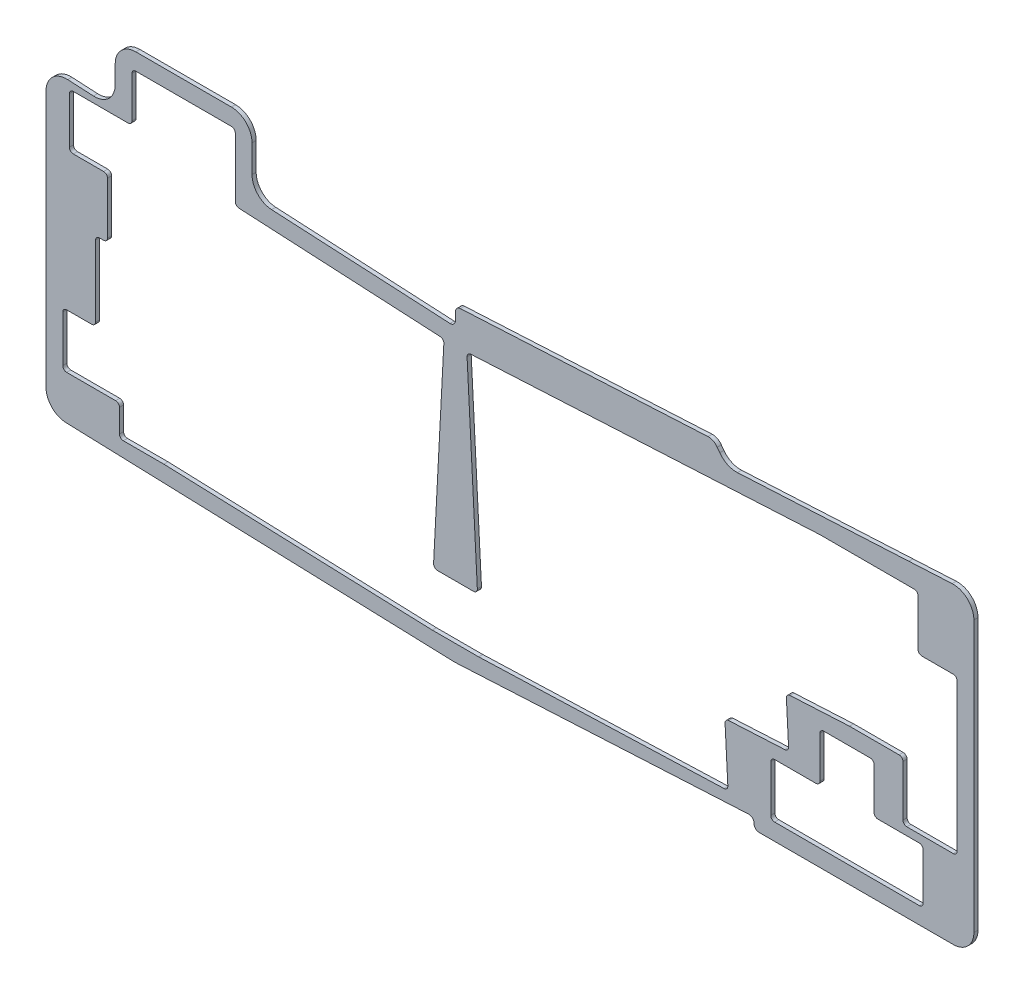
SolidWorks part; units mm, degrees
ref_plane "Piano frontale" through (0, 0, 0) normal (0, 0, 1) x (1, 0, 0)
ref_plane "Piano superiore" through (0, 0, 0) normal (0, 1, 0) x (1, 0, 0)
ref_plane "Piano destro" through (0, 0, 0) normal (1, 0, 0) x (0, 0, -1)
sketch "0" plane through (0, 0, 0) normal (0, 0, 1) x (1, 0, 0)
  line L0 (125.7508, 8.9093) -> (125.7508, 7.9088)
  line L1 (-146.1819, 97.2784) -> (-146.1819, 96.2779)
  line L2 (125.7508, 7.9088) -> (124.9498, 7.9088)
  line L3 (-146.1819, 96.2779) -> (-146.9829, 96.2779)
  line L4 (124.9498, 7.9088) -> (124.9498, 4.8082)
  line L5 (-146.9829, 96.2779) -> (-146.9829, 93.1773)
  line L6 (124.9498, 4.8082) -> (125.7508, 4.8082)
  line L7 (-146.9829, 93.1773) -> (-146.1819, 93.1773)
  line L8 (125.7508, 4.8082) -> (125.7508, -0.9905)
  line L9 (-146.1819, 93.1773) -> (-146.1819, 87.3786)
  line L10 (125.7508, -0.9905) -> (124.9498, -0.9905)
  line L11 (-146.1819, 87.3786) -> (-146.9829, 87.3786)
  line L12 (124.9498, -0.9905) -> (124.9498, -4.0911)
  line L13 (-146.9829, 87.3786) -> (-146.9829, 84.278)
  line L14 (124.9498, -4.0911) -> (125.7508, -4.0911)
  line L15 (-146.9829, 84.278) -> (-146.1819, 84.278)
  line L16 (125.7508, -4.0911) -> (125.7508, -5.0916)
  line L17 (-146.1819, 84.278) -> (-146.1819, 83.2776)
  line L18 (125.7508, -5.0916) -> (139.7498, -5.0916)
  line L19 (-146.1819, 83.2776) -> (-132.1829, 83.2776)
  line L20 (139.7498, -5.0916) -> (139.7498, -4.0911)
  line L21 (-132.1829, 83.2776) -> (-132.1829, 84.278)
  line L22 (139.7498, -4.0911) -> (140.5508, -4.0911)
  line L23 (-132.1829, 84.278) -> (-131.3819, 84.278)
  line L24 (140.5508, -4.0911) -> (140.5508, -0.9905)
  line L25 (-131.3819, 84.278) -> (-131.3819, 87.3786)
  line L26 (140.5508, -0.9905) -> (139.7498, -0.9905)
  line L27 (-131.3819, 87.3786) -> (-132.1829, 87.3786)
  line L28 (139.7498, -0.9905) -> (139.7498, 4.8082)
  line L29 (-132.1829, 87.3786) -> (-132.1829, 93.1773)
  line L30 (139.7498, 4.8082) -> (140.5508, 4.8082)
  line L31 (-132.1829, 93.1773) -> (-131.3819, 93.1773)
  line L32 (140.5508, 4.8082) -> (140.5508, 7.9088)
  line L33 (-131.3819, 93.1773) -> (-131.3819, 96.2779)
  line L34 (140.5508, 7.9088) -> (139.7498, 7.9088)
  line L35 (-131.3819, 96.2779) -> (-132.1829, 96.2779)
  line L36 (139.7498, 7.9088) -> (139.7498, 8.9093)
  line L37 (-132.1829, 96.2779) -> (-132.1829, 97.2784)
  line L38 (139.7498, 8.9093) -> (125.7508, 8.9093)
  line L39 (-132.1829, 97.2784) -> (-146.1819, 97.2784)
  line L40 (144.8008, 8.9093) -> (144.8008, 7.9088)
  line L41 (177, 32.9514) -> (177, 31.9509)
  line L42 (144.8008, 7.9088) -> (143.9998, 7.9088)
  line L43 (177, 31.9509) -> (176.199, 31.9509)
  line L44 (143.9998, 7.9088) -> (143.9998, 4.8082)
  line L45 (176.199, 31.9509) -> (176.199, 28.8503)
  line L46 (143.9998, 4.8082) -> (144.8008, 4.8082)
  line L47 (176.199, 28.8503) -> (177, 28.8503)
  line L48 (144.8008, 4.8082) -> (144.8008, -0.9905)
  line L49 (177, 28.8503) -> (177, 23.0516)
  line L50 (144.8008, -0.9905) -> (143.9998, -0.9905)
  line L51 (177, 23.0516) -> (176.199, 23.0516)
  line L52 (143.9998, -0.9905) -> (143.9998, -4.0911)
  line L53 (176.199, 23.0516) -> (176.199, 19.951)
  line L54 (143.9998, -4.0911) -> (144.8008, -4.0911)
  line L55 (176.199, 19.951) -> (177, 19.951)
  line L56 (144.8008, -4.0911) -> (144.8008, -5.0916)
  line L57 (177, 19.951) -> (177, 18.9505)
  line L58 (144.8008, -5.0916) -> (158.8008, -5.0916)
  line L59 (177, 18.9505) -> (191, 18.9505)
  line L60 (158.8008, -5.0916) -> (158.8008, -4.0911)
  line L61 (191, 18.9505) -> (191, 19.951)
  line L62 (158.8008, -4.0911) -> (159.6018, -4.0911)
  line L63 (191, 19.951) -> (191.801, 19.951)
  line L64 (159.6018, -4.0911) -> (159.6018, -0.9905)
  line L65 (191.801, 19.951) -> (191.801, 23.0516)
  line L66 (159.6018, -0.9905) -> (158.8008, -0.9905)
  line L67 (191.801, 23.0516) -> (191, 23.0516)
  line L68 (158.8008, -0.9905) -> (158.8008, 4.8082)
  line L69 (191, 23.0516) -> (191, 28.8503)
  line L70 (158.8008, 4.8082) -> (159.6018, 4.8082)
  line L71 (191, 28.8503) -> (191.801, 28.8503)
  line L72 (159.6018, 4.8082) -> (159.6018, 7.9088)
  line L73 (191.801, 28.8503) -> (191.801, 31.9509)
  line L74 (159.6018, 7.9088) -> (158.8008, 7.9088)
  line L75 (191.801, 31.9509) -> (191, 31.9509)
  line L76 (158.8008, 7.9088) -> (158.8008, 8.9093)
  line L77 (191, 31.9509) -> (191, 32.9514)
  line L78 (158.8008, 8.9093) -> (144.8008, 8.9093)
  line L79 (191, 32.9514) -> (177, 32.9514)
  line L80 (163.8488, 8.9093) -> (163.8488, 7.9088)
  line L81 (163.8488, 7.9088) -> (163.0478, 7.9088)
  line L82 (163.0478, 7.9088) -> (163.0478, 4.8082)
  line L83 (163.0478, 4.8082) -> (163.8488, 4.8082)
  line L84 (163.8488, 4.8082) -> (163.8488, -0.9905)
  line L85 (163.8488, -0.9905) -> (163.0478, -0.9905)
  line L86 (163.0478, -0.9905) -> (163.0478, -4.0911)
  line L87 (163.0478, -4.0911) -> (163.8488, -4.0911)
  line L88 (163.8488, -4.0911) -> (163.8488, -5.0916)
  line L89 (163.8488, -5.0916) -> (177.8508, -5.0916)
  line L90 (177.8508, -5.0916) -> (177.8508, -4.0911)
  line L91 (177.8508, -4.0911) -> (178.6518, -4.0911)
  line L92 (178.6518, -4.0911) -> (178.6518, -0.9905)
  line L93 (178.6518, -0.9905) -> (177.8508, -0.9905)
  line L94 (177.8508, -0.9905) -> (177.8508, 4.8082)
  line L95 (177.8508, 4.8082) -> (178.6518, 4.8082)
  line L96 (178.6518, 4.8082) -> (178.6518, 7.9088)
  line L97 (178.6518, 7.9088) -> (177.8508, 7.9088)
  line L98 (177.8508, 7.9088) -> (177.8508, 8.9093)
  line L99 (177.8508, 8.9093) -> (163.8488, 8.9093)
  line L100 (-44.1086, 8.3567) -> (-45.8316, 8.4159)
  line L101 (-45.8316, 8.4159) -> (-46.0506, 2.15)
  line L102 (-46.0506, 2.15) -> (-46.8756, 2.1789)
  line L103 (-46.8756, 2.1789) -> (-46.9726, -0.6198)
  line L104 (-46.9726, -0.6198) -> (-46.1476, -0.6488)
  line L105 (-46.1476, -0.6488) -> (-46.2616, -3.8761)
  line L106 (-46.2616, -3.8761) -> (-44.5376, -3.9367)
  line L107 (-44.5376, -3.9367) -> (-44.5686, -4.8559)
  line L108 (-44.5686, -4.8559) -> (-41.2716, -4.9717)
  line L109 (-41.2716, -4.9717) -> (-41.2396, -4.0511)
  line L110 (-41.2396, -4.0511) -> (-39.5156, -4.1118)
  line L111 (-39.5156, -4.1118) -> (-39.4026, -0.883)
  line L112 (-39.4026, -0.883) -> (-37.8786, -0.9368)
  line L113 (-37.8786, -0.9368) -> (-37.8986, -1.5362)
  line L114 (-37.8986, -1.5362) -> (-38.6986, -1.5086)
  line L115 (-38.6986, -1.5086) -> (-38.8076, -4.6065)
  line L116 (-38.8076, -4.6065) -> (-38.0066, -4.634)
  line L117 (-38.0066, -4.634) -> (-38.0426, -5.6345)
  line L118 (-38.0426, -5.6345) -> (-24.0516, -6.1223)
  line L119 (-24.0516, -6.1223) -> (-24.0156, -5.1232)
  line L120 (-24.0156, -5.1232) -> (-23.2156, -5.1522)
  line L121 (-23.2156, -5.1522) -> (-23.1086, -2.053)
  line L122 (-23.1086, -2.053) -> (-23.9076, -2.0254)
  line L123 (-23.9076, -2.0254) -> (-23.8876, -1.426)
  line L124 (-23.8876, -1.426) -> (-22.3616, -1.4783)
  line L125 (-22.3616, -1.4783) -> (-22.4746, -4.7071)
  line L126 (-22.4746, -4.7071) -> (-20.7506, -4.7677)
  line L127 (-20.7506, -4.7677) -> (-20.7826, -5.6869)
  line L128 (-20.7826, -5.6869) -> (-17.4846, -5.8012)
  line L129 (-17.4846, -5.8012) -> (-17.4526, -4.8821)
  line L130 (-17.4526, -4.8821) -> (-15.7296, -4.9427)
  line L131 (-15.7296, -4.9427) -> (-15.6176, -1.714)
  line L132 (-15.6176, -1.714) -> (-14.7916, -1.7443)
  line L133 (-14.7916, -1.7443) -> (-14.6946, 1.0558)
  line L134 (-14.6946, 1.0558) -> (-15.5186, 1.0834)
  line L135 (-15.5186, 1.0834) -> (-15.3006, 7.3507)
  line L136 (-15.3006, 7.3507) -> (-17.0246, 7.41)
  line L137 (-17.0246, 7.41) -> (-16.9906, 8.3898)
  line L138 (-16.9906, 8.3898) -> (-20.2876, 8.5041)
  line L139 (-20.2876, 8.5041) -> (-20.3226, 7.5257)
  line L140 (-20.3226, 7.5257) -> (-22.0466, 7.585)
  line L141 (-22.0466, 7.585) -> (-22.2016, 3.1188)
  line L142 (-22.2016, 3.1188) -> (-23.7266, 3.1711)
  line L143 (-23.7266, 3.1711) -> (-23.7056, 3.7719)
  line L144 (-23.7056, 3.7719) -> (-22.9056, 3.743)
  line L145 (-22.9056, 3.743) -> (-22.7976, 6.8409)
  line L146 (-22.7976, 6.8409) -> (-23.5966, 6.8698)
  line L147 (-23.5966, 6.8698) -> (-23.5626, 7.8688)
  line L148 (-23.5626, 7.8688) -> (-37.5536, 8.3567)
  line L149 (-37.5536, 8.3567) -> (-37.5876, 7.3576)
  line L150 (-37.5876, 7.3576) -> (-38.3886, 7.3852)
  line L151 (-38.3886, 7.3852) -> (-38.4956, 4.2873)
  line L152 (-38.4956, 4.2873) -> (-37.6966, 4.2598)
  line L153 (-37.6966, 4.2598) -> (-37.7186, 3.6603)
  line L154 (-37.7186, 3.6603) -> (-39.2426, 3.7127)
  line L155 (-39.2426, 3.7127) -> (-39.0856, 8.1803)
  line L156 (23.7194, 8.1189) -> (23.7717, 7.1212)
  line L157 (-39.0856, 8.1803) -> (-40.8096, 8.2409)
  line L158 (23.7717, 7.1212) -> (22.9718, 7.0792)
  line L159 (-40.8096, 8.2409) -> (-40.7756, 9.2207)
  line L160 (22.9718, 7.0792) -> (23.1341, 3.9829)
  line L161 (-40.7756, 9.2207) -> (-44.0726, 9.3351)
  line L162 (23.1341, 3.9829) -> (23.934, 4.0248)
  line L163 (-44.0726, 9.3351) -> (-44.1086, 8.3567)
  line L164 (23.934, 4.0248) -> (23.9653, 3.4262)
  line L165 (23.9653, 3.4262) -> (22.4414, 3.3464)
  line L166 (22.4414, 3.3464) -> (22.2724, 6.572)
  line L167 (22.2724, 6.572) -> (20.5498, 6.4818)
  line L168 (20.5498, 6.4818) -> (20.5017, 7.3996)
  line L169 (20.5017, 7.3996) -> (17.2072, 7.2269)
  line L170 (17.2072, 7.2269) -> (17.2553, 6.3091)
  line L171 (17.2553, 6.3091) -> (15.5326, 6.2188)
  line L172 (15.5326, 6.2188) -> (15.7017, 2.9931)
  line L173 (15.7017, 2.9931) -> (14.8768, 2.9499)
  line L174 (14.8768, 2.9499) -> (15.0234, 0.1536)
  line L175 (15.0234, 0.1536) -> (15.8482, 0.1968)
  line L176 (15.8482, 0.1968) -> (16.1764, -6.0647)
  line L177 (16.1764, -6.0647) -> (17.899, -5.9744)
  line L178 (17.899, -5.9744) -> (17.9503, -6.9529)
  line L179 (17.9503, -6.9529) -> (21.2448, -6.7802)
  line L180 (21.2448, -6.7802) -> (21.1935, -5.8018)
  line L181 (21.1935, -5.8018) -> (22.9161, -5.7115)
  line L182 (22.9161, -5.7115) -> (22.6822, -1.2472)
  line L183 (22.6822, -1.2472) -> (24.2061, -1.1674)
  line L184 (24.2061, -1.1674) -> (24.2375, -1.7674)
  line L185 (24.2375, -1.7674) -> (23.4376, -1.8094)
  line L186 (23.4376, -1.8094) -> (23.5998, -4.9043)
  line L187 (23.5998, -4.9043) -> (24.3997, -4.8624)
  line L188 (24.3997, -4.8624) -> (24.4521, -5.8614)
  line L189 (24.4521, -5.8614) -> (38.4319, -5.1288)
  line L190 (38.4319, -5.1288) -> (38.3796, -4.1297)
  line L191 (38.3796, -4.1297) -> (39.1795, -4.0878)
  line L192 (39.1795, -4.0878) -> (39.0173, -0.9929)
  line L193 (39.0173, -0.9929) -> (38.2174, -1.0348)
  line L194 (38.2174, -1.0348) -> (38.1859, -0.4347)
  line L195 (38.1859, -0.4347) -> (39.7098, -0.3549)
  line L196 (39.7098, -0.3549) -> (39.9438, -4.8191)
  line L197 (39.9438, -4.8191) -> (41.6664, -4.7288)
  line L198 (41.6664, -4.7288) -> (41.7177, -5.7073)
  line L199 (41.7177, -5.7073) -> (45.0122, -5.5346)
  line L200 (45.0122, -5.5346) -> (44.9609, -4.5562)
  line L201 (44.9609, -4.5562) -> (46.6835, -4.4659)
  line L202 (46.6835, -4.4659) -> (46.3554, 1.7956)
  line L203 (46.3554, 1.7956) -> (47.1802, 1.8388)
  line L204 (47.1802, 1.8388) -> (47.0337, 4.6352)
  line L205 (47.0337, 4.6352) -> (46.2088, 4.592)
  line L206 (46.2088, 4.592) -> (46.0398, 7.8176)
  line L207 (46.0398, 7.8176) -> (44.3171, 7.7274)
  line L208 (44.3171, 7.7274) -> (44.269, 8.6452)
  line L209 (44.269, 8.6452) -> (40.9746, 8.4725)
  line L210 (40.9746, 8.4725) -> (41.0227, 7.5547)
  line L211 (41.0227, 7.5547) -> (39.3, 7.4644)
  line L212 (39.3, 7.4644) -> (39.4691, 4.2387)
  line L213 (39.4691, 4.2387) -> (37.9452, 4.1589)
  line L214 (37.9452, 4.1589) -> (37.9138, 4.7575)
  line L215 (37.9138, 4.7575) -> (38.7137, 4.7994)
  line L216 (38.7137, 4.7994) -> (38.5514, 7.8957)
  line L217 (38.5514, 7.8957) -> (37.7515, 7.8538)
  line L218 (37.7515, 7.8538) -> (37.6992, 8.8515)
  line L219 (37.6992, 8.8515) -> (23.7194, 8.1189)
  line L220 (-124.5132, 10.6803) -> (-124.5132, 9.6812)
  line L221 (-124.5132, 9.6812) -> (-125.3122, 9.6812)
  line L222 (-125.3122, 9.6812) -> (-125.3122, 6.5806)
  line L223 (-125.3122, 6.5806) -> (-124.5132, 6.5806)
  line L224 (-124.5132, 6.5806) -> (-124.5132, 0.7804)
  line L225 (-124.5132, 0.7804) -> (-125.3122, 0.7804)
  line L226 (-125.3122, 0.7804) -> (-125.3122, -2.3188)
  line L227 (-125.3122, -2.3188) -> (-124.5132, -2.3188)
  line L228 (-124.5132, -2.3188) -> (-124.5132, -3.3192)
  line L229 (-124.5132, -3.3192) -> (-110.5121, -3.3192)
  line L230 (-110.5121, -3.3192) -> (-110.5121, -2.3188)
  line L231 (-110.5121, -2.3188) -> (-109.7127, -2.3188)
  line L232 (-109.7127, -2.3188) -> (-109.7127, 0.7804)
  line L233 (-109.7127, 0.7804) -> (-110.5121, 0.7804)
  line L234 (-110.5121, 0.7804) -> (-110.5121, 6.5806)
  line L235 (-110.5121, 6.5806) -> (-109.7127, 6.5806)
  line L236 (-109.7127, 6.5806) -> (-109.7127, 9.6812)
  line L237 (-109.7127, 9.6812) -> (-110.5121, 9.6812)
  line L238 (-110.5121, 9.6812) -> (-110.5121, 10.6803)
  line L239 (-110.5121, 10.6803) -> (-124.5132, 10.6803)
  line L240 (-99.5931, 10.2215) -> (-99.628, 9.223)
  line L241 (-99.628, 9.223) -> (-100.4275, 9.2509)
  line L242 (-100.4275, 9.2509) -> (-100.5357, 6.1522)
  line L243 (-100.5357, 6.1522) -> (-99.7362, 6.1243)
  line L244 (-99.7362, 6.1243) -> (-99.9386, 0.3276)
  line L245 (-99.9386, 0.3276) -> (-100.7381, 0.3556)
  line L246 (-100.7381, 0.3556) -> (-100.8463, -2.7417)
  line L247 (-100.8463, -2.7417) -> (-100.0468, -2.7697)
  line L248 (-100.0468, -2.7697) -> (-100.0817, -3.7695)
  line L249 (-100.0817, -3.7695) -> (-86.0902, -4.258)
  line L250 (-86.0902, -4.258) -> (-86.0553, -3.2583)
  line L251 (-86.0553, -3.2583) -> (-85.2548, -3.2862)
  line L252 (-85.2548, -3.2862) -> (-85.1466, -0.1889)
  line L253 (-85.1466, -0.1889) -> (-85.9471, -0.1609)
  line L254 (-85.9471, -0.1609) -> (-85.7447, 5.6357)
  line L255 (-85.7447, 5.6357) -> (-84.9442, 5.6078)
  line L256 (-84.9442, 5.6078) -> (-84.836, 8.7065)
  line L257 (-84.836, 8.7065) -> (-85.6365, 8.7344)
  line L258 (-85.6365, 8.7344) -> (-85.6016, 9.7329)
  line L259 (-85.6016, 9.7329) -> (-99.5931, 10.2215)
  line L260 (-74.7946, 9.3905) -> (-74.8295, 8.392)
  line L261 (-74.8295, 8.392) -> (-75.628, 8.4198)
  line L262 (-75.628, 8.4198) -> (-75.7362, 5.3211)
  line L263 (-75.7362, 5.3211) -> (-74.9377, 5.2933)
  line L264 (-74.9377, 5.2933) -> (-75.1401, -0.5034)
  line L265 (-75.1401, -0.5034) -> (-75.9386, -0.4755)
  line L266 (-75.9386, -0.4755) -> (-76.0468, -3.5728)
  line L267 (-76.0468, -3.5728) -> (-75.2483, -3.6007)
  line L268 (-75.2483, -3.6007) -> (-75.2832, -4.6005)
  line L269 (-75.2832, -4.6005) -> (-61.2907, -5.0891)
  line L270 (-61.2907, -5.0891) -> (-61.2558, -4.0894)
  line L271 (-61.2558, -4.0894) -> (-60.4573, -4.1172)
  line L272 (-60.4573, -4.1172) -> (-60.3491, -1.0199)
  line L273 (-60.3491, -1.0199) -> (-61.1476, -0.992)
  line L274 (-61.1476, -0.992) -> (-60.9452, 4.8046)
  line L275 (-60.9452, 4.8046) -> (-60.1467, 4.7767)
  line L276 (-60.1467, 4.7767) -> (-60.0385, 7.8755)
  line L277 (-60.0385, 7.8755) -> (-60.837, 7.9033)
  line L278 (-60.837, 7.9033) -> (-60.8021, 8.9018)
  line L279 (-60.8021, 8.9018) -> (-74.7946, 9.3905)
  line L280 (61.1769, 9.8704) -> (61.2292, 8.8726)
  line L281 (61.2292, 8.8726) -> (60.4293, 8.8307)
  line L282 (60.4293, 8.8307) -> (60.5915, 5.7344)
  line L283 (60.5915, 5.7344) -> (61.3914, 5.7763)
  line L284 (61.3914, 5.7763) -> (61.695, -0.016)
  line L285 (61.695, -0.016) -> (60.8951, -0.0579)
  line L286 (60.8951, -0.0579) -> (61.0573, -3.1528)
  line L287 (61.0573, -3.1528) -> (61.8572, -3.1109)
  line L288 (61.8572, -3.1109) -> (61.9096, -4.1099)
  line L289 (61.9096, -4.1099) -> (75.8894, -3.3773)
  line L290 (75.8894, -3.3773) -> (75.837, -2.3783)
  line L291 (75.837, -2.3783) -> (76.6369, -2.3363)
  line L292 (76.6369, -2.3363) -> (76.4747, 0.7586)
  line L293 (76.4747, 0.7586) -> (75.6748, 0.7167)
  line L294 (75.6748, 0.7167) -> (75.3713, 6.5089)
  line L295 (75.3713, 6.5089) -> (76.1712, 6.5509)
  line L296 (76.1712, 6.5509) -> (76.0089, 9.6472)
  line L297 (76.0089, 9.6472) -> (75.209, 9.6053)
  line L298 (75.209, 9.6053) -> (75.1567, 10.603)
  line L299 (75.1567, 10.603) -> (61.1769, 9.8704)
  line L300 (84.9562, 11.1166) -> (85.0085, 10.1189)
  line L301 (85.0085, 10.1189) -> (84.2106, 10.077)
  line L302 (84.2106, 10.077) -> (84.3729, 6.9807)
  line L303 (84.3729, 6.9807) -> (85.1708, 7.0225)
  line L304 (85.1708, 7.0225) -> (85.4744, 1.2303)
  line L305 (85.4744, 1.2303) -> (84.6765, 1.1884)
  line L306 (84.6765, 1.1884) -> (84.8387, -1.9065)
  line L307 (84.8387, -1.9065) -> (85.6366, -1.8647)
  line L308 (85.6366, -1.8647) -> (85.6889, -2.8637)
  line L309 (85.6889, -2.8637) -> (99.6697, -2.131)
  line L310 (99.6697, -2.131) -> (99.6174, -1.132)
  line L311 (99.6174, -1.132) -> (100.4163, -1.0901)
  line L312 (100.4163, -1.0901) -> (100.2541, 2.0048)
  line L313 (100.2541, 2.0048) -> (99.4552, 1.963)
  line L314 (99.4552, 1.963) -> (99.1516, 7.7552)
  line L315 (99.1516, 7.7552) -> (99.9505, 7.7971)
  line L316 (99.9505, 7.7971) -> (99.7882, 10.8934)
  line L317 (99.7882, 10.8934) -> (98.9893, 10.8516)
  line L318 (98.9893, 10.8516) -> (98.9371, 11.8493)
  line L319 (98.9371, 11.8493) -> (84.9562, 11.1166)
  line L320 (144.8008, 27.9592) -> (144.8008, 26.9588)
  line L321 (177, 52.0013) -> (177, 51.0009)
  line L322 (177, 71.0513) -> (177, 70.0509)
  line L323 (144.8008, 26.9588) -> (143.9998, 26.9588)
  line L324 (177, 51.0009) -> (176.199, 51.0009)
  line L325 (177, 70.0509) -> (176.199, 70.0509)
  line L326 (143.9998, 26.9588) -> (143.9998, 23.8582)
  line L327 (176.199, 51.0009) -> (176.199, 47.9003)
  line L328 (176.199, 70.0509) -> (176.199, 66.9503)
  line L329 (143.9998, 23.8582) -> (144.8008, 23.8582)
  line L330 (176.199, 47.9003) -> (177, 47.9003)
  line L331 (176.199, 66.9503) -> (177, 66.9503)
  line L332 (144.8008, 23.8582) -> (144.8008, 18.0595)
  line L333 (177, 47.9003) -> (177, 42.1016)
  line L334 (177, 66.9503) -> (177, 61.1516)
  line L335 (144.8008, 18.0595) -> (143.9998, 18.0595)
  line L336 (177, 42.1016) -> (176.199, 42.1016)
  line L337 (177, 61.1516) -> (176.199, 61.1516)
  line L338 (143.9998, 18.0595) -> (143.9998, 14.9589)
  line L339 (176.199, 42.1016) -> (176.199, 39.001)
  line L340 (176.199, 61.1516) -> (176.199, 58.051)
  line L341 (143.9998, 14.9589) -> (144.8008, 14.9589)
  line L342 (176.199, 39.001) -> (177, 39.001)
  line L343 (176.199, 58.051) -> (177, 58.051)
  line L344 (144.8008, 14.9589) -> (144.8008, 13.9584)
  line L345 (177, 39.001) -> (177, 38.0005)
  line L346 (177, 58.051) -> (177, 57.0505)
  line L347 (144.8008, 13.9584) -> (158.8008, 13.9584)
  line L348 (177, 38.0005) -> (191, 38.0005)
  line L349 (177, 57.0505) -> (191, 57.0505)
  line L350 (158.8008, 13.9584) -> (158.8008, 14.9589)
  line L351 (191, 38.0005) -> (191, 39.001)
  line L352 (191, 57.0505) -> (191, 58.051)
  line L353 (158.8008, 14.9589) -> (159.6018, 14.9589)
  line L354 (191, 39.001) -> (191.801, 39.001)
  line L355 (191, 58.051) -> (191.801, 58.051)
  line L356 (159.6018, 14.9589) -> (159.6018, 18.0595)
  line L357 (191.801, 39.001) -> (191.801, 42.1016)
  line L358 (191.801, 58.051) -> (191.801, 61.1516)
  line L359 (159.6018, 18.0595) -> (158.8008, 18.0595)
  line L360 (191.801, 42.1016) -> (191, 42.1016)
  line L361 (191.801, 61.1516) -> (191, 61.1516)
  line L362 (158.8008, 18.0595) -> (158.8008, 23.8582)
  line L363 (191, 42.1016) -> (191, 47.9003)
  line L364 (191, 61.1516) -> (191, 66.9503)
  line L365 (158.8008, 23.8582) -> (159.6018, 23.8582)
  line L366 (191, 47.9003) -> (191.801, 47.9003)
  line L367 (191, 66.9503) -> (191.801, 66.9503)
  line L368 (159.6018, 23.8582) -> (159.6018, 26.9588)
  line L369 (191.801, 47.9003) -> (191.801, 51.0009)
  line L370 (191.801, 66.9503) -> (191.801, 70.0509)
  line L371 (159.6018, 26.9588) -> (158.8008, 26.9588)
  line L372 (191.801, 51.0009) -> (191, 51.0009)
  line L373 (191.801, 70.0509) -> (191, 70.0509)
  line L374 (158.8008, 26.9588) -> (158.8008, 27.9592)
  line L375 (191, 51.0009) -> (191, 52.0013)
  line L376 (191, 70.0509) -> (191, 71.0513)
  line L377 (158.8008, 27.9592) -> (144.8008, 27.9592)
  line L378 (191, 52.0013) -> (177, 52.0013)
  line L379 (191, 71.0513) -> (177, 71.0513)
  line L380 (27, 88.0936) -> (-28, 88.0936)
  line L381 (-7, 7) -> (-7, 6.0009)
  line L382 (-148.7544, 21.6507) -> (-149.5548, 21.6507)
  line L383 (-7, 6.0009) -> (-7.8004, 6.0009)
  line L384 (-149.5548, 21.6507) -> (-149.5548, 18.5501)
  line L385 (-7.8004, 6.0009) -> (-7.8004, 2.9003)
  line L386 (-149.5548, 18.5501) -> (-148.7544, 18.5501)
  line L387 (-7.8004, 2.9003) -> (-7, 2.9003)
  line L388 (-106.1319, 84.277) -> (-161, 84.277)
  line L389 (-7, 2.9003) -> (-7, -2.8999)
  line L390 (-148.7544, 12.7499) -> (-149.5548, 12.7499)
  line L391 (-7, -2.8999) -> (-7.8004, -2.8999)
  line L392 (-149.5548, 12.7499) -> (-149.5548, 9.6507)
  line L393 (-7.8004, -2.8999) -> (-7.8004, -5.9991)
  line L394 (-149.5548, 9.6507) -> (-148.7544, 9.6507)
  line L395 (-7.8004, -5.9991) -> (-7, -5.9991)
  line L397 (-7, -5.9991) -> (-7, -6.9995)
  line L398 (-148.7544, 8.6503) -> (-134.7547, 8.6503)
  line L399 (-7, -6.9995) -> (6.9997, -6.9995)
  line L400 (-134.7547, 8.6503) -> (-134.7547, 9.6507)
  line L401 (6.9997, -6.9995) -> (6.9997, -5.9991)
  line L402 (-134.7547, 9.6507) -> (-133.9557, 9.6507)
  line L403 (6.9997, -5.9991) -> (7.7987, -5.9991)
  line L404 (-133.9557, 9.6507) -> (-133.9557, 12.7499)
  line L405 (7.7987, -5.9991) -> (7.7987, -2.8999)
  line L406 (-133.9557, 12.7499) -> (-134.7547, 12.7499)
  line L407 (7.7987, -2.8999) -> (6.9997, -2.8999)
  line L408 (-134.7547, 12.7499) -> (-134.7547, 18.5501)
  line L409 (6.9997, -2.8999) -> (6.9997, 2.9003)
  line L410 (-134.7547, 18.5501) -> (-133.9557, 18.5501)
  line L411 (6.9997, 2.9003) -> (7.7987, 2.9003)
  line L412 (-133.9557, 18.5501) -> (-133.9557, 21.6507)
  line L413 (7.7987, 2.9003) -> (7.7987, 6.0009)
  line L414 (-133.9557, 21.6507) -> (-134.7547, 21.6507)
  line L415 (7.7987, 6.0009) -> (6.9997, 6.0009)
  line L416 (-134.7547, 21.6507) -> (-134.7547, 22.6498)
  line L417 (6.9997, 6.0009) -> (6.9997, 7)
  line L418 (-134.7547, 22.6498) -> (-148.7544, 22.6498)
  line L419 (6.9997, 7) -> (-7, 7)
  line L420 (-124.5132, 34.1285) -> (-124.5132, 33.128)
  line L421 (-124.5132, 33.128) -> (-125.3122, 33.128)
  line L422 (-125.3122, 33.128) -> (-125.3122, 30.0285)
  line L423 (-125.3122, 30.0285) -> (-124.5132, 30.0285)
  line L424 (-124.5132, 30.0285) -> (-124.5132, 24.2271)
  line L425 (-124.5132, 24.2271) -> (-125.3122, 24.2271)
  line L426 (-125.3122, 24.2271) -> (-125.3122, 21.1279)
  line L427 (-125.3122, 21.1279) -> (-124.5132, 21.1279)
  line L428 (-124.5132, 21.1279) -> (-124.5132, 20.1275)
  line L429 (-124.5132, 20.1275) -> (-110.5121, 20.1275)
  line L430 (-110.5121, 20.1275) -> (-110.5121, 21.1279)
  line L431 (-110.5121, 21.1279) -> (-109.7127, 21.1279)
  line L432 (-109.7127, 21.1279) -> (-109.7127, 24.2271)
  line L433 (-109.7127, 24.2271) -> (-110.5121, 24.2271)
  line L434 (-110.5121, 24.2271) -> (-110.5121, 30.0285)
  line L435 (-110.5121, 30.0285) -> (-109.7127, 30.0285)
  line L436 (-109.7127, 30.0285) -> (-109.7127, 33.128)
  line L437 (-109.7127, 33.128) -> (-110.5121, 33.128)
  line L438 (-110.5121, 33.128) -> (-110.5121, 34.1285)
  line L439 (-110.5121, 34.1285) -> (-124.5132, 34.1285)
  line L440 (-101.1692, 33.8521) -> (-101.2216, 32.853)
  line L441 (-101.2216, 32.853) -> (-102.0194, 32.8948)
  line L442 (-102.0194, 32.8948) -> (-102.1816, 29.7996)
  line L443 (-102.1816, 29.7996) -> (-101.3838, 29.7578)
  line L444 (-101.3838, 29.7578) -> (-101.6874, 23.9643)
  line L445 (-101.6874, 23.9643) -> (-102.4852, 24.0061)
  line L446 (-102.4852, 24.0061) -> (-102.6474, 20.9112)
  line L447 (-102.6474, 20.9112) -> (-101.8496, 20.8694)
  line L448 (-101.8496, 20.8694) -> (-101.902, 19.8703)
  line L449 (-101.902, 19.8703) -> (-87.9211, 19.1376)
  line L450 (-87.9211, 19.1376) -> (-87.8688, 20.1367)
  line L451 (-87.8688, 20.1367) -> (-87.0689, 20.0947)
  line L452 (-87.0689, 20.0947) -> (-86.9067, 23.1897)
  line L453 (-86.9067, 23.1897) -> (-87.7066, 23.2316)
  line L454 (-87.7066, 23.2316) -> (-87.403, 29.0251)
  line L455 (-87.403, 29.0251) -> (-86.6031, 28.9831)
  line L456 (-86.6031, 28.9831) -> (-86.4409, 32.0784)
  line L457 (-86.4409, 32.0784) -> (-87.2408, 32.1203)
  line L458 (-87.2408, 32.1203) -> (-87.1884, 33.1194)
  line L459 (-87.1884, 33.1194) -> (-101.1692, 33.8521)
  line L460 (-82.1453, 32.8551) -> (-82.1977, 31.856)
  line L461 (-82.1977, 31.856) -> (-82.9956, 31.8978)
  line L462 (-82.9956, 31.8978) -> (-83.1578, 28.8026)
  line L463 (-83.1578, 28.8026) -> (-82.3599, 28.7608)
  line L464 (-82.3599, 28.7608) -> (-82.6635, 22.9673)
  line L465 (-82.6635, 22.9673) -> (-83.4614, 23.0091)
  line L466 (-83.4614, 23.0091) -> (-83.6236, 19.9142)
  line L467 (-83.6236, 19.9142) -> (-82.8257, 19.8724)
  line L468 (-82.8257, 19.8724) -> (-82.8781, 18.8733)
  line L469 (-82.8781, 18.8733) -> (-68.8973, 18.1406)
  line L470 (-68.8973, 18.1406) -> (-68.8449, 19.1397)
  line L471 (-68.8449, 19.1397) -> (-68.045, 19.0977)
  line L472 (-68.045, 19.0977) -> (-67.8828, 22.1927)
  line L473 (-67.8828, 22.1927) -> (-68.6827, 22.2346)
  line L474 (-68.6827, 22.2346) -> (-68.3791, 28.0281)
  line L475 (-68.3791, 28.0281) -> (-67.5792, 27.9861)
  line L476 (-67.5792, 27.9861) -> (-67.417, 31.0814)
  line L477 (-67.417, 31.0814) -> (-68.2169, 31.1233)
  line L478 (-68.2169, 31.1233) -> (-68.1645, 32.1224)
  line L479 (-68.1645, 32.1224) -> (-82.1453, 32.8551)
  line L480 (-63.1214, 31.8581) -> (-63.1738, 30.859)
  line L481 (-63.1738, 30.859) -> (-63.9717, 30.9008)
  line L482 (-63.9717, 30.9008) -> (-64.1339, 27.8056)
  line L483 (-64.1339, 27.8056) -> (-63.336, 27.7638)
  line L484 (-63.336, 27.7638) -> (-63.6396, 21.9703)
  line L485 (-63.6396, 21.9703) -> (-64.4375, 22.0121)
  line L486 (-64.4375, 22.0121) -> (-64.5997, 18.9172)
  line L487 (-64.5997, 18.9172) -> (-63.8018, 18.8754)
  line L488 (-63.8018, 18.8754) -> (-63.8542, 17.8763)
  line L489 (-63.8542, 17.8763) -> (-49.8734, 17.1436)
  line L490 (-49.8734, 17.1436) -> (-49.821, 18.1427)
  line L491 (-49.821, 18.1427) -> (-49.0211, 18.1007)
  line L492 (-49.0211, 18.1007) -> (-48.8589, 21.1957)
  line L493 (-48.8589, 21.1957) -> (-49.6588, 21.2376)
  line L494 (-49.6588, 21.2376) -> (-49.3552, 27.0311)
  line L495 (-49.3552, 27.0311) -> (-48.5553, 26.9891)
  line L496 (-48.5553, 26.9891) -> (-48.3931, 30.0844)
  line L497 (-48.3931, 30.0844) -> (-49.193, 30.1263)
  line L498 (-49.193, 30.1263) -> (-49.1406, 31.1254)
  line L499 (-49.1406, 31.1254) -> (-63.1214, 31.8581)
  line L500 (-44.0975, 30.8611) -> (-44.1499, 29.862)
  line L501 (-44.1499, 29.862) -> (-44.9478, 29.9038)
  line L502 (-44.9478, 29.9038) -> (-45.11, 26.8086)
  line L503 (-45.11, 26.8086) -> (-44.3121, 26.7668)
  line L504 (-44.3121, 26.7668) -> (-44.6157, 20.9733)
  line L505 (-44.6157, 20.9733) -> (-45.4136, 21.0151)
  line L506 (-45.4136, 21.0151) -> (-45.5758, 17.9202)
  line L507 (-45.5758, 17.9202) -> (-44.7779, 17.8784)
  line L508 (-44.7779, 17.8784) -> (-44.8303, 16.8793)
  line L509 (-44.8303, 16.8793) -> (-30.8495, 16.1466)
  line L510 (-30.8495, 16.1466) -> (-30.7971, 17.1457)
  line L511 (-30.7971, 17.1457) -> (-29.9972, 17.1037)
  line L512 (-29.9972, 17.1037) -> (-29.835, 20.1987)
  line L513 (-29.835, 20.1987) -> (-30.6349, 20.2406)
  line L514 (-30.6349, 20.2406) -> (-30.3313, 26.0341)
  line L515 (-30.3313, 26.0341) -> (-29.5314, 25.9921)
  line L516 (-29.5314, 25.9921) -> (-29.3692, 29.0874)
  line L517 (-29.3692, 29.0874) -> (-30.1691, 29.1293)
  line L518 (-30.1691, 29.1293) -> (-30.1167, 30.1284)
  line L519 (-30.1167, 30.1284) -> (-44.0975, 30.8611)
  line L520 (-25.0736, 29.8641) -> (-25.126, 28.865)
  line L521 (-25.126, 28.865) -> (-25.9239, 28.9068)
  line L522 (-25.9239, 28.9068) -> (-26.0861, 25.8116)
  line L523 (-26.0861, 25.8116) -> (-25.2882, 25.7698)
  line L524 (-25.2882, 25.7698) -> (-25.5918, 19.9763)
  line L525 (-25.5918, 19.9763) -> (-26.3897, 20.0181)
  line L526 (-26.3897, 20.0181) -> (-26.5519, 16.9232)
  line L527 (-26.5519, 16.9232) -> (-25.754, 16.8814)
  line L528 (-25.754, 16.8814) -> (-25.8064, 15.8823)
  line L529 (-25.8064, 15.8823) -> (-11.8256, 15.1496)
  line L530 (-11.8256, 15.1496) -> (-11.7732, 16.1487)
  line L531 (-11.7732, 16.1487) -> (-10.9733, 16.1067)
  line L532 (-10.9733, 16.1067) -> (-10.8111, 19.2017)
  line L533 (-10.8111, 19.2017) -> (-11.611, 19.2436)
  line L534 (-11.611, 19.2436) -> (-11.3074, 25.0371)
  line L535 (-11.3074, 25.0371) -> (-10.5075, 24.9951)
  line L536 (-10.5075, 24.9951) -> (-10.3453, 28.0904)
  line L537 (-10.3453, 28.0904) -> (-11.1452, 28.1323)
  line L538 (-11.1452, 28.1323) -> (-11.0928, 29.1314)
  line L539 (-11.0928, 29.1314) -> (-25.0736, 29.8641)
  line L540 (11.0928, 29.1314) -> (11.1452, 28.1323)
  line L541 (11.1452, 28.1323) -> (10.3453, 28.0904)
  line L542 (10.3453, 28.0904) -> (10.5075, 24.9951)
  line L543 (10.5075, 24.9951) -> (11.3074, 25.0371)
  line L544 (11.3074, 25.0371) -> (11.611, 19.2436)
  line L545 (11.611, 19.2436) -> (10.8111, 19.2017)
  line L546 (10.8111, 19.2017) -> (10.9733, 16.1067)
  line L547 (10.9733, 16.1067) -> (11.7732, 16.1487)
  line L548 (11.7732, 16.1487) -> (11.8256, 15.1496)
  line L549 (11.8256, 15.1496) -> (25.8054, 15.8823)
  line L550 (25.8054, 15.8823) -> (25.753, 16.8813)
  line L551 (25.753, 16.8813) -> (26.5529, 16.9232)
  line L552 (26.5529, 16.9232) -> (26.3907, 20.0182)
  line L553 (26.3907, 20.0182) -> (25.5908, 19.9763)
  line L554 (25.5908, 19.9763) -> (25.2872, 25.7697)
  line L555 (25.2872, 25.7697) -> (26.0871, 25.8116)
  line L556 (26.0871, 25.8116) -> (25.9249, 28.9069)
  line L557 (25.9249, 28.9069) -> (25.125, 28.865)
  line L558 (25.125, 28.865) -> (25.0726, 29.8641)
  line L559 (25.0726, 29.8641) -> (11.0928, 29.1314)
  line L560 (30.1167, 30.1284) -> (30.1691, 29.1293)
  line L561 (30.1691, 29.1293) -> (29.3692, 29.0874)
  line L562 (29.3692, 29.0874) -> (29.5314, 25.9921)
  line L563 (29.5314, 25.9921) -> (30.3313, 26.0341)
  line L564 (30.3313, 26.0341) -> (30.6349, 20.2406)
  line L565 (30.6349, 20.2406) -> (29.835, 20.1987)
  line L566 (29.835, 20.1987) -> (29.9972, 17.1037)
  line L567 (29.9972, 17.1037) -> (30.7971, 17.1457)
  line L568 (30.7971, 17.1457) -> (30.8495, 16.1466)
  line L569 (30.8495, 16.1466) -> (44.8293, 16.8793)
  line L570 (44.8293, 16.8793) -> (44.7769, 17.8783)
  line L571 (44.7769, 17.8783) -> (45.5768, 17.9202)
  line L572 (45.5768, 17.9202) -> (45.4146, 21.0152)
  line L573 (45.4146, 21.0152) -> (44.6147, 20.9733)
  line L574 (44.6147, 20.9733) -> (44.3111, 26.7667)
  line L575 (44.3111, 26.7667) -> (45.111, 26.8086)
  line L576 (45.111, 26.8086) -> (44.9488, 29.9039)
  line L577 (44.9488, 29.9039) -> (44.1489, 29.862)
  line L578 (44.1489, 29.862) -> (44.0965, 30.8611)
  line L579 (44.0965, 30.8611) -> (30.1167, 30.1284)
  line L580 (49.1406, 31.1254) -> (49.193, 30.1263)
  line L581 (49.193, 30.1263) -> (48.3931, 30.0844)
  line L582 (48.3931, 30.0844) -> (48.5553, 26.9891)
  line L583 (48.5553, 26.9891) -> (49.3552, 27.0311)
  line L584 (49.3552, 27.0311) -> (49.6588, 21.2376)
  line L585 (49.6588, 21.2376) -> (48.8589, 21.1957)
  line L586 (48.8589, 21.1957) -> (49.0211, 18.1007)
  line L587 (49.0211, 18.1007) -> (49.821, 18.1427)
  line L588 (49.821, 18.1427) -> (49.8734, 17.1436)
  line L589 (49.8734, 17.1436) -> (63.8532, 17.8763)
  line L590 (63.8532, 17.8763) -> (63.8008, 18.8753)
  line L591 (63.8008, 18.8753) -> (64.5987, 18.9171)
  line L592 (64.5987, 18.9171) -> (64.4365, 22.0121)
  line L593 (64.4365, 22.0121) -> (63.6386, 21.9703)
  line L594 (63.6386, 21.9703) -> (63.335, 27.7637)
  line L595 (63.335, 27.7637) -> (64.1329, 27.8055)
  line L596 (64.1329, 27.8055) -> (63.9707, 30.9008)
  line L597 (63.9707, 30.9008) -> (63.1728, 30.859)
  line L598 (63.1728, 30.859) -> (63.1204, 31.8581)
  line L599 (63.1204, 31.8581) -> (49.1406, 31.1254)
  line L600 (68.1625, 32.1223) -> (68.2149, 31.1232)
  line L601 (68.2149, 31.1232) -> (67.417, 31.0814)
  line L602 (67.417, 31.0814) -> (67.5792, 27.9861)
  line L603 (67.5792, 27.9861) -> (68.3771, 28.0279)
  line L604 (68.3771, 28.0279) -> (68.6807, 22.2345)
  line L605 (68.6807, 22.2345) -> (67.8828, 22.1927)
  line L606 (67.8828, 22.1927) -> (68.045, 19.0977)
  line L607 (68.045, 19.0977) -> (68.8429, 19.1395)
  line L608 (68.8429, 19.1395) -> (68.8953, 18.1405)
  line L609 (68.8953, 18.1405) -> (82.8771, 18.8733)
  line L610 (82.8771, 18.8733) -> (82.8247, 19.8723)
  line L611 (82.8247, 19.8723) -> (83.6246, 19.9142)
  line L612 (83.6246, 19.9142) -> (83.4624, 23.0092)
  line L613 (83.4624, 23.0092) -> (82.6625, 22.9673)
  line L614 (82.6625, 22.9673) -> (82.3589, 28.7607)
  line L615 (82.3589, 28.7607) -> (83.1588, 28.8026)
  line L616 (83.1588, 28.8026) -> (82.9966, 31.8979)
  line L617 (82.9966, 31.8979) -> (82.1967, 31.856)
  line L618 (82.1967, 31.856) -> (82.1443, 32.8551)
  line L619 (82.1443, 32.8551) -> (68.1625, 32.1223)
  line L620 (87.1884, 33.1194) -> (87.2408, 32.1203)
  line L621 (87.2408, 32.1203) -> (86.4409, 32.0784)
  line L622 (86.4409, 32.0784) -> (86.6031, 28.9831)
  line L623 (86.6031, 28.9831) -> (87.403, 29.0251)
  line L624 (87.403, 29.0251) -> (87.7066, 23.2316)
  line L625 (87.7066, 23.2316) -> (86.9067, 23.1897)
  line L626 (86.9067, 23.1897) -> (87.0689, 20.0947)
  line L627 (87.0689, 20.0947) -> (87.8688, 20.1367)
  line L628 (87.8688, 20.1367) -> (87.9211, 19.1376)
  line L629 (87.9211, 19.1376) -> (101.901, 19.8703)
  line L630 (101.901, 19.8703) -> (101.8486, 20.8693)
  line L631 (101.8486, 20.8693) -> (102.6485, 20.9112)
  line L632 (102.6485, 20.9112) -> (102.4863, 24.0062)
  line L633 (102.4863, 24.0062) -> (101.6864, 23.9643)
  line L634 (101.6864, 23.9643) -> (101.3828, 29.7577)
  line L635 (101.3828, 29.7577) -> (102.1827, 29.7996)
  line L636 (102.1827, 29.7996) -> (102.0205, 32.8949)
  line L637 (102.0205, 32.8949) -> (101.2206, 32.853)
  line L638 (101.2206, 32.853) -> (101.1682, 33.8521)
  line L639 (101.1682, 33.8521) -> (87.1884, 33.1194)
  line L640 (108.59, 34.241) -> (108.6424, 33.2419)
  line L641 (108.6424, 33.2419) -> (107.8425, 33.2)
  line L642 (107.8425, 33.2) -> (108.0047, 30.1047)
  line L643 (108.0047, 30.1047) -> (108.8046, 30.1467)
  line L644 (108.8046, 30.1467) -> (109.1082, 24.3532)
  line L645 (109.1082, 24.3532) -> (108.3083, 24.3113)
  line L646 (108.3083, 24.3113) -> (108.4705, 21.2163)
  line L647 (108.4705, 21.2163) -> (109.2704, 21.2583)
  line L648 (109.2704, 21.2583) -> (109.3228, 20.2592)
  line L649 (109.3228, 20.2592) -> (123.3026, 20.9919)
  line L650 (123.3026, 20.9919) -> (123.2502, 21.9909)
  line L651 (123.2502, 21.9909) -> (124.0501, 22.0328)
  line L652 (124.0501, 22.0328) -> (123.8879, 25.1278)
  line L653 (123.8879, 25.1278) -> (123.088, 25.0859)
  line L654 (123.088, 25.0859) -> (122.7844, 30.8793)
  line L655 (122.7844, 30.8793) -> (123.5843, 30.9212)
  line L656 (123.5843, 30.9212) -> (123.4221, 34.0165)
  line L657 (123.4221, 34.0165) -> (122.6222, 33.9746)
  line L658 (122.6222, 33.9746) -> (122.5698, 34.9737)
  line L659 (122.5698, 34.9737) -> (108.59, 34.241)
  line L660 (-129.2757, 53.1786) -> (-129.2757, 52.1781)
  line L661 (-129.2757, 52.1781) -> (-130.0761, 52.1781)
  line L662 (-130.0761, 52.1781) -> (-130.0761, 49.0775)
  line L663 (-130.0761, 49.0775) -> (-129.2757, 49.0775)
  line L664 (-129.2757, 49.0775) -> (-129.2757, 43.2772)
  line L665 (-129.2757, 43.2772) -> (-130.0761, 43.2772)
  line L666 (-130.0761, 43.2772) -> (-130.0761, 40.178)
  line L667 (-130.0761, 40.178) -> (-129.2757, 40.178)
  line L668 (-129.2757, 40.178) -> (-129.2757, 39.1775)
  line L669 (-129.2757, 39.1775) -> (-115.276, 39.1775)
  line L670 (-115.276, 39.1775) -> (-115.276, 40.178)
  line L671 (-115.276, 40.178) -> (-114.4752, 40.178)
  line L672 (-114.4752, 40.178) -> (-114.4752, 43.2772)
  line L673 (-114.4752, 43.2772) -> (-115.276, 43.2772)
  line L674 (-115.276, 43.2772) -> (-115.276, 49.0775)
  line L675 (-115.276, 49.0775) -> (-114.4752, 49.0775)
  line L676 (-114.4752, 49.0775) -> (-114.4752, 52.1781)
  line L677 (-114.4752, 52.1781) -> (-115.276, 52.1781)
  line L678 (-115.276, 52.1781) -> (-115.276, 53.1786)
  line L679 (-115.276, 53.1786) -> (-129.2757, 53.1786)
  line L680 (-100.1722, 52.876) -> (-100.2246, 51.8769)
  line L681 (-100.2246, 51.8769) -> (-101.0224, 51.9187)
  line L682 (-101.0224, 51.9187) -> (-101.1846, 48.8224)
  line L683 (-101.1846, 48.8224) -> (-100.3868, 48.7806)
  line L684 (-100.3868, 48.7806) -> (-100.6904, 42.9882)
  line L685 (-100.6904, 42.9882) -> (-101.4882, 43.03)
  line L686 (-101.4882, 43.03) -> (-101.6504, 39.9351)
  line L687 (-101.6504, 39.9351) -> (-100.8526, 39.8932)
  line L688 (-100.8526, 39.8932) -> (-100.905, 38.8941)
  line L689 (-100.905, 38.8941) -> (-86.9242, 38.1614)
  line L690 (-86.9242, 38.1614) -> (-86.8718, 39.1605)
  line L691 (-86.8718, 39.1605) -> (-86.0719, 39.1186)
  line L692 (-86.0719, 39.1186) -> (-85.9097, 42.2136)
  line L693 (-85.9097, 42.2136) -> (-86.7096, 42.2555)
  line L694 (-86.7096, 42.2555) -> (-86.406, 48.0478)
  line L695 (-86.406, 48.0478) -> (-85.6061, 48.0059)
  line L696 (-85.6061, 48.0059) -> (-85.4439, 51.1023)
  line L697 (-85.4439, 51.1023) -> (-86.2438, 51.1442)
  line L698 (-86.2438, 51.1442) -> (-86.1914, 52.1433)
  line L699 (-86.1914, 52.1433) -> (-100.1722, 52.876)
  line L700 (-81.1483, 51.879) -> (-81.2007, 50.8799)
  line L701 (-81.2007, 50.8799) -> (-81.9986, 50.9217)
  line L702 (-81.9986, 50.9217) -> (-82.1609, 47.8254)
  line L703 (-82.1609, 47.8254) -> (-81.3629, 47.7836)
  line L704 (-81.3629, 47.7836) -> (-81.6665, 41.9912)
  line L705 (-81.6665, 41.9912) -> (-82.4644, 42.033)
  line L706 (-82.4644, 42.033) -> (-82.6266, 38.9381)
  line L707 (-82.6266, 38.9381) -> (-81.8287, 38.8962)
  line L708 (-81.8287, 38.8962) -> (-81.8811, 37.8971)
  line L709 (-81.8811, 37.8971) -> (-67.9003, 37.1644)
  line L710 (-67.9003, 37.1644) -> (-67.8479, 38.1635)
  line L711 (-67.8479, 38.1635) -> (-67.048, 38.1216)
  line L712 (-67.048, 38.1216) -> (-66.8858, 41.2166)
  line L713 (-66.8858, 41.2166) -> (-67.6857, 41.2585)
  line L714 (-67.6857, 41.2585) -> (-67.3821, 47.0508)
  line L715 (-67.3821, 47.0508) -> (-66.5822, 47.0089)
  line L716 (-66.5822, 47.0089) -> (-66.42, 50.1053)
  line L717 (-66.42, 50.1053) -> (-67.2199, 50.1472)
  line L718 (-67.2199, 50.1472) -> (-67.1675, 51.1463)
  line L719 (-67.1675, 51.1463) -> (-81.1483, 51.879)
  line L720 (-62.1244, 50.882) -> (-62.1768, 49.8829)
  line L721 (-62.1768, 49.8829) -> (-62.9747, 49.9247)
  line L722 (-62.9747, 49.9247) -> (-63.137, 46.8284)
  line L723 (-63.137, 46.8284) -> (-62.3391, 46.7866)
  line L724 (-62.3391, 46.7866) -> (-62.6426, 40.9942)
  line L725 (-62.6426, 40.9942) -> (-63.4405, 41.036)
  line L726 (-63.4405, 41.036) -> (-63.6027, 37.9411)
  line L727 (-63.6027, 37.9411) -> (-62.8048, 37.8992)
  line L728 (-62.8048, 37.8992) -> (-62.8572, 36.9001)
  line L729 (-62.8572, 36.9001) -> (-48.8764, 36.1674)
  line L730 (-48.8764, 36.1674) -> (-48.824, 37.1665)
  line L731 (-48.824, 37.1665) -> (-48.0241, 37.1246)
  line L732 (-48.0241, 37.1246) -> (-47.8619, 40.2196)
  line L733 (-47.8619, 40.2196) -> (-48.6618, 40.2615)
  line L734 (-48.6618, 40.2615) -> (-48.3582, 46.0538)
  line L735 (-48.3582, 46.0538) -> (-47.5583, 46.0119)
  line L736 (-47.5583, 46.0119) -> (-47.3961, 49.1083)
  line L737 (-47.3961, 49.1083) -> (-48.196, 49.1502)
  line L738 (-48.196, 49.1502) -> (-48.1436, 50.1493)
  line L739 (-48.1436, 50.1493) -> (-62.1244, 50.882)
  line L740 (-43.1005, 49.885) -> (-43.1529, 48.8859)
  line L741 (-43.1529, 48.8859) -> (-43.9508, 48.9277)
  line L742 (-43.9508, 48.9277) -> (-44.1131, 45.8314)
  line L743 (-44.1131, 45.8314) -> (-43.3152, 45.7896)
  line L744 (-43.3152, 45.7896) -> (-43.6187, 39.9972)
  line L745 (-43.6187, 39.9972) -> (-44.4166, 40.039)
  line L746 (-44.4166, 40.039) -> (-44.5788, 36.9441)
  line L747 (-44.5788, 36.9441) -> (-43.7809, 36.9022)
  line L748 (-43.7809, 36.9022) -> (-43.8333, 35.9031)
  line L749 (-43.8333, 35.9031) -> (-29.8525, 35.1704)
  line L750 (-29.8525, 35.1704) -> (-29.8001, 36.1695)
  line L751 (-29.8001, 36.1695) -> (-29.0002, 36.1276)
  line L752 (-29.0002, 36.1276) -> (-28.838, 39.2226)
  line L753 (-28.838, 39.2226) -> (-29.6379, 39.2645)
  line L754 (-29.6379, 39.2645) -> (-29.3343, 45.0568)
  line L755 (-29.3343, 45.0568) -> (-28.5344, 45.0149)
  line L756 (-28.5344, 45.0149) -> (-28.3722, 48.1113)
  line L757 (-28.3722, 48.1113) -> (-29.1721, 48.1532)
  line L758 (-29.1721, 48.1532) -> (-29.1197, 49.1523)
  line L759 (-29.1197, 49.1523) -> (-43.1005, 49.885)
  line L760 (-24.0766, 48.888) -> (-24.129, 47.8889)
  line L761 (-24.129, 47.8889) -> (-24.9269, 47.9307)
  line L762 (-24.9269, 47.9307) -> (-25.0892, 44.8344)
  line L763 (-25.0892, 44.8344) -> (-24.2913, 44.7926)
  line L764 (-24.2913, 44.7926) -> (-24.5948, 39.0002)
  line L765 (-24.5948, 39.0002) -> (-25.3927, 39.042)
  line L766 (-25.3927, 39.042) -> (-25.5549, 35.9471)
  line L767 (-25.5549, 35.9471) -> (-24.757, 35.9052)
  line L768 (-24.757, 35.9052) -> (-24.8094, 34.9061)
  line L769 (-24.8094, 34.9061) -> (-10.8286, 34.1734)
  line L770 (-10.8286, 34.1734) -> (-10.7762, 35.1725)
  line L771 (-10.7762, 35.1725) -> (-9.9763, 35.1306)
  line L772 (-9.9763, 35.1306) -> (-9.8141, 38.2256)
  line L773 (-9.8141, 38.2256) -> (-10.614, 38.2675)
  line L774 (-10.614, 38.2675) -> (-10.3105, 44.0598)
  line L775 (-10.3105, 44.0598) -> (-9.5106, 44.0179)
  line L776 (-9.5106, 44.0179) -> (-9.3483, 47.1143)
  line L777 (-9.3483, 47.1143) -> (-10.1482, 47.1562)
  line L778 (-10.1482, 47.1562) -> (-10.0958, 48.1553)
  line L779 (-10.0958, 48.1553) -> (-24.0766, 48.888)
  line L780 (10.0958, 48.1553) -> (10.1482, 47.1562)
  line L781 (10.1482, 47.1562) -> (9.3483, 47.1143)
  line L782 (9.3483, 47.1143) -> (9.5106, 44.0179)
  line L783 (9.5106, 44.0179) -> (10.3105, 44.0598)
  line L784 (10.3105, 44.0598) -> (10.614, 38.2675)
  line L785 (10.614, 38.2675) -> (9.8141, 38.2256)
  line L786 (9.8141, 38.2256) -> (9.9763, 35.1306)
  line L787 (9.9763, 35.1306) -> (10.7762, 35.1725)
  line L788 (10.7762, 35.1725) -> (10.8286, 34.1734)
  line L789 (10.8286, 34.1734) -> (24.8084, 34.9061)
  line L790 (24.8084, 34.9061) -> (24.756, 35.9052)
  line L791 (24.756, 35.9052) -> (25.5559, 35.9471)
  line L792 (25.5559, 35.9471) -> (25.3937, 39.0421)
  line L793 (25.3937, 39.0421) -> (24.5938, 39.0001)
  line L794 (24.5938, 39.0001) -> (24.2903, 44.7925)
  line L795 (24.2903, 44.7925) -> (25.0902, 44.8344)
  line L796 (25.0902, 44.8344) -> (24.9279, 47.9308)
  line L797 (24.9279, 47.9308) -> (24.128, 47.8888)
  line L798 (24.128, 47.8888) -> (24.0756, 48.888)
  line L799 (24.0756, 48.888) -> (10.0958, 48.1553)
  line L800 (29.1197, 49.1523) -> (29.1721, 48.1532)
  line L801 (29.1721, 48.1532) -> (28.3722, 48.1113)
  line L802 (28.3722, 48.1113) -> (28.5344, 45.0149)
  line L803 (28.5344, 45.0149) -> (29.3343, 45.0568)
  line L804 (29.3343, 45.0568) -> (29.6379, 39.2645)
  line L805 (29.6379, 39.2645) -> (28.838, 39.2226)
  line L806 (28.838, 39.2226) -> (29.0002, 36.1276)
  line L807 (29.0002, 36.1276) -> (29.8001, 36.1695)
  line L808 (29.8001, 36.1695) -> (29.8525, 35.1704)
  line L809 (29.8525, 35.1704) -> (43.8323, 35.9031)
  line L810 (43.8323, 35.9031) -> (43.7799, 36.9022)
  line L811 (43.7799, 36.9022) -> (44.5798, 36.9441)
  line L812 (44.5798, 36.9441) -> (44.4176, 40.0391)
  line L813 (44.4176, 40.0391) -> (43.6177, 39.9971)
  line L814 (43.6177, 39.9971) -> (43.3142, 45.7895)
  line L815 (43.3142, 45.7895) -> (44.1141, 45.8314)
  line L816 (44.1141, 45.8314) -> (43.9518, 48.9278)
  line L817 (43.9518, 48.9278) -> (43.1519, 48.8858)
  line L818 (43.1519, 48.8858) -> (43.0995, 49.885)
  line L819 (43.0995, 49.885) -> (29.1197, 49.1523)
  line L820 (48.1436, 50.1493) -> (48.196, 49.1502)
  line L821 (48.196, 49.1502) -> (47.3961, 49.1083)
  line L822 (47.3961, 49.1083) -> (47.5583, 46.0119)
  line L823 (47.5583, 46.0119) -> (48.3582, 46.0538)
  line L824 (48.3582, 46.0538) -> (48.6618, 40.2615)
  line L825 (48.6618, 40.2615) -> (47.8619, 40.2196)
  line L826 (47.8619, 40.2196) -> (48.0241, 37.1246)
  line L827 (48.0241, 37.1246) -> (48.824, 37.1665)
  line L828 (48.824, 37.1665) -> (48.8764, 36.1674)
  line L829 (48.8764, 36.1674) -> (62.8562, 36.9001)
  line L830 (62.8562, 36.9001) -> (62.8038, 37.8992)
  line L831 (62.8038, 37.8992) -> (63.6017, 37.941)
  line L832 (63.6017, 37.941) -> (63.4395, 41.036)
  line L833 (63.4395, 41.036) -> (62.6416, 40.9941)
  line L834 (62.6416, 40.9941) -> (62.3381, 46.7865)
  line L835 (62.3381, 46.7865) -> (63.136, 46.8283)
  line L836 (63.136, 46.8283) -> (62.9737, 49.9247)
  line L837 (62.9737, 49.9247) -> (62.1758, 49.8828)
  line L838 (62.1758, 49.8828) -> (62.1234, 50.882)
  line L839 (62.1234, 50.882) -> (48.1436, 50.1493)
  line L840 (67.1655, 51.1462) -> (67.2179, 50.1471)
  line L841 (67.2179, 50.1471) -> (66.42, 50.1053)
  line L842 (66.42, 50.1053) -> (66.5822, 47.0089)
  line L843 (66.5822, 47.0089) -> (67.3801, 47.0507)
  line L844 (67.3801, 47.0507) -> (67.6837, 41.2584)
  line L845 (67.6837, 41.2584) -> (66.8858, 41.2166)
  line L846 (66.8858, 41.2166) -> (67.048, 38.1216)
  line L847 (67.048, 38.1216) -> (67.8459, 38.1634)
  line L848 (67.8459, 38.1634) -> (67.8983, 37.1643)
  line L849 (67.8983, 37.1643) -> (81.8801, 37.8971)
  line L850 (81.8801, 37.8971) -> (81.8277, 38.8962)
  line L851 (81.8277, 38.8962) -> (82.6276, 38.9381)
  line L852 (82.6276, 38.9381) -> (82.4654, 42.0331)
  line L853 (82.4654, 42.0331) -> (81.6655, 41.9911)
  line L854 (81.6655, 41.9911) -> (81.3619, 47.7835)
  line L855 (81.3619, 47.7835) -> (82.1619, 47.8254)
  line L856 (82.1619, 47.8254) -> (81.9996, 50.9218)
  line L857 (81.9996, 50.9218) -> (81.1997, 50.8798)
  line L858 (81.1997, 50.8798) -> (81.1473, 51.879)
  line L859 (81.1473, 51.879) -> (67.1655, 51.1462)
  line L860 (86.1914, 52.1433) -> (86.2438, 51.1442)
  line L861 (86.2438, 51.1442) -> (85.4439, 51.1023)
  line L862 (85.4439, 51.1023) -> (85.6061, 48.0059)
  line L863 (85.6061, 48.0059) -> (86.406, 48.0478)
  line L864 (86.406, 48.0478) -> (86.7096, 42.2555)
  line L865 (86.7096, 42.2555) -> (85.9097, 42.2136)
  line L866 (85.9097, 42.2136) -> (86.0719, 39.1186)
  line L867 (86.0719, 39.1186) -> (86.8718, 39.1605)
  line L868 (86.8718, 39.1605) -> (86.9242, 38.1614)
  line L869 (86.9242, 38.1614) -> (100.904, 38.8941)
  line L870 (100.904, 38.8941) -> (100.8516, 39.8932)
  line L871 (100.8516, 39.8932) -> (101.6515, 39.9351)
  line L872 (101.6515, 39.9351) -> (101.4893, 43.0301)
  line L873 (101.4893, 43.0301) -> (100.6894, 42.9881)
  line L874 (100.6894, 42.9881) -> (100.3858, 48.7805)
  line L875 (100.3858, 48.7805) -> (101.1857, 48.8224)
  line L876 (101.1857, 48.8224) -> (101.0235, 51.9188)
  line L877 (101.0235, 51.9188) -> (100.2236, 51.8768)
  line L878 (100.2236, 51.8768) -> (100.1712, 52.876)
  line L879 (100.1712, 52.876) -> (86.1914, 52.1433)
  line L880 (105.2153, 53.1403) -> (105.2676, 52.1412)
  line L881 (105.2676, 52.1412) -> (104.4677, 52.0993)
  line L882 (104.4677, 52.0993) -> (104.63, 49.0029)
  line L883 (104.63, 49.0029) -> (105.4299, 49.0448)
  line L884 (105.4299, 49.0448) -> (105.7335, 43.2525)
  line L885 (105.7335, 43.2525) -> (104.9336, 43.2106)
  line L886 (104.9336, 43.2106) -> (105.0958, 40.1156)
  line L887 (105.0958, 40.1156) -> (105.8957, 40.1575)
  line L888 (105.8957, 40.1575) -> (105.948, 39.1584)
  line L889 (105.948, 39.1584) -> (119.9279, 39.8911)
  line L890 (119.9279, 39.8911) -> (119.8755, 40.8902)
  line L891 (119.8755, 40.8902) -> (120.6754, 40.9321)
  line L892 (120.6754, 40.9321) -> (120.5132, 44.0271)
  line L893 (120.5132, 44.0271) -> (119.7133, 43.9851)
  line L894 (119.7133, 43.9851) -> (119.4097, 49.7775)
  line L895 (119.4097, 49.7775) -> (120.2096, 49.8194)
  line L896 (120.2096, 49.8194) -> (120.0474, 52.9158)
  line L897 (120.0474, 52.9158) -> (119.2475, 52.8738)
  line L898 (119.2475, 52.8738) -> (119.1951, 53.873)
  line L899 (119.1951, 53.873) -> (105.2153, 53.1403)
  line L900 (124.2392, 54.1373) -> (124.2915, 53.1382)
  line L901 (124.2915, 53.1382) -> (123.4916, 53.0963)
  line L902 (123.4916, 53.0963) -> (123.6539, 49.9999)
  line L903 (123.6539, 49.9999) -> (124.4538, 50.0418)
  line L904 (124.4538, 50.0418) -> (124.7574, 44.2495)
  line L905 (124.7574, 44.2495) -> (123.9575, 44.2076)
  line L906 (123.9575, 44.2076) -> (124.1197, 41.1126)
  line L907 (124.1197, 41.1126) -> (124.9196, 41.1545)
  line L908 (124.9196, 41.1545) -> (124.9719, 40.1554)
  line L909 (124.9719, 40.1554) -> (138.9518, 40.8881)
  line L910 (138.9518, 40.8881) -> (138.8994, 41.8872)
  line L911 (138.8994, 41.8872) -> (139.6993, 41.9291)
  line L912 (139.6993, 41.9291) -> (139.5371, 45.0241)
  line L913 (139.5371, 45.0241) -> (138.7372, 44.9821)
  line L914 (138.7372, 44.9821) -> (138.4336, 50.7745)
  line L915 (138.4336, 50.7745) -> (139.2335, 50.8164)
  line L916 (139.2335, 50.8164) -> (139.0713, 53.9128)
  line L917 (139.0713, 53.9128) -> (138.2714, 53.8708)
  line L918 (138.2714, 53.8708) -> (138.219, 54.87)
  line L919 (138.219, 54.87) -> (124.2392, 54.1373)
  line L920 (156.9678, 73.7086) -> (156.9678, 72.8831)
  line L921 (156.9678, 72.8831) -> (150.6978, 72.8831)
  line L922 (150.6978, 72.8831) -> (150.6978, 71.159)
  line L923 (150.6978, 71.159) -> (149.7178, 71.159)
  line L924 (149.7178, 71.159) -> (149.7178, 67.8588)
  line L925 (149.7178, 67.8588) -> (150.6978, 67.8588)
  line L926 (150.6978, 67.8588) -> (150.6978, 66.1334)
  line L927 (150.6978, 66.1334) -> (155.1678, 66.1334)
  line L928 (155.1678, 66.1334) -> (155.1678, 64.6094)
  line L929 (155.1678, 64.6094) -> (154.5668, 64.6094)
  line L930 (154.5668, 64.6094) -> (154.5668, 65.4084)
  line L931 (154.5668, 65.4084) -> (151.4678, 65.4084)
  line L932 (151.4678, 65.4084) -> (151.4678, 64.6094)
  line L933 (151.4678, 64.6094) -> (150.4668, 64.6094)
  line L934 (150.4668, 64.6094) -> (150.4668, 50.6083)
  line L935 (150.4668, 50.6083) -> (151.4678, 50.6083)
  line L936 (151.4678, 50.6083) -> (151.4678, 49.8089)
  line L937 (151.4678, 49.8089) -> (154.5668, 49.8089)
  line L938 (154.5668, 49.8089) -> (154.5668, 50.6083)
  line L939 (154.5668, 50.6083) -> (155.1678, 50.6083)
  line L940 (155.1678, 50.6083) -> (155.1678, 49.0829)
  line L941 (155.1678, 49.0829) -> (150.6978, 49.0829)
  line L942 (150.6978, 49.0829) -> (150.6978, 47.3589)
  line L943 (150.6978, 47.3589) -> (149.7178, 47.3589)
  line L944 (149.7178, 47.3589) -> (149.7178, 44.0587)
  line L945 (149.7178, 44.0587) -> (150.6978, 44.0587)
  line L946 (150.6978, 44.0587) -> (150.6978, 42.3332)
  line L947 (150.6978, 42.3332) -> (156.9678, 42.3332)
  line L948 (156.9678, 42.3332) -> (156.9678, 41.5091)
  line L949 (156.9678, 41.5091) -> (159.7678, 41.5091)
  line L950 (159.7678, 41.5091) -> (159.7678, 42.3332)
  line L951 (159.7678, 42.3332) -> (162.9968, 42.3332)
  line L952 (162.9968, 42.3332) -> (162.9968, 44.0587)
  line L953 (162.9968, 44.0587) -> (163.9168, 44.0587)
  line L954 (163.9168, 44.0587) -> (163.9168, 47.3589)
  line L955 (163.9168, 47.3589) -> (162.9968, 47.3589)
  line L956 (162.9968, 47.3589) -> (162.9968, 49.0829)
  line L957 (162.9968, 49.0829) -> (159.7678, 49.0829)
  line L958 (159.7678, 49.0829) -> (159.7678, 50.6083)
  line L959 (159.7678, 50.6083) -> (160.3668, 50.6083)
  line L960 (160.3668, 50.6083) -> (160.3668, 49.8089)
  line L961 (160.3668, 49.8089) -> (163.4688, 49.8089)
  line L962 (163.4688, 49.8089) -> (163.4688, 50.6083)
  line L963 (163.4688, 50.6083) -> (164.4678, 50.6083)
  line L964 (164.4678, 50.6083) -> (164.4678, 64.6094)
  line L965 (164.4678, 64.6094) -> (163.4688, 64.6094)
  line L966 (163.4688, 64.6094) -> (163.4688, 65.4084)
  line L967 (163.4688, 65.4084) -> (160.3668, 65.4084)
  line L968 (160.3668, 65.4084) -> (160.3668, 64.6094)
  line L969 (160.3668, 64.6094) -> (159.7678, 64.6094)
  line L970 (159.7678, 64.6094) -> (159.7678, 66.1334)
  line L971 (159.7678, 66.1334) -> (162.9968, 66.1334)
  line L972 (162.9968, 66.1334) -> (162.9968, 67.8588)
  line L973 (162.9968, 67.8588) -> (163.9168, 67.8588)
  line L974 (163.9168, 67.8588) -> (163.9168, 71.159)
  line L975 (163.9168, 71.159) -> (162.9968, 71.159)
  line L976 (162.9968, 71.159) -> (162.9968, 72.8831)
  line L977 (162.9968, 72.8831) -> (159.7678, 72.8831)
  line L978 (159.7678, 72.8831) -> (159.7678, 73.7086)
  line L979 (159.7678, 73.7086) -> (156.9678, 73.7086)
  line L980 (-126.8944, 72.2268) -> (-126.8944, 71.2263)
  line L981 (-126.8944, 71.2263) -> (-127.6935, 71.2263)
  line L982 (-127.6935, 71.2263) -> (-127.6935, 68.1257)
  line L983 (-127.6935, 68.1257) -> (-126.8944, 68.1257)
  line L984 (-126.8944, 68.1257) -> (-126.8944, 62.3254)
  line L985 (-126.8944, 62.3254) -> (-127.6935, 62.3254)
  line L986 (-127.6935, 62.3254) -> (-127.6935, 59.2262)
  line L987 (-127.6935, 59.2262) -> (-126.8944, 59.2262)
  line L988 (-126.8944, 59.2262) -> (-126.8944, 58.2257)
  line L989 (-126.8944, 58.2257) -> (-112.8934, 58.2257)
  line L990 (-112.8934, 58.2257) -> (-112.8934, 59.2262)
  line L991 (-112.8934, 59.2262) -> (-112.094, 59.2262)
  line L992 (-112.094, 59.2262) -> (-112.094, 62.3254)
  line L993 (-112.094, 62.3254) -> (-112.8934, 62.3254)
  line L994 (-112.8934, 62.3254) -> (-112.8934, 68.1257)
  line L995 (-112.8934, 68.1257) -> (-112.094, 68.1257)
  line L996 (-112.094, 68.1257) -> (-112.094, 71.2263)
  line L997 (-112.094, 71.2263) -> (-112.8934, 71.2263)
  line L998 (-112.8934, 71.2263) -> (-112.8934, 72.2268)
  line L999 (-112.8934, 72.2268) -> (-126.8944, 72.2268)
  line L1000 (-99.1752, 71.8999) -> (-99.2276, 70.9008)
  line L1001 (-99.2276, 70.9008) -> (-100.0254, 70.9426)
  line L1002 (-100.0254, 70.9426) -> (-100.1876, 67.8463)
  line L1003 (-100.1876, 67.8463) -> (-99.3898, 67.8044)
  line L1004 (-99.3898, 67.8044) -> (-99.6934, 62.0121)
  line L1005 (-99.6934, 62.0121) -> (-100.4912, 62.0539)
  line L1006 (-100.4912, 62.0539) -> (-100.6534, 58.959)
  line L1007 (-100.6534, 58.959) -> (-99.8556, 58.9171)
  line L1008 (-99.8556, 58.9171) -> (-99.908, 57.918)
  line L1009 (-99.908, 57.918) -> (-85.9272, 57.1853)
  line L1010 (-85.9272, 57.1853) -> (-85.8748, 58.1844)
  line L1011 (-85.8748, 58.1844) -> (-85.0749, 58.1425)
  line L1012 (-85.0749, 58.1425) -> (-84.9127, 61.2375)
  line L1013 (-84.9127, 61.2375) -> (-85.7126, 61.2794)
  line L1014 (-85.7126, 61.2794) -> (-85.409, 67.0717)
  line L1015 (-85.409, 67.0717) -> (-84.6091, 67.0298)
  line L1016 (-84.6091, 67.0298) -> (-84.4469, 70.1262)
  line L1017 (-84.4469, 70.1262) -> (-85.2468, 70.1681)
  line L1018 (-85.2468, 70.1681) -> (-85.1944, 71.1672)
  line L1019 (-85.1944, 71.1672) -> (-99.1752, 71.8999)
  line L1020 (-80.1513, 70.9029) -> (-80.2037, 69.9038)
  line L1021 (-80.2037, 69.9038) -> (-81.0016, 69.9456)
  line L1022 (-81.0016, 69.9456) -> (-81.1639, 66.8493)
  line L1023 (-81.1639, 66.8493) -> (-80.3659, 66.8074)
  line L1024 (-80.3659, 66.8074) -> (-80.6695, 61.0151)
  line L1025 (-80.6695, 61.0151) -> (-81.4674, 61.0569)
  line L1026 (-81.4674, 61.0569) -> (-81.6296, 57.962)
  line L1027 (-81.6296, 57.962) -> (-80.8317, 57.9201)
  line L1028 (-80.8317, 57.9201) -> (-80.8841, 56.921)
  line L1029 (-80.8841, 56.921) -> (-66.9033, 56.1883)
  line L1030 (-66.9033, 56.1883) -> (-66.8509, 57.1874)
  line L1031 (-66.8509, 57.1874) -> (-66.051, 57.1455)
  line L1032 (-66.051, 57.1455) -> (-65.8888, 60.2405)
  line L1033 (-65.8888, 60.2405) -> (-66.6887, 60.2824)
  line L1034 (-66.6887, 60.2824) -> (-66.3851, 66.0747)
  line L1035 (-66.3851, 66.0747) -> (-65.5852, 66.0328)
  line L1036 (-65.5852, 66.0328) -> (-65.423, 69.1292)
  line L1037 (-65.423, 69.1292) -> (-66.2229, 69.1711)
  line L1038 (-66.2229, 69.1711) -> (-66.1705, 70.1702)
  line L1039 (-66.1705, 70.1702) -> (-80.1513, 70.9029)
  line L1040 (-61.1274, 69.9059) -> (-61.1798, 68.9068)
  line L1041 (-61.1798, 68.9068) -> (-61.9777, 68.9486)
  line L1042 (-61.9777, 68.9486) -> (-62.14, 65.8523)
  line L1043 (-62.14, 65.8523) -> (-61.3421, 65.8104)
  line L1044 (-61.3421, 65.8104) -> (-61.6456, 60.0181)
  line L1045 (-61.6456, 60.0181) -> (-62.4435, 60.0599)
  line L1046 (-62.4435, 60.0599) -> (-62.6057, 56.965)
  line L1047 (-62.6057, 56.965) -> (-61.8078, 56.9231)
  line L1048 (-61.8078, 56.9231) -> (-61.8602, 55.924)
  line L1049 (-61.8602, 55.924) -> (-47.8794, 55.1913)
  line L1050 (-47.8794, 55.1913) -> (-47.827, 56.1904)
  line L1051 (-47.827, 56.1904) -> (-47.0271, 56.1485)
  line L1052 (-47.0271, 56.1485) -> (-46.8649, 59.2435)
  line L1053 (-46.8649, 59.2435) -> (-47.6648, 59.2854)
  line L1054 (-47.6648, 59.2854) -> (-47.3612, 65.0777)
  line L1055 (-47.3612, 65.0777) -> (-46.5613, 65.0358)
  line L1056 (-46.5613, 65.0358) -> (-46.3991, 68.1322)
  line L1057 (-46.3991, 68.1322) -> (-47.199, 68.1741)
  line L1058 (-47.199, 68.1741) -> (-47.1466, 69.1732)
  line L1059 (-47.1466, 69.1732) -> (-61.1274, 69.9059)
  line L1060 (-42.1035, 68.9089) -> (-42.1559, 67.9098)
  line L1061 (-42.1559, 67.9098) -> (-42.9538, 67.9516)
  line L1062 (-42.9538, 67.9516) -> (-43.1161, 64.8553)
  line L1063 (-43.1161, 64.8553) -> (-42.3182, 64.8134)
  line L1064 (-42.3182, 64.8134) -> (-42.6217, 59.0211)
  line L1065 (-42.6217, 59.0211) -> (-43.4196, 59.0629)
  line L1066 (-43.4196, 59.0629) -> (-43.5818, 55.968)
  line L1067 (-43.5818, 55.968) -> (-42.7839, 55.9261)
  line L1068 (-42.7839, 55.9261) -> (-42.8363, 54.927)
  line L1069 (-42.8363, 54.927) -> (-28.8555, 54.1943)
  line L1070 (-28.8555, 54.1943) -> (-28.8031, 55.1934)
  line L1071 (-28.8031, 55.1934) -> (-28.0032, 55.1515)
  line L1072 (-28.0032, 55.1515) -> (-27.841, 58.2465)
  line L1073 (-27.841, 58.2465) -> (-28.6409, 58.2884)
  line L1074 (-28.6409, 58.2884) -> (-28.3373, 64.0807)
  line L1075 (-28.3373, 64.0807) -> (-27.5374, 64.0388)
  line L1076 (-27.5374, 64.0388) -> (-27.3752, 67.1352)
  line L1077 (-27.3752, 67.1352) -> (-28.1751, 67.1771)
  line L1078 (-28.1751, 67.1771) -> (-28.1227, 68.1762)
  line L1079 (-28.1227, 68.1762) -> (-42.1035, 68.9089)
  line L1080 (-23.0796, 67.9119) -> (-23.132, 66.9128)
  line L1081 (-23.132, 66.9128) -> (-23.9299, 66.9546)
  line L1082 (-23.9299, 66.9546) -> (-24.0922, 63.8583)
  line L1083 (-24.0922, 63.8583) -> (-23.2943, 63.8164)
  line L1084 (-23.2943, 63.8164) -> (-23.5978, 58.0241)
  line L1085 (-23.5978, 58.0241) -> (-24.3957, 58.0659)
  line L1086 (-24.3957, 58.0659) -> (-24.5579, 54.971)
  line L1087 (-24.5579, 54.971) -> (-23.76, 54.9291)
  line L1088 (-23.76, 54.9291) -> (-23.8124, 53.93)
  line L1089 (-23.8124, 53.93) -> (-9.8316, 53.1973)
  line L1090 (-9.8316, 53.1973) -> (-9.7792, 54.1964)
  line L1091 (-9.7792, 54.1964) -> (-8.9793, 54.1545)
  line L1092 (-8.9793, 54.1545) -> (-8.8171, 57.2495)
  line L1093 (-8.8171, 57.2495) -> (-9.617, 57.2914)
  line L1094 (-9.617, 57.2914) -> (-9.3135, 63.0837)
  line L1095 (-9.3135, 63.0837) -> (-8.5136, 63.0418)
  line L1096 (-8.5136, 63.0418) -> (-8.3513, 66.1382)
  line L1097 (-8.3513, 66.1382) -> (-9.1512, 66.1801)
  line L1098 (-9.1512, 66.1801) -> (-9.0988, 67.1792)
  line L1099 (-9.0988, 67.1792) -> (-23.0796, 67.9119)
  line L1100 (9.0988, 67.1792) -> (9.1512, 66.1801)
  line L1101 (9.1512, 66.1801) -> (8.3513, 66.1382)
  line L1102 (8.3513, 66.1382) -> (8.5136, 63.0418)
  line L1103 (8.5136, 63.0418) -> (9.3135, 63.0837)
  line L1104 (9.3135, 63.0837) -> (9.617, 57.2914)
  line L1105 (9.617, 57.2914) -> (8.8171, 57.2495)
  line L1106 (8.8171, 57.2495) -> (8.9793, 54.1545)
  line L1107 (8.9793, 54.1545) -> (9.7792, 54.1964)
  line L1108 (9.7792, 54.1964) -> (9.8316, 53.1973)
  line L1109 (9.8316, 53.1973) -> (23.8114, 53.93)
  line L1110 (23.8114, 53.93) -> (23.759, 54.9291)
  line L1111 (23.759, 54.9291) -> (24.5589, 54.971)
  line L1112 (24.5589, 54.971) -> (24.3967, 58.066)
  line L1113 (24.3967, 58.066) -> (23.5968, 58.024)
  line L1114 (23.5968, 58.024) -> (23.2933, 63.8164)
  line L1115 (23.2933, 63.8164) -> (24.0932, 63.8583)
  line L1116 (24.0932, 63.8583) -> (23.9309, 66.9547)
  line L1117 (23.9309, 66.9547) -> (23.131, 66.9127)
  line L1118 (23.131, 66.9127) -> (23.0786, 67.9119)
  line L1119 (23.0786, 67.9119) -> (9.0988, 67.1792)
  line L1120 (28.1227, 68.1762) -> (28.1751, 67.1771)
  line L1121 (28.1751, 67.1771) -> (27.3752, 67.1352)
  line L1122 (27.3752, 67.1352) -> (27.5374, 64.0388)
  line L1123 (27.5374, 64.0388) -> (28.3373, 64.0807)
  line L1124 (28.3373, 64.0807) -> (28.6409, 58.2884)
  line L1125 (28.6409, 58.2884) -> (27.841, 58.2465)
  line L1126 (27.841, 58.2465) -> (28.0032, 55.1515)
  line L1127 (28.0032, 55.1515) -> (28.8031, 55.1934)
  line L1128 (28.8031, 55.1934) -> (28.8555, 54.1943)
  line L1129 (28.8555, 54.1943) -> (42.8353, 54.927)
  line L1130 (42.8353, 54.927) -> (42.7829, 55.9261)
  line L1131 (42.7829, 55.9261) -> (43.5828, 55.968)
  line L1132 (43.5828, 55.968) -> (43.4206, 59.063)
  line L1133 (43.4206, 59.063) -> (42.6207, 59.021)
  line L1134 (42.6207, 59.021) -> (42.3172, 64.8134)
  line L1135 (42.3172, 64.8134) -> (43.1171, 64.8553)
  line L1136 (43.1171, 64.8553) -> (42.9548, 67.9517)
  line L1137 (42.9548, 67.9517) -> (42.1549, 67.9097)
  line L1138 (42.1549, 67.9097) -> (42.1025, 68.9089)
  line L1139 (42.1025, 68.9089) -> (28.1227, 68.1762)
  line L1140 (47.1466, 69.1732) -> (47.199, 68.1741)
  line L1141 (47.199, 68.1741) -> (46.3991, 68.1322)
  line L1142 (46.3991, 68.1322) -> (46.5613, 65.0358)
  line L1143 (46.5613, 65.0358) -> (47.3612, 65.0777)
  line L1144 (47.3612, 65.0777) -> (47.6648, 59.2854)
  line L1145 (47.6648, 59.2854) -> (46.8649, 59.2435)
  line L1146 (46.8649, 59.2435) -> (47.0271, 56.1485)
  line L1147 (47.0271, 56.1485) -> (47.827, 56.1904)
  line L1148 (47.827, 56.1904) -> (47.8794, 55.1913)
  line L1149 (47.8794, 55.1913) -> (61.8592, 55.924)
  line L1150 (61.8592, 55.924) -> (61.8068, 56.9231)
  line L1151 (61.8068, 56.9231) -> (62.6047, 56.9649)
  line L1152 (62.6047, 56.9649) -> (62.4425, 60.0599)
  line L1153 (62.4425, 60.0599) -> (61.6446, 60.018)
  line L1154 (61.6446, 60.018) -> (61.3411, 65.8104)
  line L1155 (61.3411, 65.8104) -> (62.139, 65.8522)
  line L1156 (62.139, 65.8522) -> (61.9767, 68.9486)
  line L1157 (61.9767, 68.9486) -> (61.1788, 68.9067)
  line L1158 (61.1788, 68.9067) -> (61.1264, 69.9059)
  line L1159 (61.1264, 69.9059) -> (47.1466, 69.1732)
  line L1160 (66.1685, 70.1701) -> (66.2209, 69.171)
  line L1161 (66.2209, 69.171) -> (65.423, 69.1292)
  line L1162 (65.423, 69.1292) -> (65.5852, 66.0328)
  line L1163 (65.5852, 66.0328) -> (66.3831, 66.0746)
  line L1164 (66.3831, 66.0746) -> (66.6867, 60.2823)
  line L1165 (66.6867, 60.2823) -> (65.8888, 60.2405)
  line L1166 (65.8888, 60.2405) -> (66.051, 57.1455)
  line L1167 (66.051, 57.1455) -> (66.8489, 57.1873)
  line L1168 (66.8489, 57.1873) -> (66.9013, 56.1882)
  line L1169 (66.9013, 56.1882) -> (80.8831, 56.921)
  line L1170 (80.8831, 56.921) -> (80.8307, 57.9201)
  line L1171 (80.8307, 57.9201) -> (81.6306, 57.962)
  line L1172 (81.6306, 57.962) -> (81.4684, 61.057)
  line L1173 (81.4684, 61.057) -> (80.6685, 61.015)
  line L1174 (80.6685, 61.015) -> (80.3649, 66.8074)
  line L1175 (80.3649, 66.8074) -> (81.1649, 66.8493)
  line L1176 (81.1649, 66.8493) -> (81.0026, 69.9457)
  line L1177 (81.0026, 69.9457) -> (80.2027, 69.9037)
  line L1178 (80.2027, 69.9037) -> (80.1503, 70.9029)
  line L1179 (80.1503, 70.9029) -> (66.1685, 70.1701)
  line L1180 (85.1944, 71.1672) -> (85.2468, 70.1681)
  line L1181 (85.2468, 70.1681) -> (84.4469, 70.1262)
  line L1182 (84.4469, 70.1262) -> (84.6091, 67.0298)
  line L1183 (84.6091, 67.0298) -> (85.409, 67.0717)
  line L1184 (85.409, 67.0717) -> (85.7126, 61.2794)
  line L1185 (85.7126, 61.2794) -> (84.9127, 61.2375)
  line L1186 (84.9127, 61.2375) -> (85.0749, 58.1425)
  line L1187 (85.0749, 58.1425) -> (85.8748, 58.1844)
  line L1188 (85.8748, 58.1844) -> (85.9272, 57.1853)
  line L1189 (85.9272, 57.1853) -> (99.907, 57.918)
  line L1190 (99.907, 57.918) -> (99.8546, 58.9171)
  line L1191 (99.8546, 58.9171) -> (100.6545, 58.959)
  line L1192 (100.6545, 58.959) -> (100.4923, 62.054)
  line L1193 (100.4923, 62.054) -> (99.6924, 62.012)
  line L1194 (99.6924, 62.012) -> (99.3888, 67.8044)
  line L1195 (99.3888, 67.8044) -> (100.1887, 67.8463)
  line L1196 (100.1887, 67.8463) -> (100.0265, 70.9427)
  line L1197 (100.0265, 70.9427) -> (99.2266, 70.9007)
  line L1198 (99.2266, 70.9007) -> (99.1742, 71.8999)
  line L1199 (99.1742, 71.8999) -> (85.1944, 71.1672)
  line L1200 (104.2183, 72.1642) -> (104.2706, 71.1651)
  line L1201 (104.2706, 71.1651) -> (103.4707, 71.1232)
  line L1202 (103.4707, 71.1232) -> (103.633, 68.0268)
  line L1203 (103.633, 68.0268) -> (104.4329, 68.0687)
  line L1204 (104.4329, 68.0687) -> (104.7365, 62.2764)
  line L1205 (104.7365, 62.2764) -> (103.9366, 62.2345)
  line L1206 (103.9366, 62.2345) -> (104.0988, 59.1395)
  line L1207 (104.0988, 59.1395) -> (104.8987, 59.1814)
  line L1208 (104.8987, 59.1814) -> (104.951, 58.1823)
  line L1209 (104.951, 58.1823) -> (118.9309, 58.915)
  line L1210 (118.9309, 58.915) -> (118.8785, 59.9141)
  line L1211 (118.8785, 59.9141) -> (119.6784, 59.956)
  line L1212 (119.6784, 59.956) -> (119.5162, 63.051)
  line L1213 (119.5162, 63.051) -> (118.7163, 63.009)
  line L1214 (118.7163, 63.009) -> (118.4127, 68.8014)
  line L1215 (118.4127, 68.8014) -> (119.2126, 68.8433)
  line L1216 (119.2126, 68.8433) -> (119.0504, 71.9397)
  line L1217 (119.0504, 71.9397) -> (118.2505, 71.8977)
  line L1218 (118.2505, 71.8977) -> (118.1981, 72.8969)
  line L1219 (118.1981, 72.8969) -> (104.2183, 72.1642)
  line L1220 (123.2422, 73.1612) -> (123.2945, 72.1621)
  line L1221 (123.2945, 72.1621) -> (122.4946, 72.1202)
  line L1222 (122.4946, 72.1202) -> (122.6569, 69.0238)
  line L1223 (122.6569, 69.0238) -> (123.4568, 69.0657)
  line L1224 (123.4568, 69.0657) -> (123.7604, 63.2734)
  line L1225 (123.7604, 63.2734) -> (122.9605, 63.2315)
  line L1226 (122.9605, 63.2315) -> (123.1227, 60.1365)
  line L1227 (123.1227, 60.1365) -> (123.9226, 60.1784)
  line L1228 (123.9226, 60.1784) -> (123.9749, 59.1793)
  line L1229 (123.9749, 59.1793) -> (137.9548, 59.912)
  line L1230 (137.9548, 59.912) -> (137.9024, 60.9111)
  line L1231 (137.9024, 60.9111) -> (138.7023, 60.953)
  line L1232 (138.7023, 60.953) -> (138.5401, 64.048)
  line L1233 (138.5401, 64.048) -> (137.7402, 64.006)
  line L1234 (137.7402, 64.006) -> (137.4366, 69.7984)
  line L1235 (137.4366, 69.7984) -> (138.2365, 69.8403)
  line L1236 (138.2365, 69.8403) -> (138.0743, 72.9367)
  line L1237 (138.0743, 72.9367) -> (137.2744, 72.8947)
  line L1238 (137.2744, 72.8947) -> (137.222, 73.8939)
  line L1239 (137.222, 73.8939) -> (123.2422, 73.1612)
  line L1240 (152.8518, 93.1832) -> (152.8518, 92.1822)
  line L1241 (152.8518, 92.1822) -> (152.0508, 92.1822)
  line L1242 (152.0508, 92.1822) -> (152.0508, 89.0819)
  line L1243 (152.0508, 89.0819) -> (152.8518, 89.0819)
  line L1244 (152.8518, 89.0819) -> (152.8518, 88.4822)
  line L1245 (152.8518, 88.4822) -> (151.3258, 88.4822)
  line L1246 (151.3258, 88.4822) -> (151.3258, 91.7122)
  line L1247 (151.3258, 91.7122) -> (149.6018, 91.7122)
  line L1248 (149.6018, 91.7122) -> (149.6018, 92.6312)
  line L1249 (149.6018, 92.6312) -> (146.3018, 92.6312)
  line L1250 (146.3018, 92.6312) -> (146.3018, 91.7122)
  line L1251 (146.3018, 91.7122) -> (144.5758, 91.7122)
  line L1252 (144.5758, 91.7122) -> (144.5758, 88.4822)
  line L1253 (144.5758, 88.4822) -> (143.7508, 88.4822)
  line L1254 (143.7508, 88.4822) -> (143.7508, 85.6822)
  line L1255 (143.7508, 85.6822) -> (144.5758, 85.6822)
  line L1256 (144.5758, 85.6822) -> (144.5758, 79.4119)
  line L1257 (144.5758, 79.4119) -> (146.3018, 79.4119)
  line L1258 (146.3018, 79.4119) -> (146.3018, 78.4323)
  line L1259 (146.3018, 78.4323) -> (149.6018, 78.4323)
  line L1260 (149.6018, 78.4323) -> (149.6018, 79.4119)
  line L1261 (149.6018, 79.4119) -> (151.3258, 79.4119)
  line L1262 (151.3258, 79.4119) -> (151.3258, 83.8823)
  line L1263 (151.3258, 83.8823) -> (152.8518, 83.8823)
  line L1264 (152.8518, 83.8823) -> (152.8518, 83.2816)
  line L1265 (152.8518, 83.2816) -> (152.0508, 83.2816)
  line L1266 (152.0508, 83.2816) -> (152.0508, 80.1824)
  line L1267 (152.0508, 80.1824) -> (152.8518, 80.1824)
  line L1268 (152.8518, 80.1824) -> (152.8518, 79.1819)
  line L1269 (152.8518, 79.1819) -> (166.8518, 79.1819)
  line L1270 (166.8518, 79.1819) -> (166.8518, 80.1824)
  line L1271 (166.8518, 80.1824) -> (167.6528, 80.1824)
  line L1272 (167.6528, 80.1824) -> (167.6528, 83.2816)
  line L1273 (167.6528, 83.2816) -> (166.8518, 83.2816)
  line L1274 (166.8518, 83.2816) -> (166.8518, 83.8823)
  line L1275 (166.8518, 83.8823) -> (168.3758, 83.8823)
  line L1276 (168.3758, 83.8823) -> (168.3758, 79.4119)
  line L1277 (168.3758, 79.4119) -> (170.1008, 79.4119)
  line L1278 (170.1008, 79.4119) -> (170.1008, 78.4323)
  line L1279 (170.1008, 78.4323) -> (173.3988, 78.4323)
  line L1280 (173.3988, 78.4323) -> (173.3988, 79.4119)
  line L1281 (173.3988, 79.4119) -> (175.1238, 79.4119)
  line L1282 (175.1238, 79.4119) -> (175.1238, 85.6822)
  line L1283 (175.1238, 85.6822) -> (175.9498, 85.6822)
  line L1284 (175.9498, 85.6822) -> (175.9498, 88.4822)
  line L1285 (175.9498, 88.4822) -> (175.1238, 88.4822)
  line L1286 (175.1238, 88.4822) -> (175.1238, 91.7122)
  line L1287 (175.1238, 91.7122) -> (173.3988, 91.7122)
  line L1288 (173.3988, 91.7122) -> (173.3988, 92.6312)
  line L1289 (173.3988, 92.6312) -> (170.1008, 92.6312)
  line L1290 (170.1008, 92.6312) -> (170.1008, 91.7122)
  line L1291 (170.1008, 91.7122) -> (168.3758, 91.7122)
  line L1292 (168.3758, 91.7122) -> (168.3758, 88.4822)
  line L1293 (168.3758, 88.4822) -> (166.8518, 88.4822)
  line L1294 (166.8518, 88.4822) -> (166.8518, 89.0819)
  line L1295 (166.8518, 89.0819) -> (167.6528, 89.0819)
  line L1296 (167.6528, 89.0819) -> (167.6528, 92.1822)
  line L1297 (167.6528, 92.1822) -> (166.8518, 92.1822)
  line L1298 (166.8518, 92.1822) -> (166.8518, 93.1832)
  line L1299 (166.8518, 93.1832) -> (152.8518, 93.1832)
  line L1300 (-122.1319, 91.2788) -> (-122.1319, 90.2778)
  line L1301 (-122.1319, 90.2778) -> (-122.931, 90.2778)
  line L1302 (-122.931, 90.2778) -> (-122.931, 87.1775)
  line L1303 (-122.931, 87.1775) -> (-122.1319, 87.1775)
  line L1304 (-122.1319, 87.1775) -> (-122.1319, 81.3772)
  line L1305 (-122.1319, 81.3772) -> (-122.931, 81.3772)
  line L1306 (-122.931, 81.3772) -> (-122.931, 78.278)
  line L1307 (-122.931, 78.278) -> (-122.1319, 78.278)
  line L1308 (-122.1319, 78.278) -> (-122.1319, 77.2775)
  line L1309 (-122.1319, 77.2775) -> (-108.1323, 77.2775)
  line L1310 (-108.1323, 77.2775) -> (-108.1323, 78.278)
  line L1311 (-108.1323, 78.278) -> (-107.3315, 78.278)
  line L1312 (-107.3315, 78.278) -> (-107.3315, 81.3772)
  line L1313 (-107.3315, 81.3772) -> (-108.1323, 81.3772)
  line L1314 (-108.1323, 81.3772) -> (-108.1323, 87.1775)
  line L1315 (-108.1323, 87.1775) -> (-107.3315, 87.1775)
  line L1316 (-107.3315, 87.1775) -> (-107.3315, 90.2778)
  line L1317 (-107.3315, 90.2778) -> (-108.1323, 90.2778)
  line L1318 (-108.1323, 90.2778) -> (-108.1323, 91.2788)
  line L1319 (-108.1323, 91.2788) -> (-122.1319, 91.2788)
  line L1320 (-98.1782, 90.924) -> (-98.2306, 89.9244)
  line L1321 (-98.2306, 89.9244) -> (-99.0284, 89.9662)
  line L1322 (-99.0284, 89.9662) -> (-99.1906, 86.8701)
  line L1323 (-99.1906, 86.8701) -> (-98.3928, 86.8283)
  line L1324 (-98.3928, 86.8283) -> (-98.6964, 81.036)
  line L1325 (-98.6964, 81.036) -> (-99.4942, 81.0778)
  line L1326 (-99.4942, 81.0778) -> (-99.6564, 77.9828)
  line L1327 (-99.6564, 77.9828) -> (-98.8586, 77.941)
  line L1328 (-98.8586, 77.941) -> (-98.911, 76.9419)
  line L1329 (-98.911, 76.9419) -> (-84.9302, 76.2092)
  line L1330 (-84.9302, 76.2092) -> (-84.8778, 77.2083)
  line L1331 (-84.8778, 77.2083) -> (-84.0779, 77.1664)
  line L1332 (-84.0779, 77.1664) -> (-83.9157, 80.2614)
  line L1333 (-83.9157, 80.2614) -> (-84.7156, 80.3033)
  line L1334 (-84.7156, 80.3033) -> (-84.412, 86.0956)
  line L1335 (-84.412, 86.0956) -> (-83.6121, 86.0537)
  line L1336 (-83.6121, 86.0537) -> (-83.4499, 89.1498)
  line L1337 (-83.4499, 89.1498) -> (-84.2498, 89.1917)
  line L1338 (-84.2498, 89.1917) -> (-84.1974, 90.1913)
  line L1339 (-84.1974, 90.1913) -> (-98.1782, 90.924)
  line L1340 (-79.1543, 89.927) -> (-79.2067, 88.9274)
  line L1341 (-79.2067, 88.9274) -> (-80.0046, 88.9692)
  line L1342 (-80.0046, 88.9692) -> (-80.1669, 85.8732)
  line L1343 (-80.1669, 85.8732) -> (-79.3689, 85.8313)
  line L1344 (-79.3689, 85.8313) -> (-79.6725, 80.039)
  line L1345 (-79.6725, 80.039) -> (-80.4704, 80.0808)
  line L1346 (-80.4704, 80.0808) -> (-80.6326, 76.9858)
  line L1347 (-80.6326, 76.9858) -> (-79.8347, 76.944)
  line L1348 (-79.8347, 76.944) -> (-79.8871, 75.9449)
  line L1349 (-79.8871, 75.9449) -> (-65.9063, 75.2122)
  line L1350 (-65.9063, 75.2122) -> (-65.8539, 76.2113)
  line L1351 (-65.8539, 76.2113) -> (-65.054, 76.1694)
  line L1352 (-65.054, 76.1694) -> (-64.8918, 79.2644)
  line L1353 (-64.8918, 79.2644) -> (-65.6917, 79.3063)
  line L1354 (-65.6917, 79.3063) -> (-65.3881, 85.0986)
  line L1355 (-65.3881, 85.0986) -> (-64.5882, 85.0567)
  line L1356 (-64.5882, 85.0567) -> (-64.426, 88.1528)
  line L1357 (-64.426, 88.1528) -> (-65.2259, 88.1947)
  line L1358 (-65.2259, 88.1947) -> (-65.1735, 89.1943)
  line L1359 (-65.1735, 89.1943) -> (-79.1543, 89.927)
  line L1360 (-60.1304, 88.93) -> (-60.1828, 87.9304)
  line L1361 (-60.1828, 87.9304) -> (-60.9807, 87.9722)
  line L1362 (-60.9807, 87.9722) -> (-61.143, 84.8762)
  line L1363 (-61.143, 84.8762) -> (-60.3451, 84.8343)
  line L1364 (-60.3451, 84.8343) -> (-60.6486, 79.042)
  line L1365 (-60.6486, 79.042) -> (-61.4465, 79.0838)
  line L1366 (-61.4465, 79.0838) -> (-61.6087, 75.9888)
  line L1367 (-61.6087, 75.9888) -> (-60.8108, 75.947)
  line L1368 (-60.8108, 75.947) -> (-60.8632, 74.9479)
  line L1369 (-60.8632, 74.9479) -> (-46.8824, 74.2152)
  line L1370 (-46.8824, 74.2152) -> (-46.83, 75.2143)
  line L1371 (-46.83, 75.2143) -> (-46.0301, 75.1724)
  line L1372 (-46.0301, 75.1724) -> (-45.8679, 78.2674)
  line L1373 (-45.8679, 78.2674) -> (-46.6678, 78.3093)
  line L1374 (-46.6678, 78.3093) -> (-46.3642, 84.1016)
  line L1375 (-46.3642, 84.1016) -> (-45.5643, 84.0597)
  line L1376 (-45.5643, 84.0597) -> (-45.4021, 87.1558)
  line L1377 (-45.4021, 87.1558) -> (-46.202, 87.1977)
  line L1378 (-46.202, 87.1977) -> (-46.1496, 88.1973)
  line L1379 (-46.1496, 88.1973) -> (-60.1304, 88.93)
  line L1380 (-41.1065, 87.933) -> (-41.1589, 86.9334)
  line L1381 (-41.1589, 86.9334) -> (-41.9568, 86.9752)
  line L1382 (-41.9568, 86.9752) -> (-42.1191, 83.8792)
  line L1383 (-42.1191, 83.8792) -> (-41.3212, 83.8373)
  line L1384 (-41.3212, 83.8373) -> (-41.6247, 78.045)
  line L1385 (-41.6247, 78.045) -> (-42.4226, 78.0868)
  line L1386 (-42.4226, 78.0868) -> (-42.5848, 74.9918)
  line L1387 (-42.5848, 74.9918) -> (-41.7869, 74.95)
  line L1388 (-41.7869, 74.95) -> (-41.8393, 73.9509)
  line L1389 (-41.8393, 73.9509) -> (-27.8585, 73.2182)
  line L1390 (-27.8585, 73.2182) -> (-27.8061, 74.2173)
  line L1391 (-27.8061, 74.2173) -> (-27.0062, 74.1754)
  line L1392 (-27.0062, 74.1754) -> (-26.844, 77.2704)
  line L1393 (-26.844, 77.2704) -> (-27.6439, 77.3123)
  line L1394 (-27.6439, 77.3123) -> (-27.3403, 83.1046)
  line L1395 (-27.3403, 83.1046) -> (-26.5404, 83.0627)
  line L1396 (-26.5404, 83.0627) -> (-26.3782, 86.1588)
  line L1397 (-26.3782, 86.1588) -> (-27.1781, 86.2007)
  line L1398 (-27.1781, 86.2007) -> (-27.1257, 87.2003)
  line L1399 (-27.1257, 87.2003) -> (-41.1065, 87.933)
  line L1400 (-22.0826, 86.936) -> (-22.135, 85.9364)
  line L1401 (-22.135, 85.9364) -> (-22.9329, 85.9782)
  line L1402 (-22.9329, 85.9782) -> (-23.0952, 82.8822)
  line L1403 (-23.0952, 82.8822) -> (-22.2973, 82.8403)
  line L1404 (-22.2973, 82.8403) -> (-22.6008, 77.048)
  line L1405 (-22.6008, 77.048) -> (-23.3987, 77.0898)
  line L1406 (-23.3987, 77.0898) -> (-23.5609, 73.9948)
  line L1407 (-23.5609, 73.9948) -> (-22.763, 73.953)
  line L1408 (-22.763, 73.953) -> (-22.8154, 72.9539)
  line L1409 (-22.8154, 72.9539) -> (-8.8346, 72.2212)
  line L1410 (-8.8346, 72.2212) -> (-8.7822, 73.2203)
  line L1411 (-8.7822, 73.2203) -> (-7.9823, 73.1784)
  line L1412 (-7.9823, 73.1784) -> (-7.8201, 76.2734)
  line L1413 (-7.8201, 76.2734) -> (-8.62, 76.3153)
  line L1414 (-8.62, 76.3153) -> (-8.3165, 82.1076)
  line L1415 (-8.3165, 82.1076) -> (-7.5166, 82.0657)
  line L1416 (-7.5166, 82.0657) -> (-7.3543, 85.1618)
  line L1417 (-7.3543, 85.1618) -> (-8.1542, 85.2037)
  line L1418 (-8.1542, 85.2037) -> (-8.1018, 86.2033)
  line L1419 (-8.1018, 86.2033) -> (-22.0826, 86.936)
  line L1420 (8.1018, 86.2033) -> (8.1542, 85.2037)
  line L1421 (8.1542, 85.2037) -> (7.3543, 85.1618)
  line L1422 (7.3543, 85.1618) -> (7.5166, 82.0657)
  line L1423 (7.5166, 82.0657) -> (8.3165, 82.1076)
  line L1424 (8.3165, 82.1076) -> (8.62, 76.3153)
  line L1425 (8.62, 76.3153) -> (7.8201, 76.2734)
  line L1426 (7.8201, 76.2734) -> (7.9823, 73.1784)
  line L1427 (7.9823, 73.1784) -> (8.7822, 73.2203)
  line L1428 (8.7822, 73.2203) -> (8.8346, 72.2212)
  line L1429 (8.8346, 72.2212) -> (22.8144, 72.9539)
  line L1430 (22.8144, 72.9539) -> (22.762, 73.953)
  line L1431 (22.762, 73.953) -> (23.5619, 73.9949)
  line L1432 (23.5619, 73.9949) -> (23.3997, 77.0899)
  line L1433 (23.3997, 77.0899) -> (22.5998, 77.0479)
  line L1434 (22.5998, 77.0479) -> (22.2963, 82.8403)
  line L1435 (22.2963, 82.8403) -> (23.0962, 82.8822)
  line L1436 (23.0962, 82.8822) -> (22.9339, 85.9783)
  line L1437 (22.9339, 85.9783) -> (22.134, 85.9363)
  line L1438 (22.134, 85.9363) -> (22.0816, 86.936)
  line L1439 (22.0816, 86.936) -> (8.1018, 86.2033)
  line L1440 (27.1257, 87.2003) -> (27.1781, 86.2007)
  line L1441 (27.1781, 86.2007) -> (26.3782, 86.1588)
  line L1442 (26.3782, 86.1588) -> (26.5404, 83.0627)
  line L1443 (26.5404, 83.0627) -> (27.3403, 83.1046)
  line L1444 (27.3403, 83.1046) -> (27.6439, 77.3123)
  line L1445 (27.6439, 77.3123) -> (26.844, 77.2704)
  line L1446 (26.844, 77.2704) -> (27.0062, 74.1754)
  line L1447 (27.0062, 74.1754) -> (27.8061, 74.2173)
  line L1448 (27.8061, 74.2173) -> (27.8585, 73.2182)
  line L1449 (27.8585, 73.2182) -> (41.8383, 73.9509)
  line L1450 (41.8383, 73.9509) -> (41.7859, 74.95)
  line L1451 (41.7859, 74.95) -> (42.5858, 74.9919)
  line L1452 (42.5858, 74.9919) -> (42.4236, 78.0869)
  line L1453 (42.4236, 78.0869) -> (41.6237, 78.0449)
  line L1454 (41.6237, 78.0449) -> (41.3202, 83.8373)
  line L1455 (41.3202, 83.8373) -> (42.1201, 83.8792)
  line L1456 (42.1201, 83.8792) -> (41.9578, 86.9753)
  line L1457 (41.9578, 86.9753) -> (41.1579, 86.9333)
  line L1458 (41.1579, 86.9333) -> (41.1055, 87.933)
  line L1459 (41.1055, 87.933) -> (27.1257, 87.2003)
  line L1460 (46.1496, 88.1973) -> (46.202, 87.1977)
  line L1461 (46.202, 87.1977) -> (45.4021, 87.1558)
  line L1462 (45.4021, 87.1558) -> (45.5643, 84.0597)
  line L1463 (45.5643, 84.0597) -> (46.3642, 84.1016)
  line L1464 (46.3642, 84.1016) -> (46.6678, 78.3093)
  line L1465 (46.6678, 78.3093) -> (45.8679, 78.2674)
  line L1466 (45.8679, 78.2674) -> (46.0301, 75.1724)
  line L1467 (46.0301, 75.1724) -> (46.83, 75.2143)
  line L1468 (46.83, 75.2143) -> (46.8824, 74.2152)
  line L1469 (46.8824, 74.2152) -> (60.8622, 74.9479)
  line L1470 (60.8622, 74.9479) -> (60.8098, 75.947)
  line L1471 (60.8098, 75.947) -> (61.6077, 75.9888)
  line L1472 (61.6077, 75.9888) -> (61.4455, 79.0837)
  line L1473 (61.4455, 79.0837) -> (60.6476, 79.0419)
  line L1474 (60.6476, 79.0419) -> (60.3441, 84.8343)
  line L1475 (60.3441, 84.8343) -> (61.142, 84.8761)
  line L1476 (61.142, 84.8761) -> (60.9797, 87.9722)
  line L1477 (60.9797, 87.9722) -> (60.1818, 87.9303)
  line L1478 (60.1818, 87.9303) -> (60.1294, 88.93)
  line L1479 (60.1294, 88.93) -> (46.1496, 88.1973)
  line L1480 (65.1715, 89.1942) -> (65.2239, 88.1946)
  line L1481 (65.2239, 88.1946) -> (64.426, 88.1528)
  line L1482 (64.426, 88.1528) -> (64.5882, 85.0567)
  line L1483 (64.5882, 85.0567) -> (65.3861, 85.0985)
  line L1484 (65.3861, 85.0985) -> (65.6897, 79.3062)
  line L1485 (65.6897, 79.3062) -> (64.8918, 79.2644)
  line L1486 (64.8918, 79.2644) -> (65.054, 76.1694)
  line L1487 (65.054, 76.1694) -> (65.8519, 76.2112)
  line L1488 (65.8519, 76.2112) -> (65.9043, 75.2121)
  line L1489 (65.9043, 75.2121) -> (79.8861, 75.9449)
  line L1490 (79.8861, 75.9449) -> (79.8337, 76.944)
  line L1491 (79.8337, 76.944) -> (80.6336, 76.9859)
  line L1492 (80.6336, 76.9859) -> (80.4714, 80.0809)
  line L1493 (80.4714, 80.0809) -> (79.6715, 80.0389)
  line L1494 (79.6715, 80.0389) -> (79.3679, 85.8313)
  line L1495 (79.3679, 85.8313) -> (80.1679, 85.8732)
  line L1496 (80.1679, 85.8732) -> (80.0056, 88.9693)
  line L1497 (80.0056, 88.9693) -> (79.2057, 88.9273)
  line L1498 (79.2057, 88.9273) -> (79.1533, 89.927)
  line L1499 (79.1533, 89.927) -> (65.1715, 89.1942)
  line L1500 (84.1974, 90.1913) -> (84.2498, 89.1917)
  line L1501 (84.2498, 89.1917) -> (83.4499, 89.1498)
  line L1502 (83.4499, 89.1498) -> (83.6121, 86.0537)
  line L1503 (83.6121, 86.0537) -> (84.412, 86.0956)
  line L1504 (84.412, 86.0956) -> (84.7156, 80.3033)
  line L1505 (84.7156, 80.3033) -> (83.9157, 80.2614)
  line L1506 (83.9157, 80.2614) -> (84.0779, 77.1664)
  line L1507 (84.0779, 77.1664) -> (84.8778, 77.2083)
  line L1508 (84.8778, 77.2083) -> (84.9302, 76.2092)
  line L1509 (84.9302, 76.2092) -> (98.91, 76.9419)
  line L1510 (98.91, 76.9419) -> (98.8576, 77.941)
  line L1511 (98.8576, 77.941) -> (99.6575, 77.9829)
  line L1512 (99.6575, 77.9829) -> (99.4953, 81.0779)
  line L1513 (99.4953, 81.0779) -> (98.6954, 81.0359)
  line L1514 (98.6954, 81.0359) -> (98.3918, 86.8283)
  line L1515 (98.3918, 86.8283) -> (99.1917, 86.8702)
  line L1516 (99.1917, 86.8702) -> (99.0295, 89.9663)
  line L1517 (99.0295, 89.9663) -> (98.2296, 89.9243)
  line L1518 (98.2296, 89.9243) -> (98.1772, 90.924)
  line L1519 (98.1772, 90.924) -> (84.1974, 90.1913)
  line L1520 (103.2213, 91.1883) -> (103.2737, 90.1887)
  line L1521 (103.2737, 90.1887) -> (102.4738, 90.1468)
  line L1522 (102.4738, 90.1468) -> (102.636, 87.0507)
  line L1523 (102.636, 87.0507) -> (103.4359, 87.0926)
  line L1524 (103.4359, 87.0926) -> (103.7395, 81.3003)
  line L1525 (103.7395, 81.3003) -> (102.9396, 81.2584)
  line L1526 (102.9396, 81.2584) -> (103.1018, 78.1634)
  line L1527 (103.1018, 78.1634) -> (103.9017, 78.2053)
  line L1528 (103.9017, 78.2053) -> (103.954, 77.2062)
  line L1529 (103.954, 77.2062) -> (117.9339, 77.9389)
  line L1530 (117.9339, 77.9389) -> (117.8815, 78.938)
  line L1531 (117.8815, 78.938) -> (118.6814, 78.9799)
  line L1532 (118.6814, 78.9799) -> (118.5192, 82.0749)
  line L1533 (118.5192, 82.0749) -> (117.7193, 82.0329)
  line L1534 (117.7193, 82.0329) -> (117.4157, 87.8253)
  line L1535 (117.4157, 87.8253) -> (118.2156, 87.8672)
  line L1536 (118.2156, 87.8672) -> (118.0534, 90.9633)
  line L1537 (118.0534, 90.9633) -> (117.2535, 90.9213)
  line L1538 (117.2535, 90.9213) -> (117.2011, 91.921)
  line L1539 (117.2011, 91.921) -> (103.2213, 91.1883)
  line L1540 (122.2452, 92.1853) -> (122.2976, 91.1857)
  line L1541 (122.2976, 91.1857) -> (121.4977, 91.1438)
  line L1542 (121.4977, 91.1438) -> (121.6599, 88.0477)
  line L1543 (121.6599, 88.0477) -> (122.4598, 88.0896)
  line L1544 (122.4598, 88.0896) -> (122.7634, 82.2973)
  line L1545 (122.7634, 82.2973) -> (121.9635, 82.2554)
  line L1546 (121.9635, 82.2554) -> (122.1257, 79.1604)
  line L1547 (122.1257, 79.1604) -> (122.9256, 79.2023)
  line L1548 (122.9256, 79.2023) -> (122.9779, 78.2032)
  line L1549 (122.9779, 78.2032) -> (136.9578, 78.9359)
  line L1550 (136.9578, 78.9359) -> (136.9054, 79.935)
  line L1551 (136.9054, 79.935) -> (137.7053, 79.9769)
  line L1552 (137.7053, 79.9769) -> (137.5431, 83.0719)
  line L1553 (137.5431, 83.0719) -> (136.7432, 83.0299)
  line L1554 (136.7432, 83.0299) -> (136.4396, 88.8223)
  line L1555 (136.4396, 88.8223) -> (137.2395, 88.8642)
  line L1556 (137.2395, 88.8642) -> (137.0773, 91.9603)
  line L1557 (137.0773, 91.9603) -> (136.2774, 91.9183)
  line L1558 (136.2774, 91.9183) -> (136.225, 92.918)
  line L1559 (136.225, 92.918) -> (122.2452, 92.1853)
  line L1560 (-121.9212, 116.1881) -> (-121.9212, 115.1871)
  line L1561 (-121.9212, 115.1871) -> (-122.7202, 115.1871)
  line L1562 (-122.7202, 115.1871) -> (-122.7202, 112.0881)
  line L1563 (-122.7202, 112.0881) -> (-121.9212, 112.0881)
  line L1564 (-121.9212, 112.0881) -> (-121.9212, 106.2881)
  line L1565 (-121.9212, 106.2881) -> (-122.7202, 106.2881)
  line L1566 (-122.7202, 106.2881) -> (-122.7202, 103.1881)
  line L1567 (-122.7202, 103.1881) -> (-121.9212, 103.1881)
  line L1568 (-121.9212, 103.1881) -> (-121.9212, 102.1881)
  line L1569 (-121.9212, 102.1881) -> (-107.9202, 102.1881)
  line L1570 (-107.9202, 102.1881) -> (-107.9202, 103.1881)
  line L1571 (-107.9202, 103.1881) -> (-107.1212, 103.1881)
  line L1572 (-107.1212, 103.1881) -> (-107.1212, 106.2881)
  line L1573 (-107.1212, 106.2881) -> (-107.9202, 106.2881)
  line L1574 (-107.9202, 106.2881) -> (-107.9202, 112.0881)
  line L1575 (-107.9202, 112.0881) -> (-107.1212, 112.0881)
  line L1576 (-107.1212, 112.0881) -> (-107.1212, 115.1871)
  line L1577 (-107.1212, 115.1871) -> (-107.9202, 115.1871)
  line L1578 (-107.9202, 115.1871) -> (-107.9202, 116.1881)
  line L1579 (-107.9202, 116.1881) -> (-121.9212, 116.1881)
  line L1580 (-102.8722, 116.1881) -> (-102.8722, 115.1871)
  line L1581 (-102.8722, 115.1871) -> (-103.6702, 115.1871)
  line L1582 (-103.6702, 115.1871) -> (-103.6702, 112.0881)
  line L1583 (-103.6702, 112.0881) -> (-102.8722, 112.0881)
  line L1584 (-102.8722, 112.0881) -> (-102.8722, 106.2881)
  line L1585 (-102.8722, 106.2881) -> (-103.6702, 106.2881)
  line L1586 (-103.6702, 106.2881) -> (-103.6702, 103.1881)
  line L1587 (-103.6702, 103.1881) -> (-102.8722, 103.1881)
  line L1588 (-102.8722, 103.1881) -> (-102.8722, 102.1881)
  line L1589 (-102.8722, 102.1881) -> (-88.8712, 102.1881)
  line L1590 (-88.8712, 102.1881) -> (-88.8712, 103.1881)
  line L1591 (-88.8712, 103.1881) -> (-88.0702, 103.1881)
  line L1592 (-88.0702, 103.1881) -> (-88.0702, 106.2881)
  line L1593 (-88.0702, 106.2881) -> (-88.8712, 106.2881)
  line L1594 (-88.8712, 106.2881) -> (-88.8712, 112.0881)
  line L1595 (-88.8712, 112.0881) -> (-88.0702, 112.0881)
  line L1596 (-88.0702, 112.0881) -> (-88.0702, 115.1871)
  line L1597 (-88.0702, 115.1871) -> (-88.8712, 115.1871)
  line L1598 (-88.8712, 115.1871) -> (-88.8712, 116.1881)
  line L1599 (-88.8712, 116.1881) -> (-102.8722, 116.1881)
  line L1600 (-106.1319, 75.2775) -> (-124.1319, 75.2775)
  line L1601 (-124.1319, 75.2775) -> (-124.1319, 93.2765)
  line L1602 (-124.1319, 93.2765) -> (-106.1319, 93.2765)
  line L1603 (-106.1319, 93.2765) -> (-106.1319, 75.2775)
  line L1604 (-132.7544, 6.6503) -> (-150.7544, 6.6503)
  line L1605 (-150.7544, 6.6503) -> (-150.7544, 24.6493)
  line L1606 (-150.7544, 24.6493) -> (-132.7544, 24.6493)
  line L1607 (-132.7544, 24.6493) -> (-132.7544, 6.6503)
  line L1608 (9, -8.9995) -> (-9, -8.9995)
  line L1609 (-9, -8.9995) -> (-9, 8.9995)
  line L1610 (-9, 8.9995) -> (9, 8.9995)
  line L1611 (9, 8.9995) -> (9, -8.9995)
  line L1612 (-83.0376, 74.1073) -> (-101.0129, 75.0493)
  line L1613 (-101.0129, 75.0493) -> (-100.0709, 93.0236)
  line L1614 (-100.0709, 93.0236) -> (-82.0956, 92.0816)
  line L1615 (-82.0956, 92.0816) -> (-83.0376, 74.1073)
  line L1616 (-64.0137, 73.1103) -> (-81.989, 74.0523)
  line L1617 (-81.989, 74.0523) -> (-81.047, 92.0266)
  line L1618 (-81.047, 92.0266) -> (-63.0717, 91.0846)
  line L1619 (-63.0717, 91.0846) -> (-64.0137, 73.1103)
  line L1620 (-44.9898, 72.1133) -> (-62.9651, 73.0553)
  line L1621 (-62.9651, 73.0553) -> (-62.0231, 91.0296)
  line L1622 (-62.0231, 91.0296) -> (-44.0478, 90.0876)
  line L1623 (-44.0478, 90.0876) -> (-44.9898, 72.1133)
  line L1624 (-25.9659, 71.1163) -> (-43.9412, 72.0583)
  line L1625 (-43.9412, 72.0583) -> (-42.9992, 90.0326)
  line L1626 (-42.9992, 90.0326) -> (-25.0239, 89.0906)
  line L1627 (-25.0239, 89.0906) -> (-25.9659, 71.1163)
  line L1628 (-6.942, 70.1193) -> (-24.9173, 71.0613)
  line L1629 (-24.9173, 71.0613) -> (-23.9753, 89.0356)
  line L1630 (-23.9753, 89.0356) -> (-6, 88.0936)
  line L1631 (-6, 88.0936) -> (-6.942, 70.1193)
  line L1632 (-84.0346, 55.0834) -> (-102.0099, 56.0254)
  line L1633 (-102.0099, 56.0254) -> (-101.0679, 73.9998)
  line L1634 (-101.0679, 73.9998) -> (-83.0926, 73.0577)
  line L1635 (-83.0926, 73.0577) -> (-84.0346, 55.0834)
  line L1636 (-65.0107, 54.0864) -> (-82.986, 55.0284)
  line L1637 (-82.986, 55.0284) -> (-82.044, 73.0028)
  line L1638 (-82.044, 73.0028) -> (-64.0687, 72.0607)
  line L1639 (-64.0687, 72.0607) -> (-65.0107, 54.0864)
  line L1640 (-45.9868, 53.0894) -> (-63.9621, 54.0314)
  line L1641 (-63.9621, 54.0314) -> (-63.0201, 72.0058)
  line L1642 (-63.0201, 72.0058) -> (-45.0448, 71.0637)
  line L1643 (-45.0448, 71.0637) -> (-45.9868, 53.0894)
  line L1644 (-26.9629, 52.0924) -> (-44.9382, 53.0344)
  line L1645 (-44.9382, 53.0344) -> (-43.9962, 71.0088)
  line L1646 (-43.9962, 71.0088) -> (-26.0209, 70.0667)
  line L1647 (-26.0209, 70.0667) -> (-26.9629, 52.0924)
  line L1648 (-7.939, 51.0954) -> (-25.9143, 52.0374)
  line L1649 (-25.9143, 52.0374) -> (-24.9723, 70.0118)
  line L1650 (-24.9723, 70.0118) -> (-6.997, 69.0697)
  line L1651 (-6.997, 69.0697) -> (-7.939, 51.0954)
  line L1652 (-85.0316, 36.0595) -> (-103.0069, 37.0015)
  line L1653 (-103.0069, 37.0015) -> (-102.0649, 54.9759)
  line L1654 (-102.0649, 54.9759) -> (-84.0896, 54.0338)
  line L1655 (-84.0896, 54.0338) -> (-85.0316, 36.0595)
  line L1656 (-66.0077, 35.0625) -> (-83.983, 36.0045)
  line L1657 (-83.983, 36.0045) -> (-83.041, 53.9789)
  line L1658 (-83.041, 53.9789) -> (-65.0657, 53.0368)
  line L1659 (-65.0657, 53.0368) -> (-66.0077, 35.0625)
  line L1660 (-46.9838, 34.0655) -> (-64.9591, 35.0075)
  line L1661 (-64.9591, 35.0075) -> (-64.0171, 52.9819)
  line L1662 (-64.0171, 52.9819) -> (-46.0418, 52.0398)
  line L1663 (-46.0418, 52.0398) -> (-46.9838, 34.0655)
  line L1664 (-27.9599, 33.0685) -> (-45.9352, 34.0105)
  line L1665 (-45.9352, 34.0105) -> (-44.9932, 51.9849)
  line L1666 (-44.9932, 51.9849) -> (-27.0179, 51.0428)
  line L1667 (-27.0179, 51.0428) -> (-27.9599, 33.0685)
  line L1668 (-8.936, 32.0715) -> (-26.9113, 33.0135)
  line L1669 (-26.9113, 33.0135) -> (-25.9693, 50.9879)
  line L1670 (-25.9693, 50.9879) -> (-7.994, 50.0458)
  line L1671 (-7.994, 50.0458) -> (-8.936, 32.0715)
  line L1672 (-86.0286, 17.0356) -> (-104.0039, 17.9776)
  line L1673 (-104.0039, 17.9776) -> (-103.0619, 35.952)
  line L1674 (-103.0619, 35.952) -> (-85.0866, 35.0099)
  line L1675 (-85.0866, 35.0099) -> (-86.0286, 17.0356)
  line L1676 (-67.0047, 16.0386) -> (-84.98, 16.9806)
  line L1677 (-84.98, 16.9806) -> (-84.038, 34.955)
  line L1678 (-84.038, 34.955) -> (-66.0627, 34.0129)
  line L1679 (-66.0627, 34.0129) -> (-67.0047, 16.0386)
  line L1680 (-47.9808, 15.0416) -> (-65.9561, 15.9836)
  line L1681 (-65.9561, 15.9836) -> (-65.0141, 33.958)
  line L1682 (-65.0141, 33.958) -> (-47.0388, 33.0159)
  line L1683 (-47.0388, 33.0159) -> (-47.9808, 15.0416)
  line L1684 (-28.9569, 14.0446) -> (-46.9322, 14.9866)
  line L1685 (-46.9322, 14.9866) -> (-45.9902, 32.961)
  line L1686 (-45.9902, 32.961) -> (-28.0149, 32.0189)
  line L1687 (-28.0149, 32.0189) -> (-28.9569, 14.0446)
  line L1688 (-9.933, 13.0476) -> (-27.9083, 13.9896)
  line L1689 (-27.9083, 13.9896) -> (-26.9663, 31.964)
  line L1690 (-26.9663, 31.964) -> (-8.991, 31.0219)
  line L1691 (-8.991, 31.0219) -> (-9.933, 13.0476)
  line L1692 (24.9173, 71.0613) -> (6.942, 70.1193)
  line L1693 (6.942, 70.1193) -> (6, 88.0936)
  line L1694 (6, 88.0936) -> (23.9753, 89.0356)
  line L1695 (23.9753, 89.0356) -> (24.9173, 71.0613)
  line L1696 (43.9412, 72.0583) -> (25.9659, 71.1163)
  line L1697 (25.9659, 71.1163) -> (25.0239, 89.0906)
  line L1698 (25.0239, 89.0906) -> (42.9992, 90.0326)
  line L1699 (42.9992, 90.0326) -> (43.9412, 72.0583)
  line L1700 (62.9651, 73.0553) -> (44.9898, 72.1133)
  line L1701 (44.9898, 72.1133) -> (44.0478, 90.0876)
  line L1702 (44.0478, 90.0876) -> (62.0231, 91.0296)
  line L1703 (62.0231, 91.0296) -> (62.9651, 73.0553)
  line L1704 (81.989, 74.0523) -> (64.0137, 73.1103)
  line L1705 (64.0137, 73.1103) -> (63.0717, 91.0846)
  line L1706 (63.0717, 91.0846) -> (81.047, 92.0266)
  line L1707 (81.047, 92.0266) -> (81.989, 74.0523)
  line L1708 (101.0129, 75.0493) -> (83.0376, 74.1073)
  line L1709 (83.0376, 74.1073) -> (82.0956, 92.0816)
  line L1710 (82.0956, 92.0816) -> (100.0709, 93.0236)
  line L1711 (100.0709, 93.0236) -> (101.0129, 75.0493)
  line L1712 (25.9143, 52.0374) -> (7.939, 51.0954)
  line L1713 (7.939, 51.0954) -> (6.997, 69.0697)
  line L1714 (6.997, 69.0697) -> (24.9723, 70.0118)
  line L1715 (24.9723, 70.0118) -> (25.9143, 52.0374)
  line L1716 (44.9382, 53.0344) -> (26.9629, 52.0924)
  line L1717 (26.9629, 52.0924) -> (26.0209, 70.0667)
  line L1718 (26.0209, 70.0667) -> (43.9962, 71.0088)
  line L1719 (43.9962, 71.0088) -> (44.9382, 53.0344)
  line L1720 (63.9621, 54.0314) -> (45.9868, 53.0894)
  line L1721 (45.9868, 53.0894) -> (45.0448, 71.0637)
  line L1722 (45.0448, 71.0637) -> (63.0201, 72.0058)
  line L1723 (63.0201, 72.0058) -> (63.9621, 54.0314)
  line L1724 (82.986, 55.0284) -> (65.0107, 54.0864)
  line L1725 (65.0107, 54.0864) -> (64.0687, 72.0607)
  line L1726 (64.0687, 72.0607) -> (82.044, 73.0028)
  line L1727 (82.044, 73.0028) -> (82.986, 55.0284)
  line L1728 (102.0099, 56.0254) -> (84.0346, 55.0834)
  line L1729 (84.0346, 55.0834) -> (83.0926, 73.0577)
  line L1730 (83.0926, 73.0577) -> (101.0679, 73.9998)
  line L1731 (101.0679, 73.9998) -> (102.0099, 56.0254)
  line L1732 (26.9113, 33.0135) -> (8.936, 32.0715)
  line L1733 (8.936, 32.0715) -> (7.994, 50.0458)
  line L1734 (7.994, 50.0458) -> (25.9693, 50.9879)
  line L1735 (25.9693, 50.9879) -> (26.9113, 33.0135)
  line L1736 (45.9352, 34.0105) -> (27.9599, 33.0685)
  line L1737 (27.9599, 33.0685) -> (27.0179, 51.0428)
  line L1738 (27.0179, 51.0428) -> (44.9932, 51.9849)
  line L1739 (44.9932, 51.9849) -> (45.9352, 34.0105)
  line L1740 (64.9591, 35.0075) -> (46.9838, 34.0655)
  line L1741 (46.9838, 34.0655) -> (46.0418, 52.0398)
  line L1742 (46.0418, 52.0398) -> (64.0171, 52.9819)
  line L1743 (64.0171, 52.9819) -> (64.9591, 35.0075)
  line L1744 (83.983, 36.0045) -> (66.0077, 35.0625)
  line L1745 (66.0077, 35.0625) -> (65.0657, 53.0368)
  line L1746 (65.0657, 53.0368) -> (83.041, 53.9789)
  line L1747 (83.041, 53.9789) -> (83.983, 36.0045)
  line L1748 (103.0069, 37.0015) -> (85.0316, 36.0595)
  line L1749 (85.0316, 36.0595) -> (84.0896, 54.0338)
  line L1750 (84.0896, 54.0338) -> (102.0649, 54.9759)
  line L1751 (102.0649, 54.9759) -> (103.0069, 37.0015)
  line L1752 (27.9083, 13.9897) -> (9.933, 13.0477)
  line L1753 (9.933, 13.0477) -> (8.991, 31.022)
  line L1754 (8.991, 31.022) -> (26.9663, 31.9641)
  line L1755 (26.9663, 31.9641) -> (27.9083, 13.9897)
  line L1756 (46.9322, 14.9867) -> (28.9569, 14.0447)
  line L1757 (28.9569, 14.0447) -> (28.0149, 32.019)
  line L1758 (28.0149, 32.019) -> (45.9902, 32.9611)
  line L1759 (45.9902, 32.9611) -> (46.9322, 14.9867)
  line L1760 (65.9561, 15.9837) -> (47.9808, 15.0417)
  line L1761 (47.9808, 15.0417) -> (47.0388, 33.016)
  line L1762 (47.0388, 33.016) -> (65.0141, 33.9581)
  line L1763 (65.0141, 33.9581) -> (65.9561, 15.9837)
  line L1764 (84.98, 16.9807) -> (67.0047, 16.0387)
  line L1765 (67.0047, 16.0387) -> (66.0627, 34.013)
  line L1766 (66.0627, 34.013) -> (84.038, 34.9551)
  line L1767 (84.038, 34.9551) -> (84.98, 16.9807)
  line L1768 (104.0039, 17.9777) -> (86.0286, 17.0357)
  line L1769 (86.0286, 17.0357) -> (85.0866, 35.01)
  line L1770 (85.0866, 35.01) -> (103.0619, 35.9521)
  line L1771 (103.0619, 35.9521) -> (104.0039, 17.9777)
  line L1772 (120.0368, 76.0463) -> (102.0615, 75.1043)
  line L1773 (102.0615, 75.1043) -> (101.1195, 93.0786)
  line L1774 (101.1195, 93.0786) -> (119.0948, 94.0206)
  line L1775 (119.0948, 94.0206) -> (120.0368, 76.0463)
  line L1776 (121.0338, 57.0224) -> (103.0585, 56.0804)
  line L1777 (103.0585, 56.0804) -> (102.1165, 74.0547)
  line L1778 (102.1165, 74.0547) -> (120.0918, 74.9968)
  line L1779 (120.0918, 74.9968) -> (121.0338, 57.0224)
  line L1780 (122.0308, 37.9985) -> (104.0555, 37.0565)
  line L1781 (104.0555, 37.0565) -> (103.1135, 55.0308)
  line L1782 (103.1135, 55.0308) -> (121.0888, 55.9729)
  line L1783 (121.0888, 55.9729) -> (122.0308, 37.9985)
  line L1784 (-105.9212, 100.1881) -> (-123.9212, 100.1881)
  line L1785 (-123.9212, 100.1881) -> (-123.9212, 118.1871)
  line L1786 (-123.9212, 118.1871) -> (-105.9212, 118.1871)
  line L1787 (-105.9212, 118.1871) -> (-105.9212, 100.1881)
  line L1788 (139.0607, 77.0433) -> (121.0854, 76.1013)
  line L1789 (121.0854, 76.1013) -> (120.1434, 94.0756)
  line L1790 (120.1434, 94.0756) -> (138.1187, 95.0176)
  line L1791 (138.1187, 95.0176) -> (139.0607, 77.0433)
  line L1792 (140.0577, 58.0194) -> (122.0824, 57.0774)
  line L1793 (122.0824, 57.0774) -> (121.1404, 75.0517)
  line L1794 (121.1404, 75.0517) -> (139.1157, 75.9938)
  line L1795 (139.1157, 75.9938) -> (140.0577, 58.0194)
  line L1796 (141.0547, 38.9955) -> (123.0794, 38.0535)
  line L1797 (123.0794, 38.0535) -> (122.1374, 56.0278)
  line L1798 (122.1374, 56.0278) -> (140.1127, 56.9699)
  line L1799 (140.1127, 56.9699) -> (141.0547, 38.9955)
  line L1800 (-86.8712, 100.1881) -> (-104.8712, 100.1881)
  line L1801 (-104.8712, 100.1881) -> (-104.8712, 118.1871)
  line L1802 (-104.8712, 118.1871) -> (-86.8712, 118.1871)
  line L1803 (-86.8712, 118.1871) -> (-86.8712, 100.1881)
  line L1804 (141.7508, -7.0916) -> (123.7508, -7.0916)
  line L1805 (123.7508, -7.0916) -> (123.7508, 10.9074)
  line L1806 (123.7508, 10.9074) -> (141.7508, 10.9074)
  line L1807 (141.7508, 10.9074) -> (141.7508, -7.0916)
  line L1808 (-130.1819, 81.2775) -> (-148.1819, 81.2775)
  line L1809 (-148.1819, 81.2775) -> (-148.1819, 99.2765)
  line L1810 (-148.1819, 99.2765) -> (-130.1819, 99.2765)
  line L1811 (-130.1819, 99.2765) -> (-130.1819, 81.2775)
  line L1812 (160.8008, 11.9584) -> (142.8008, 11.9584)
  line L1813 (142.8008, 11.9584) -> (142.8008, 29.9574)
  line L1814 (142.8008, 29.9574) -> (160.8008, 29.9574)
  line L1815 (160.8008, 29.9574) -> (160.8008, 11.9584)
  line L1816 (193, 36.0005) -> (175, 36.0005)
  line L1817 (175, 36.0005) -> (175, 53.9995)
  line L1818 (175, 53.9995) -> (193, 53.9995)
  line L1819 (193, 53.9995) -> (193, 36.0005)
  line L1820 (193, 55.0505) -> (175, 55.0505)
  line L1821 (175, 55.0505) -> (175, 73.0495)
  line L1822 (175, 73.0495) -> (193, 73.0495)
  line L1823 (193, 73.0495) -> (193, 55.0505)
  line L1824 (160.8008, -7.0916) -> (142.8008, -7.0916)
  line L1825 (142.8008, -7.0916) -> (142.8008, 10.9074)
  line L1826 (142.8008, 10.9074) -> (160.8008, 10.9074)
  line L1827 (160.8008, 10.9074) -> (160.8008, -7.0916)
  line L1828 (193, 16.9505) -> (175, 16.9505)
  line L1829 (175, 16.9505) -> (175, 34.9495)
  line L1830 (175, 34.9495) -> (193, 34.9495)
  line L1831 (193, 34.9495) -> (193, 16.9505)
  line L1832 (179.8508, -7.0916) -> (161.8508, -7.0916)
  line L1833 (161.8508, -7.0916) -> (161.8508, 10.9074)
  line L1834 (161.8508, 10.9074) -> (179.8508, 10.9074)
  line L1835 (179.8508, 10.9074) -> (179.8508, -7.0916)
  line L1836 (141.5447, 76.1323) -> (166.4678, 76.1323)
  line L1837 (141.5419, 58.1869) -> (148.4685, 58.1869)
  line L1838 (-91.0832, 92.5526) -> (-95.0162, 17.5066)
  line L1839 (-72.0593, 91.5556) -> (-75.9923, 16.5096)
  line L1840 (-56.9684, 15.5126) -> (-53.0355, 90.5586)
  line L1841 (-34.0116, 89.5616) -> (-37.9446, 14.5156)
  line L1842 (-14.9877, 88.5646) -> (-18.9207, 13.5186)
  line L1843 (12.3709, 138.4961) -> (18.9207, 13.5187)
  line L1844 (31.3951, 139.4931) -> (37.8394, 16.5129)
  line L1845 (50.4187, 140.4901) -> (56.9684, 15.5127)
  line L1846 (69.4425, 141.4871) -> (75.9923, 16.5097)
  line L1847 (88.4664, 142.4841) -> (95.0162, 17.5067)
  line L1848 (110.1071, 93.5496) -> (113.0431, 37.5275)
  line L1849 (132.067, 38.5245) -> (129.131, 94.5466)
  line L1850 (132.7508, 10.9074) -> (132.7508, -7.0916)
  line L1851 (-139.1819, 99.2765) -> (-139.1819, 81.2775)
  line L1852 (151.8008, 29.9574) -> (151.8008, -7.0916)
  line L1853 (184, 53.9995) -> (184, 16.9505)
  line L1854 (170.8508, 10.9074) -> (170.8508, -7.0916)
  line L1855 (123.7508, 1.9079) -> (179.8508, 1.9079)
  line L1856 (142.8008, 20.9579) -> (160.8008, 20.9579)
  line L1857 (175, 45) -> (193, 45)
  line L1858 (175, 64.05) -> (193, 64.05)
  line L1859 (115.4759, 36.6027) -> (116.4179, 18.6283)
  line L1860 (159.8518, 93.1832) -> (159.8518, 79.1819)
  line L1861 (159.8518, 86.1826) -> (141.5463, 86.1855)
  line L1862 (159.8518, 86.1826) -> (177.8518, 86.1851)
  line L1863 (-123.9212, 109.1876) -> (-86.8712, 109.1876)
  line L1864 (-141.7544, 24.6493) -> (-141.7544, 6.6503)
  line L1866 (-150.7544, 15.6498) -> (-132.7544, 15.6498)
  line L1867 (-9, 0) -> (9, 0)
  line L1868 (-117.5132, 12.6797) -> (-117.5132, -5.3193)
  line L1869 (-92.5276, 11.9754) -> (-93.1557, -6.0126)
  line L1870 (-67.7291, 11.1443) -> (-68.3573, -6.8437)
  line L1871 (30.6327, 10.5446) -> (31.5658, -7.2609)
  line L1872 (68.0626, 12.2334) -> (69.0046, -5.741)
  line L1873 (91.843, 13.4797) -> (92.785, -4.4947)
  line L1874 (150.4668, 64.6094) -> (164.4678, 50.6083)
  line L1875 (164.4678, 64.6094) -> (150.4668, 50.6083)
  line L1876 (-115.1319, 93.2765) -> (-115.1319, 75.2775)
  line L1877 (-122.2757, 55.1765) -> (-122.2757, 37.1775)
  line L1878 (-117.5132, 36.1264) -> (-117.5132, 18.1274)
  line L1879 (-95.8712, 118.1871) -> (-95.8712, 100.1881)
  line L1880 (-114.9212, 118.1871) -> (-114.9212, 100.1881)
  line L1882 (-2, 109.8098) -> (-2, -49)
  line L1884 (2, 109.8098) -> (2, -49)
  line L1886 (-56.4859, 10.7517) -> (-57.1141, -7.2363)
  line L1887 (79.2983, 12.8022) -> (80.2403, -5.1721)
  line L1888 (103.0807, 14.0096) -> (104.0227, -3.9647)
  line L1889 (-79.6004, -6.4511) -> (-78.9722, 11.537)
  line L1890 (57.7711, -6.3497) -> (56.8291, 11.6246)
  line L1891 (81.5535, -5.1423) -> (80.6115, 12.832)
  line L1892 (-81.2844, 11.5828) -> (-81.9126, -6.4053)
  line L1893 (-104.3989, -5.62) -> (-103.7707, 12.368)
  line L1894 (-106.2632, 12.6797) -> (-106.2632, -5.3193)
  line L1895 (-106.2632, 36.1147) -> (-106.2632, 18.1157)
  line L1896 (-128.7632, -5.3193) -> (-128.7632, 12.6797)
  line L1897 (-128.7632, 18.1157) -> (-128.7632, 36.1147)
  line L1898 (-128.7632, 12.6797) -> (-106.2632, 12.6797)
  line L1899 (-128.7632, 36.1147) -> (-106.2632, 36.1147)
  line L1900 (-106.2632, -5.3193) -> (-128.7632, -5.3193)
  line L1901 (-106.2632, 18.1157) -> (-128.7632, 18.1157)
  line L1902 (-103.7707, 12.368) -> (-81.2844, 11.5828)
  line L1903 (-104.3989, -5.62) -> (-81.9126, -6.4053)
  line L1904 (-78.9722, 11.537) -> (-56.4859, 10.7517)
  line L1905 (56.8291, 11.6246) -> (79.2983, 12.8022)
  line L1906 (80.6115, 12.832) -> (103.0807, 14.0096)
  line L1907 (-79.6004, -6.4511) -> (-57.1141, -7.2363)
  line L1908 (57.7711, -6.3497) -> (80.2403, -5.1721)
  line L1909 (81.5535, -5.1423) -> (104.0227, -3.9647)
  line L1910 (10.4104, 9.4848) -> (50.8549, 11.6044)
  line L1911 (11.3436, -8.3207) -> (51.7881, -6.2011)
  line L1912 (-106.5257, 55.1765) -> (-106.5257, 37.1775)
  line L1913 (-138.0257, 55.1765) -> (-138.0257, 37.1775)
  line L1914 (-138.0257, 55.1765) -> (-106.5257, 55.1765)
  line L1915 (-138.0257, 37.1775) -> (-106.5257, 37.1775)
  line L1916 (-106.3944, 74.2247) -> (-106.3944, 56.2257)
  line L1917 (-133.3944, 74.2247) -> (-133.3944, 56.2257)
  line L1918 (-133.3944, 74.2247) -> (-106.3944, 74.2247)
  line L1919 (-106.3944, 56.3849) -> (-133.3944, 56.3849)
  line L1920 (141.5477, 95.1855) -> (141.5449, 77.1855)
  line L1921 (141.5447, 76.1323) -> (141.5419, 58.1676)
  line L1922 (177.8518, 95.1798) -> (177.8518, 77.1798)
  line L1923 (166.4656, 39.6052) -> (148.4656, 39.6052)
  line L1924 (177.8518, 95.1798) -> (141.5477, 95.1855)
  line L1925 (166.4656, 39.6052) -> (166.4713, 76.1323)
  line L1926 (177.8518, 77.1798) -> (141.5449, 77.1855)
  line L1927 (148.4656, 39.6052) -> (148.4685, 58.1869)
  line L1928 (-10.25, 9.4206) -> (-10.8787, -8.5684)
  line L1929 (-50.7271, 10.7814) -> (-51.3559, -7.2076)
  line L1930 (-51.3559, -7.2076) -> (-10.8787, -8.5684)
  line L1931 (-50.7271, 10.7814) -> (-10.25, 9.4206)
  line L1932 (10.4104, 9.4848) -> (11.3436, -8.3207)
  line L1933 (50.8549, 11.6044) -> (51.7881, -6.2011)
  line L1934 (0, 101) -> (0, -59)
  line L1935 (-6, 101) -> (-6, -59)
  line L1936 (6, 101) -> (6, -59)
  line L1941 (-31.1173, -7.888) -> (-30.4886, 10.101)
  line L1942 (6.471, 79.1064) -> (148.576, 86.5538)
  line L1943 (126.7104, 37.1914) -> (127.6524, 19.2171)
  line L1944 (104.2413, 36.0139) -> (105.1833, 18.0395)
  line L1945 (104.2413, 36.0139) -> (126.7104, 37.1914)
  line L1946 (105.1833, 18.0395) -> (127.6524, 19.2171)
  line L1947 (-6.471, 79.1064) -> (-110.5282, 84.5598)
  line L1948 (-101.5389, 65.0126) -> (-7.468, 60.0825)
  line L1949 (-51.0415, 1.7869) -> (-10.5643, 0.4261)
  line L1950 (10.877, 0.582) -> (51.3215, 2.7016)
  line L1951 (57.3001, 2.6375) -> (103.5517, 5.0224)
  line L1952 (-104.0848, 3.374) -> (-56.8, 1.7577)
  line L1953 (-128.7632, 3.6802) -> (-106.2632, 3.6802)
  line L1954 (-103.5329, 26.9648) -> (-9.462, 22.0348)
  line L1955 (-8.465, 41.0587) -> (-102.5359, 45.9887)
  line L1956 (9.462, 22.0349) -> (127.1814, 28.2043)
  line L1957 (140.5837, 47.9827) -> (8.465, 41.0587)
  line L1958 (7.468, 60.0825) -> (139.5867, 67.0066)
  line L1959 (113.5, 107) -> (166.5, 107)
  line L1960 (166.5, 107) -> (166.5, 128)
  line L1961 (166.5, 128) -> (113.5, 128)
  line L1962 (113.5, 128) -> (113.5, 107)
  line L1964 (159.1343, 117.5) -> (164.1343, 116.1218)
  line L1965 (164.1343, 116.1218) -> (162.1343, 118.1218)
  line L1966 (162.1343, 118.1218) -> (159.1343, 117.5)
  line L1967 (-70, 107) -> (-35, 107)
  line L1968 (-35, 107) -> (-35, 121)
  line L1969 (-35, 121) -> (-70, 121)
  line L1970 (-70, 121) -> (-70, 107)
  line L1971 (-138.7544, 107.2765) -> (-138.7544, 122.2765)
  line L1972 (-138.7544, 122.2765) -> (-148.7544, 122.2765)
  line L1976 (187.8518, 122.2765) -> (177.8518, 122.2765)
  line L1977 (177.8518, 122.2765) -> (177.8518, 107.2765)
  line L1979 (-148.7544, -3.8659) -> (-148.7544, 145.6799)
  line L1980 (-198.1819, 107.2765) -> (219.8181, 107.2765)
  line L1981 (187.8518, 195.1798) -> (187.8518, 77.1798)
  line L1982 (-148.7544, 114.7765) -> (-138.7544, 114.7765)
  line L1983 (-143.7544, 122.2765) -> (-143.7544, 107.2765)
  line L1984 (-133.3944, 65.2252) -> (-106.3944, 65.2252)
  line L1985 (-119.8944, 74.2247) -> (-119.8944, 56.3849)
  line L1986 (184, 73.0495) -> (184, 55.0505)
  line L1987 (177.8518, 114.7765) -> (187.8518, 114.7765)
  line L1988 (182.8518, 107.2765) -> (182.8518, 122.2765)
  line L1989 (140, 128) -> (140, 107)
  line L1990 (166.5, 117.5) -> (113.5, 117.5)
  circle A0 centre (0, 0) radius 3.9119
sketch "Schizzo4" plane through (0, 0, 0) normal (0, 0, 1) x (1, 0, 0)
  line L0 (125.7508, 8.9093) -> (125.7508, 7.9088)
  line L1 (-146.1819, 97.2784) -> (-146.1819, 96.2779)
  line L2 (125.7508, 7.9088) -> (124.9498, 7.9088)
  line L3 (-146.1819, 96.2779) -> (-146.9829, 96.2779)
  line L4 (124.9498, 7.9088) -> (124.9498, 4.8082)
  line L5 (-146.9829, 96.2779) -> (-146.9829, 93.1773)
  line L6 (124.9498, 4.8082) -> (125.7508, 4.8082)
  line L7 (-146.9829, 93.1773) -> (-146.1819, 93.1773)
  line L8 (125.7508, 4.8082) -> (125.7508, -0.9905)
  line L9 (-146.1819, 93.1773) -> (-146.1819, 87.3786)
  line L10 (125.7508, -0.9905) -> (124.9498, -0.9905)
  line L11 (-146.1819, 87.3786) -> (-146.9829, 87.3786)
  line L12 (124.9498, -0.9905) -> (124.9498, -4.0911)
  line L13 (-146.9829, 87.3786) -> (-146.9829, 84.278)
  line L14 (124.9498, -4.0911) -> (125.7508, -4.0911)
  line L15 (-146.9829, 84.278) -> (-146.1819, 84.278)
  line L16 (125.7508, -4.0911) -> (125.7508, -5.0916)
  line L17 (-146.1819, 84.278) -> (-146.1819, 83.2776)
  line L18 (125.7508, -5.0916) -> (139.7498, -5.0916)
  line L19 (-146.1819, 83.2776) -> (-132.1829, 83.2776)
  line L20 (139.7498, -5.0916) -> (139.7498, -4.0911)
  line L21 (-132.1829, 83.2776) -> (-132.1829, 84.278)
  line L22 (139.7498, -4.0911) -> (140.5508, -4.0911)
  line L23 (-132.1829, 84.278) -> (-131.3819, 84.278)
  line L24 (140.5508, -4.0911) -> (140.5508, -0.9905)
  line L25 (-131.3819, 84.278) -> (-131.3819, 87.3786)
  line L26 (140.5508, -0.9905) -> (139.7498, -0.9905)
  line L27 (-131.3819, 87.3786) -> (-132.1829, 87.3786)
  line L28 (139.7498, -0.9905) -> (139.7498, 4.8082)
  line L29 (-132.1829, 87.3786) -> (-132.1829, 93.1773)
  line L30 (139.7498, 4.8082) -> (140.5508, 4.8082)
  line L31 (-132.1829, 93.1773) -> (-131.3819, 93.1773)
  line L32 (140.5508, 4.8082) -> (140.5508, 7.9088)
  line L33 (-131.3819, 93.1773) -> (-131.3819, 96.2779)
  line L34 (140.5508, 7.9088) -> (139.7498, 7.9088)
  line L35 (-131.3819, 96.2779) -> (-132.1829, 96.2779)
  line L36 (139.7498, 7.9088) -> (139.7498, 8.9093)
  line L37 (-132.1829, 96.2779) -> (-132.1829, 97.2784)
  line L38 (139.7498, 8.9093) -> (125.7508, 8.9093)
  line L39 (-132.1829, 97.2784) -> (-146.1819, 97.2784)
  line L40 (144.8008, 8.9093) -> (144.8008, 7.9088)
  line L41 (177, 32.9514) -> (177, 31.9509)
  line L42 (144.8008, 7.9088) -> (143.9998, 7.9088)
  line L43 (177, 31.9509) -> (176.199, 31.9509)
  line L44 (143.9998, 7.9088) -> (143.9998, 4.8082)
  line L45 (176.199, 31.9509) -> (176.199, 28.8503)
  line L46 (143.9998, 4.8082) -> (144.8008, 4.8082)
  line L47 (176.199, 28.8503) -> (177, 28.8503)
  line L48 (144.8008, 4.8082) -> (144.8008, -0.9905)
  line L49 (177, 28.8503) -> (177, 23.0516)
  line L50 (144.8008, -0.9905) -> (143.9998, -0.9905)
  line L51 (177, 23.0516) -> (176.199, 23.0516)
  line L52 (143.9998, -0.9905) -> (143.9998, -4.0911)
  line L53 (176.199, 23.0516) -> (176.199, 19.951)
  line L54 (143.9998, -4.0911) -> (144.8008, -4.0911)
  line L55 (176.199, 19.951) -> (177, 19.951)
  line L56 (144.8008, -4.0911) -> (144.8008, -5.0916)
  line L57 (177, 19.951) -> (177, 18.9505)
  line L58 (144.8008, -5.0916) -> (158.8008, -5.0916)
  line L59 (177, 18.9505) -> (191, 18.9505)
  line L60 (158.8008, -5.0916) -> (158.8008, -4.0911)
  line L61 (191, 18.9505) -> (191, 19.951)
  line L62 (158.8008, -4.0911) -> (159.6018, -4.0911)
  line L63 (191, 19.951) -> (191.801, 19.951)
  line L64 (159.6018, -4.0911) -> (159.6018, -0.9905)
  line L65 (191.801, 19.951) -> (191.801, 23.0516)
  line L66 (159.6018, -0.9905) -> (158.8008, -0.9905)
  line L67 (191.801, 23.0516) -> (191, 23.0516)
  line L68 (158.8008, -0.9905) -> (158.8008, 4.8082)
  line L69 (191, 23.0516) -> (191, 28.8503)
  line L70 (158.8008, 4.8082) -> (159.6018, 4.8082)
  line L71 (191, 28.8503) -> (191.801, 28.8503)
  line L72 (159.6018, 4.8082) -> (159.6018, 7.9088)
  line L73 (191.801, 28.8503) -> (191.801, 31.9509)
  line L74 (159.6018, 7.9088) -> (158.8008, 7.9088)
  line L75 (191.801, 31.9509) -> (191, 31.9509)
  line L76 (158.8008, 7.9088) -> (158.8008, 8.9093)
  line L77 (191, 31.9509) -> (191, 32.9514)
  line L78 (158.8008, 8.9093) -> (144.8008, 8.9093)
  line L79 (191, 32.9514) -> (177, 32.9514)
  line L80 (163.8488, 8.9093) -> (163.8488, 7.9088)
  line L81 (163.8488, 7.9088) -> (163.0478, 7.9088)
  line L82 (163.0478, 7.9088) -> (163.0478, 4.8082)
  line L83 (163.0478, 4.8082) -> (163.8488, 4.8082)
  line L84 (163.8488, 4.8082) -> (163.8488, -0.9905)
  line L85 (163.8488, -0.9905) -> (163.0478, -0.9905)
  line L86 (163.0478, -0.9905) -> (163.0478, -4.0911)
  line L87 (163.0478, -4.0911) -> (163.8488, -4.0911)
  line L88 (163.8488, -4.0911) -> (163.8488, -5.0916)
  line L89 (163.8488, -5.0916) -> (177.8508, -5.0916)
  line L90 (177.8508, -5.0916) -> (177.8508, -4.0911)
  line L91 (177.8508, -4.0911) -> (178.6518, -4.0911)
  line L92 (178.6518, -4.0911) -> (178.6518, -0.9905)
  line L93 (178.6518, -0.9905) -> (177.8508, -0.9905)
  line L94 (177.8508, -0.9905) -> (177.8508, 4.8082)
  line L95 (177.8508, 4.8082) -> (178.6518, 4.8082)
  line L96 (178.6518, 4.8082) -> (178.6518, 7.9088)
  line L97 (178.6518, 7.9088) -> (177.8508, 7.9088)
  line L98 (177.8508, 7.9088) -> (177.8508, 8.9093)
  line L99 (177.8508, 8.9093) -> (163.8488, 8.9093)
  line L100 (-44.1086, 8.3567) -> (-45.8316, 8.4159)
  line L101 (-45.8316, 8.4159) -> (-46.0506, 2.15)
  line L102 (-46.0506, 2.15) -> (-46.8756, 2.1789)
  line L103 (-46.8756, 2.1789) -> (-46.9726, -0.6198)
  line L104 (-46.9726, -0.6198) -> (-46.1476, -0.6488)
  line L105 (-46.1476, -0.6488) -> (-46.2616, -3.8761)
  line L106 (-46.2616, -3.8761) -> (-44.5376, -3.9367)
  line L107 (-44.5376, -3.9367) -> (-44.5686, -4.8559)
  line L108 (-44.5686, -4.8559) -> (-41.2716, -4.9717)
  line L109 (-41.2716, -4.9717) -> (-41.2396, -4.0511)
  line L110 (-41.2396, -4.0511) -> (-39.5156, -4.1118)
  line L111 (-39.5156, -4.1118) -> (-39.4026, -0.883)
  line L112 (-39.4026, -0.883) -> (-37.8786, -0.9368)
  line L113 (-37.8786, -0.9368) -> (-37.8986, -1.5362)
  line L114 (-37.8986, -1.5362) -> (-38.6986, -1.5086)
  line L115 (-38.6986, -1.5086) -> (-38.8076, -4.6065)
  line L116 (-38.8076, -4.6065) -> (-38.0066, -4.634)
  line L117 (-38.0066, -4.634) -> (-38.0426, -5.6345)
  line L118 (-38.0426, -5.6345) -> (-24.0516, -6.1223)
  line L119 (-24.0516, -6.1223) -> (-24.0156, -5.1232)
  line L120 (-24.0156, -5.1232) -> (-23.2156, -5.1522)
  line L121 (-23.2156, -5.1522) -> (-23.1086, -2.053)
  line L122 (-23.1086, -2.053) -> (-23.9076, -2.0254)
  line L123 (-23.9076, -2.0254) -> (-23.8876, -1.426)
  line L124 (-23.8876, -1.426) -> (-22.3616, -1.4783)
  line L125 (-22.3616, -1.4783) -> (-22.4746, -4.7071)
  line L126 (-22.4746, -4.7071) -> (-20.7506, -4.7677)
  line L127 (-20.7506, -4.7677) -> (-20.7826, -5.6869)
  line L128 (-20.7826, -5.6869) -> (-17.4846, -5.8012)
  line L129 (-17.4846, -5.8012) -> (-17.4526, -4.8821)
  line L130 (-17.4526, -4.8821) -> (-15.7296, -4.9427)
  line L131 (-15.7296, -4.9427) -> (-15.6176, -1.714)
  line L132 (-15.6176, -1.714) -> (-14.7916, -1.7443)
  line L133 (-14.7916, -1.7443) -> (-14.6946, 1.0558)
  line L134 (-14.6946, 1.0558) -> (-15.5186, 1.0834)
  line L135 (-15.5186, 1.0834) -> (-15.3006, 7.3507)
  line L136 (-15.3006, 7.3507) -> (-17.0246, 7.41)
  line L137 (-17.0246, 7.41) -> (-16.9906, 8.3898)
  line L138 (-16.9906, 8.3898) -> (-20.2876, 8.5041)
  line L139 (-20.2876, 8.5041) -> (-20.3226, 7.5257)
  line L140 (-20.3226, 7.5257) -> (-22.0466, 7.585)
  line L141 (-22.0466, 7.585) -> (-22.2016, 3.1188)
  line L142 (-22.2016, 3.1188) -> (-23.7266, 3.1711)
  line L143 (-23.7266, 3.1711) -> (-23.7056, 3.7719)
  line L144 (-23.7056, 3.7719) -> (-22.9056, 3.743)
  line L145 (-22.9056, 3.743) -> (-22.7976, 6.8409)
  line L146 (-22.7976, 6.8409) -> (-23.5966, 6.8698)
  line L147 (-23.5966, 6.8698) -> (-23.5626, 7.8688)
  line L148 (-23.5626, 7.8688) -> (-37.5536, 8.3567)
  line L149 (-37.5536, 8.3567) -> (-37.5876, 7.3576)
  line L150 (-37.5876, 7.3576) -> (-38.3886, 7.3852)
  line L151 (-38.3886, 7.3852) -> (-38.4956, 4.2873)
  line L152 (-38.4956, 4.2873) -> (-37.6966, 4.2598)
  line L153 (-37.6966, 4.2598) -> (-37.7186, 3.6603)
  line L154 (-37.7186, 3.6603) -> (-39.2426, 3.7127)
  line L155 (-39.2426, 3.7127) -> (-39.0856, 8.1803)
  line L156 (23.7194, 8.1189) -> (23.7717, 7.1212)
  line L157 (-39.0856, 8.1803) -> (-40.8096, 8.2409)
  line L158 (23.7717, 7.1212) -> (22.9718, 7.0792)
  line L159 (-40.8096, 8.2409) -> (-40.7756, 9.2207)
  line L160 (22.9718, 7.0792) -> (23.1341, 3.9829)
  line L161 (-40.7756, 9.2207) -> (-44.0726, 9.3351)
  line L162 (23.1341, 3.9829) -> (23.934, 4.0248)
  line L163 (-44.0726, 9.3351) -> (-44.1086, 8.3567)
  line L164 (23.934, 4.0248) -> (23.9653, 3.4262)
  line L165 (23.9653, 3.4262) -> (22.4414, 3.3464)
  line L166 (22.4414, 3.3464) -> (22.2724, 6.572)
  line L167 (22.2724, 6.572) -> (20.5498, 6.4818)
  line L168 (20.5498, 6.4818) -> (20.5017, 7.3996)
  line L169 (20.5017, 7.3996) -> (17.2072, 7.2269)
  line L170 (17.2072, 7.2269) -> (17.2553, 6.3091)
  line L171 (17.2553, 6.3091) -> (15.5326, 6.2188)
  line L172 (15.5326, 6.2188) -> (15.7017, 2.9931)
  line L173 (15.7017, 2.9931) -> (14.8768, 2.9499)
  line L174 (14.8768, 2.9499) -> (15.0234, 0.1536)
  line L175 (15.0234, 0.1536) -> (15.8482, 0.1968)
  line L176 (15.8482, 0.1968) -> (16.1764, -6.0647)
  line L177 (16.1764, -6.0647) -> (17.899, -5.9744)
  line L178 (17.899, -5.9744) -> (17.9503, -6.9529)
  line L179 (17.9503, -6.9529) -> (21.2448, -6.7802)
  line L180 (21.2448, -6.7802) -> (21.1935, -5.8018)
  line L181 (21.1935, -5.8018) -> (22.9161, -5.7115)
  line L182 (22.9161, -5.7115) -> (22.6822, -1.2472)
  line L183 (22.6822, -1.2472) -> (24.2061, -1.1674)
  line L184 (24.2061, -1.1674) -> (24.2375, -1.7674)
  line L185 (24.2375, -1.7674) -> (23.4376, -1.8094)
  line L186 (23.4376, -1.8094) -> (23.5998, -4.9043)
  line L187 (23.5998, -4.9043) -> (24.3997, -4.8624)
  line L188 (24.3997, -4.8624) -> (24.4521, -5.8614)
  line L189 (24.4521, -5.8614) -> (38.4319, -5.1288)
  line L190 (38.4319, -5.1288) -> (38.3796, -4.1297)
  line L191 (38.3796, -4.1297) -> (39.1795, -4.0878)
  line L192 (39.1795, -4.0878) -> (39.0173, -0.9929)
  line L193 (39.0173, -0.9929) -> (38.2174, -1.0348)
  line L194 (38.2174, -1.0348) -> (38.1859, -0.4347)
  line L195 (38.1859, -0.4347) -> (39.7098, -0.3549)
  line L196 (39.7098, -0.3549) -> (39.9438, -4.8191)
  line L197 (39.9438, -4.8191) -> (41.6664, -4.7288)
  line L198 (41.6664, -4.7288) -> (41.7177, -5.7073)
  line L199 (41.7177, -5.7073) -> (45.0122, -5.5346)
  line L200 (45.0122, -5.5346) -> (44.9609, -4.5562)
  line L201 (44.9609, -4.5562) -> (46.6835, -4.4659)
  line L202 (46.6835, -4.4659) -> (46.3554, 1.7956)
  line L203 (46.3554, 1.7956) -> (47.1802, 1.8388)
  line L204 (47.1802, 1.8388) -> (47.0337, 4.6352)
  line L205 (47.0337, 4.6352) -> (46.2088, 4.592)
  line L206 (46.2088, 4.592) -> (46.0398, 7.8176)
  line L207 (46.0398, 7.8176) -> (44.3171, 7.7274)
  line L208 (44.3171, 7.7274) -> (44.269, 8.6452)
  line L209 (44.269, 8.6452) -> (40.9746, 8.4725)
  line L210 (40.9746, 8.4725) -> (41.0227, 7.5547)
  line L211 (41.0227, 7.5547) -> (39.3, 7.4644)
  line L212 (39.3, 7.4644) -> (39.4691, 4.2387)
  line L213 (39.4691, 4.2387) -> (37.9452, 4.1589)
  line L214 (37.9452, 4.1589) -> (37.9138, 4.7575)
  line L215 (37.9138, 4.7575) -> (38.7137, 4.7994)
  line L216 (38.7137, 4.7994) -> (38.5514, 7.8957)
  line L217 (38.5514, 7.8957) -> (37.7515, 7.8538)
  line L218 (37.7515, 7.8538) -> (37.6992, 8.8515)
  line L219 (37.6992, 8.8515) -> (23.7194, 8.1189)
  line L280 (61.1769, 9.8704) -> (61.2292, 8.8726)
  line L281 (61.2292, 8.8726) -> (60.4293, 8.8307)
  line L282 (60.4293, 8.8307) -> (60.5915, 5.7344)
  line L283 (60.5915, 5.7344) -> (61.3914, 5.7763)
  line L284 (61.3914, 5.7763) -> (61.695, -0.016)
  line L285 (61.695, -0.016) -> (60.8951, -0.0579)
  line L286 (60.8951, -0.0579) -> (61.0573, -3.1528)
  line L287 (61.0573, -3.1528) -> (61.8572, -3.1109)
  line L288 (61.8572, -3.1109) -> (61.9096, -4.1099)
  line L289 (61.9096, -4.1099) -> (75.8894, -3.3773)
  line L290 (75.8894, -3.3773) -> (75.837, -2.3783)
  line L291 (75.837, -2.3783) -> (76.6369, -2.3363)
  line L292 (76.6369, -2.3363) -> (76.4747, 0.7586)
  line L293 (76.4747, 0.7586) -> (75.6748, 0.7167)
  line L294 (75.6748, 0.7167) -> (75.3713, 6.5089)
  line L295 (75.3713, 6.5089) -> (76.1712, 6.5509)
  line L296 (76.1712, 6.5509) -> (76.0089, 9.6472)
  line L297 (76.0089, 9.6472) -> (75.209, 9.6053)
  line L298 (75.209, 9.6053) -> (75.1567, 10.603)
  line L299 (75.1567, 10.603) -> (61.1769, 9.8704)
  line L300 (84.9562, 11.1166) -> (85.0085, 10.1189)
  line L301 (85.0085, 10.1189) -> (84.2106, 10.077)
  line L302 (84.2106, 10.077) -> (84.3729, 6.9807)
  line L303 (84.3729, 6.9807) -> (85.1708, 7.0225)
  line L304 (85.1708, 7.0225) -> (85.4744, 1.2303)
  line L305 (85.4744, 1.2303) -> (84.6765, 1.1884)
  line L306 (84.6765, 1.1884) -> (84.8387, -1.9065)
  line L307 (84.8387, -1.9065) -> (85.6366, -1.8647)
  line L308 (85.6366, -1.8647) -> (85.6889, -2.8637)
  line L309 (85.6889, -2.8637) -> (99.6697, -2.131)
  line L310 (99.6697, -2.131) -> (99.6174, -1.132)
  line L311 (99.6174, -1.132) -> (100.4163, -1.0901)
  line L312 (100.4163, -1.0901) -> (100.2541, 2.0048)
  line L313 (100.2541, 2.0048) -> (99.4552, 1.963)
  line L314 (99.4552, 1.963) -> (99.1516, 7.7552)
  line L315 (99.1516, 7.7552) -> (99.9505, 7.7971)
  line L316 (99.9505, 7.7971) -> (99.7882, 10.8934)
  line L317 (99.7882, 10.8934) -> (98.9893, 10.8516)
  line L318 (98.9893, 10.8516) -> (98.9371, 11.8493)
  line L319 (98.9371, 11.8493) -> (84.9562, 11.1166)
  line L320 (144.8008, 27.9592) -> (144.8008, 26.9588)
  line L321 (177, 52.0013) -> (177, 51.0009)
  line L322 (177, 71.0513) -> (177, 70.0509)
  line L323 (144.8008, 26.9588) -> (143.9998, 26.9588)
  line L324 (177, 51.0009) -> (176.199, 51.0009)
  line L325 (177, 70.0509) -> (176.199, 70.0509)
  line L326 (143.9998, 26.9588) -> (143.9998, 23.8582)
  line L327 (176.199, 51.0009) -> (176.199, 47.9003)
  line L328 (176.199, 70.0509) -> (176.199, 66.9503)
  line L329 (143.9998, 23.8582) -> (144.8008, 23.8582)
  line L330 (176.199, 47.9003) -> (177, 47.9003)
  line L331 (176.199, 66.9503) -> (177, 66.9503)
  line L332 (144.8008, 23.8582) -> (144.8008, 18.0595)
  line L333 (177, 47.9003) -> (177, 42.1016)
  line L334 (177, 66.9503) -> (177, 61.1516)
  line L335 (144.8008, 18.0595) -> (143.9998, 18.0595)
  line L336 (177, 42.1016) -> (176.199, 42.1016)
  line L337 (177, 61.1516) -> (176.199, 61.1516)
  line L338 (143.9998, 18.0595) -> (143.9998, 14.9589)
  line L339 (176.199, 42.1016) -> (176.199, 39.001)
  line L340 (176.199, 61.1516) -> (176.199, 58.051)
  line L341 (143.9998, 14.9589) -> (144.8008, 14.9589)
  line L342 (176.199, 39.001) -> (177, 39.001)
  line L343 (176.199, 58.051) -> (177, 58.051)
  line L344 (144.8008, 14.9589) -> (144.8008, 13.9584)
  line L345 (177, 39.001) -> (177, 38.0005)
  line L346 (177, 58.051) -> (177, 57.0505)
  line L347 (144.8008, 13.9584) -> (158.8008, 13.9584)
  line L348 (177, 38.0005) -> (191, 38.0005)
  line L349 (177, 57.0505) -> (191, 57.0505)
  line L350 (158.8008, 13.9584) -> (158.8008, 14.9589)
  line L351 (191, 38.0005) -> (191, 39.001)
  line L352 (191, 57.0505) -> (191, 58.051)
  line L353 (158.8008, 14.9589) -> (159.6018, 14.9589)
  line L354 (191, 39.001) -> (191.801, 39.001)
  line L355 (191, 58.051) -> (191.801, 58.051)
  line L356 (159.6018, 14.9589) -> (159.6018, 18.0595)
  line L357 (191.801, 39.001) -> (191.801, 42.1016)
  line L358 (191.801, 58.051) -> (191.801, 61.1516)
  line L359 (159.6018, 18.0595) -> (158.8008, 18.0595)
  line L360 (191.801, 42.1016) -> (191, 42.1016)
  line L361 (191.801, 61.1516) -> (191, 61.1516)
  line L362 (158.8008, 18.0595) -> (158.8008, 23.8582)
  line L363 (191, 42.1016) -> (191, 47.9003)
  line L364 (191, 61.1516) -> (191, 66.9503)
  line L365 (158.8008, 23.8582) -> (159.6018, 23.8582)
  line L366 (191, 47.9003) -> (191.801, 47.9003)
  line L367 (191, 66.9503) -> (191.801, 66.9503)
  line L368 (159.6018, 23.8582) -> (159.6018, 26.9588)
  line L369 (191.801, 47.9003) -> (191.801, 51.0009)
  line L370 (191.801, 66.9503) -> (191.801, 70.0509)
  line L371 (159.6018, 26.9588) -> (158.8008, 26.9588)
  line L372 (191.801, 51.0009) -> (191, 51.0009)
  line L373 (191.801, 70.0509) -> (191, 70.0509)
  line L374 (158.8008, 26.9588) -> (158.8008, 27.9592)
  line L375 (191, 51.0009) -> (191, 52.0013)
  line L376 (191, 70.0509) -> (191, 71.0513)
  line L377 (158.8008, 27.9592) -> (144.8008, 27.9592)
  line L378 (191, 52.0013) -> (177, 52.0013)
  line L379 (191, 71.0513) -> (177, 71.0513)
  line L381 (-7, 7) -> (-7, 6.0009)
  line L383 (-7, 6.0009) -> (-7.8004, 6.0009)
  line L385 (-7.8004, 6.0009) -> (-7.8004, 2.9003)
  line L387 (-7.8004, 2.9003) -> (-7, 2.9003)
  line L389 (-7, 2.9003) -> (-7, -2.8999)
  line L391 (-7, -2.8999) -> (-7.8004, -2.8999)
  line L393 (-7.8004, -2.8999) -> (-7.8004, -5.9991)
  line L395 (-7.8004, -5.9991) -> (-7, -5.9991)
  line L397 (-7, -5.9991) -> (-7, -6.9995)
  line L399 (-7, -6.9995) -> (6.9997, -6.9995)
  line L401 (6.9997, -6.9995) -> (6.9997, -5.9991)
  line L403 (6.9997, -5.9991) -> (7.7987, -5.9991)
  line L405 (7.7987, -5.9991) -> (7.7987, -2.8999)
  line L407 (7.7987, -2.8999) -> (6.9997, -2.8999)
  line L409 (6.9997, -2.8999) -> (6.9997, 2.9003)
  line L411 (6.9997, 2.9003) -> (7.7987, 2.9003)
  line L413 (7.7987, 2.9003) -> (7.7987, 6.0009)
  line L415 (7.7987, 6.0009) -> (6.9997, 6.0009)
  line L417 (6.9997, 6.0009) -> (6.9997, 7)
  line L419 (6.9997, 7) -> (-7, 7)
  line L440 (-101.1692, 33.8521) -> (-101.2216, 32.853)
  line L441 (-101.2216, 32.853) -> (-102.0194, 32.8948)
  line L442 (-102.0194, 32.8948) -> (-102.1816, 29.7996)
  line L443 (-102.1816, 29.7996) -> (-101.3838, 29.7578)
  line L444 (-101.3838, 29.7578) -> (-101.6874, 23.9643)
  line L445 (-101.6874, 23.9643) -> (-102.4852, 24.0061)
  line L446 (-102.4852, 24.0061) -> (-102.6474, 20.9112)
  line L447 (-102.6474, 20.9112) -> (-101.8496, 20.8694)
  line L448 (-101.8496, 20.8694) -> (-101.902, 19.8703)
  line L449 (-101.902, 19.8703) -> (-87.9211, 19.1376)
  line L450 (-87.9211, 19.1376) -> (-87.8688, 20.1367)
  line L451 (-87.8688, 20.1367) -> (-87.0689, 20.0947)
  line L452 (-87.0689, 20.0947) -> (-86.9067, 23.1897)
  line L453 (-86.9067, 23.1897) -> (-87.7066, 23.2316)
  line L454 (-87.7066, 23.2316) -> (-87.403, 29.0251)
  line L455 (-87.403, 29.0251) -> (-86.6031, 28.9831)
  line L456 (-86.6031, 28.9831) -> (-86.4409, 32.0784)
  line L457 (-86.4409, 32.0784) -> (-87.2408, 32.1203)
  line L458 (-87.2408, 32.1203) -> (-87.1884, 33.1194)
  line L459 (-87.1884, 33.1194) -> (-101.1692, 33.8521)
  line L460 (-82.1453, 32.8551) -> (-82.1977, 31.856)
  line L461 (-82.1977, 31.856) -> (-82.9956, 31.8978)
  line L462 (-82.9956, 31.8978) -> (-83.1578, 28.8026)
  line L463 (-83.1578, 28.8026) -> (-82.3599, 28.7608)
  line L464 (-82.3599, 28.7608) -> (-82.6635, 22.9673)
  line L465 (-82.6635, 22.9673) -> (-83.4614, 23.0091)
  line L466 (-83.4614, 23.0091) -> (-83.6236, 19.9142)
  line L467 (-83.6236, 19.9142) -> (-82.8257, 19.8724)
  line L468 (-82.8257, 19.8724) -> (-82.8781, 18.8733)
  line L469 (-82.8781, 18.8733) -> (-68.8973, 18.1406)
  line L470 (-68.8973, 18.1406) -> (-68.8449, 19.1397)
  line L471 (-68.8449, 19.1397) -> (-68.045, 19.0977)
  line L472 (-68.045, 19.0977) -> (-67.8828, 22.1927)
  line L473 (-67.8828, 22.1927) -> (-68.6827, 22.2346)
  line L474 (-68.6827, 22.2346) -> (-68.3791, 28.0281)
  line L475 (-68.3791, 28.0281) -> (-67.5792, 27.9861)
  line L476 (-67.5792, 27.9861) -> (-67.417, 31.0814)
  line L477 (-67.417, 31.0814) -> (-68.2169, 31.1233)
  line L478 (-68.2169, 31.1233) -> (-68.1645, 32.1224)
  line L479 (-68.1645, 32.1224) -> (-82.1453, 32.8551)
  line L480 (-63.1214, 31.8581) -> (-63.1738, 30.859)
  line L481 (-63.1738, 30.859) -> (-63.9717, 30.9008)
  line L482 (-63.9717, 30.9008) -> (-64.1339, 27.8056)
  line L483 (-64.1339, 27.8056) -> (-63.336, 27.7638)
  line L484 (-63.336, 27.7638) -> (-63.6396, 21.9703)
  line L485 (-63.6396, 21.9703) -> (-64.4375, 22.0121)
  line L486 (-64.4375, 22.0121) -> (-64.5997, 18.9172)
  line L487 (-64.5997, 18.9172) -> (-63.8018, 18.8754)
  line L488 (-63.8018, 18.8754) -> (-63.8542, 17.8763)
  line L489 (-63.8542, 17.8763) -> (-49.8734, 17.1436)
  line L490 (-49.8734, 17.1436) -> (-49.821, 18.1427)
  line L491 (-49.821, 18.1427) -> (-49.0211, 18.1007)
  line L492 (-49.0211, 18.1007) -> (-48.8589, 21.1957)
  line L493 (-48.8589, 21.1957) -> (-49.6588, 21.2376)
  line L494 (-49.6588, 21.2376) -> (-49.3552, 27.0311)
  line L495 (-49.3552, 27.0311) -> (-48.5553, 26.9891)
  line L496 (-48.5553, 26.9891) -> (-48.3931, 30.0844)
  line L497 (-48.3931, 30.0844) -> (-49.193, 30.1263)
  line L498 (-49.193, 30.1263) -> (-49.1406, 31.1254)
  line L499 (-49.1406, 31.1254) -> (-63.1214, 31.8581)
  line L500 (-44.0975, 30.8611) -> (-44.1499, 29.862)
  line L501 (-44.1499, 29.862) -> (-44.9478, 29.9038)
  line L502 (-44.9478, 29.9038) -> (-45.11, 26.8086)
  line L503 (-45.11, 26.8086) -> (-44.3121, 26.7668)
  line L504 (-44.3121, 26.7668) -> (-44.6157, 20.9733)
  line L505 (-44.6157, 20.9733) -> (-45.4136, 21.0151)
  line L506 (-45.4136, 21.0151) -> (-45.5758, 17.9202)
  line L507 (-45.5758, 17.9202) -> (-44.7779, 17.8784)
  line L508 (-44.7779, 17.8784) -> (-44.8303, 16.8793)
  line L509 (-44.8303, 16.8793) -> (-30.8495, 16.1466)
  line L510 (-30.8495, 16.1466) -> (-30.7971, 17.1457)
  line L511 (-30.7971, 17.1457) -> (-29.9972, 17.1037)
  line L512 (-29.9972, 17.1037) -> (-29.835, 20.1987)
  line L513 (-29.835, 20.1987) -> (-30.6349, 20.2406)
  line L514 (-30.6349, 20.2406) -> (-30.3313, 26.0341)
  line L515 (-30.3313, 26.0341) -> (-29.5314, 25.9921)
  line L516 (-29.5314, 25.9921) -> (-29.3692, 29.0874)
  line L517 (-29.3692, 29.0874) -> (-30.1691, 29.1293)
  line L518 (-30.1691, 29.1293) -> (-30.1167, 30.1284)
  line L519 (-30.1167, 30.1284) -> (-44.0975, 30.8611)
  line L520 (-25.0736, 29.8641) -> (-25.126, 28.865)
  line L521 (-25.126, 28.865) -> (-25.9239, 28.9068)
  line L522 (-25.9239, 28.9068) -> (-26.0861, 25.8116)
  line L523 (-26.0861, 25.8116) -> (-25.2882, 25.7698)
  line L524 (-25.2882, 25.7698) -> (-25.5918, 19.9763)
  line L525 (-25.5918, 19.9763) -> (-26.3897, 20.0181)
  line L526 (-26.3897, 20.0181) -> (-26.5519, 16.9232)
  line L527 (-26.5519, 16.9232) -> (-25.754, 16.8814)
  line L528 (-25.754, 16.8814) -> (-25.8064, 15.8823)
  line L529 (-25.8064, 15.8823) -> (-11.8256, 15.1496)
  line L530 (-11.8256, 15.1496) -> (-11.7732, 16.1487)
  line L531 (-11.7732, 16.1487) -> (-10.9733, 16.1067)
  line L532 (-10.9733, 16.1067) -> (-10.8111, 19.2017)
  line L533 (-10.8111, 19.2017) -> (-11.611, 19.2436)
  line L534 (-11.611, 19.2436) -> (-11.3074, 25.0371)
  line L535 (-11.3074, 25.0371) -> (-10.5075, 24.9951)
  line L536 (-10.5075, 24.9951) -> (-10.3453, 28.0904)
  line L537 (-10.3453, 28.0904) -> (-11.1452, 28.1323)
  line L538 (-11.1452, 28.1323) -> (-11.0928, 29.1314)
  line L539 (-11.0928, 29.1314) -> (-25.0736, 29.8641)
  line L540 (11.0928, 29.1314) -> (11.1452, 28.1323)
  line L541 (11.1452, 28.1323) -> (10.3453, 28.0904)
  line L542 (10.3453, 28.0904) -> (10.5075, 24.9951)
  line L543 (10.5075, 24.9951) -> (11.3074, 25.0371)
  line L544 (11.3074, 25.0371) -> (11.611, 19.2436)
  line L545 (11.611, 19.2436) -> (10.8111, 19.2017)
  line L546 (10.8111, 19.2017) -> (10.9733, 16.1067)
  line L547 (10.9733, 16.1067) -> (11.7732, 16.1487)
  line L548 (11.7732, 16.1487) -> (11.8256, 15.1496)
  line L549 (11.8256, 15.1496) -> (25.8054, 15.8823)
  line L550 (25.8054, 15.8823) -> (25.753, 16.8813)
  line L551 (25.753, 16.8813) -> (26.5529, 16.9232)
  line L552 (26.5529, 16.9232) -> (26.3907, 20.0182)
  line L553 (26.3907, 20.0182) -> (25.5908, 19.9763)
  line L554 (25.5908, 19.9763) -> (25.2872, 25.7697)
  line L555 (25.2872, 25.7697) -> (26.0871, 25.8116)
  line L556 (26.0871, 25.8116) -> (25.9249, 28.9069)
  line L557 (25.9249, 28.9069) -> (25.125, 28.865)
  line L558 (25.125, 28.865) -> (25.0726, 29.8641)
  line L559 (25.0726, 29.8641) -> (11.0928, 29.1314)
  line L560 (30.1167, 30.1284) -> (30.1691, 29.1293)
  line L561 (30.1691, 29.1293) -> (29.3692, 29.0874)
  line L562 (29.3692, 29.0874) -> (29.5314, 25.9921)
  line L563 (29.5314, 25.9921) -> (30.3313, 26.0341)
  line L564 (30.3313, 26.0341) -> (30.6349, 20.2406)
  line L565 (30.6349, 20.2406) -> (29.835, 20.1987)
  line L566 (29.835, 20.1987) -> (29.9972, 17.1037)
  line L567 (29.9972, 17.1037) -> (30.7971, 17.1457)
  line L568 (30.7971, 17.1457) -> (30.8495, 16.1466)
  line L569 (30.8495, 16.1466) -> (44.8293, 16.8793)
  line L570 (44.8293, 16.8793) -> (44.7769, 17.8783)
  line L571 (44.7769, 17.8783) -> (45.5768, 17.9202)
  line L572 (45.5768, 17.9202) -> (45.4146, 21.0152)
  line L573 (45.4146, 21.0152) -> (44.6147, 20.9733)
  line L574 (44.6147, 20.9733) -> (44.3111, 26.7667)
  line L575 (44.3111, 26.7667) -> (45.111, 26.8086)
  line L576 (45.111, 26.8086) -> (44.9488, 29.9039)
  line L577 (44.9488, 29.9039) -> (44.1489, 29.862)
  line L578 (44.1489, 29.862) -> (44.0965, 30.8611)
  line L579 (44.0965, 30.8611) -> (30.1167, 30.1284)
  line L580 (49.1406, 31.1254) -> (49.193, 30.1263)
  line L581 (49.193, 30.1263) -> (48.3931, 30.0844)
  line L582 (48.3931, 30.0844) -> (48.5553, 26.9891)
  line L583 (48.5553, 26.9891) -> (49.3552, 27.0311)
  line L584 (49.3552, 27.0311) -> (49.6588, 21.2376)
  line L585 (49.6588, 21.2376) -> (48.8589, 21.1957)
  line L586 (48.8589, 21.1957) -> (49.0211, 18.1007)
  line L587 (49.0211, 18.1007) -> (49.821, 18.1427)
  line L588 (49.821, 18.1427) -> (49.8734, 17.1436)
  line L589 (49.8734, 17.1436) -> (63.8532, 17.8763)
  line L590 (63.8532, 17.8763) -> (63.8008, 18.8753)
  line L591 (63.8008, 18.8753) -> (64.5987, 18.9171)
  line L592 (64.5987, 18.9171) -> (64.4365, 22.0121)
  line L593 (64.4365, 22.0121) -> (63.6386, 21.9703)
  line L594 (63.6386, 21.9703) -> (63.335, 27.7637)
  line L595 (63.335, 27.7637) -> (64.1329, 27.8055)
  line L596 (64.1329, 27.8055) -> (63.9707, 30.9008)
  line L597 (63.9707, 30.9008) -> (63.1728, 30.859)
  line L598 (63.1728, 30.859) -> (63.1204, 31.8581)
  line L599 (63.1204, 31.8581) -> (49.1406, 31.1254)
  line L600 (68.1625, 32.1223) -> (68.2149, 31.1232)
  line L601 (68.2149, 31.1232) -> (67.417, 31.0814)
  line L602 (67.417, 31.0814) -> (67.5792, 27.9861)
  line L603 (67.5792, 27.9861) -> (68.3771, 28.0279)
  line L604 (68.3771, 28.0279) -> (68.6807, 22.2345)
  line L605 (68.6807, 22.2345) -> (67.8828, 22.1927)
  line L606 (67.8828, 22.1927) -> (68.045, 19.0977)
  line L607 (68.045, 19.0977) -> (68.8429, 19.1395)
  line L608 (68.8429, 19.1395) -> (68.8953, 18.1405)
  line L609 (68.8953, 18.1405) -> (82.8771, 18.8733)
  line L610 (82.8771, 18.8733) -> (82.8247, 19.8723)
  line L611 (82.8247, 19.8723) -> (83.6246, 19.9142)
  line L612 (83.6246, 19.9142) -> (83.4624, 23.0092)
  line L613 (83.4624, 23.0092) -> (82.6625, 22.9673)
  line L614 (82.6625, 22.9673) -> (82.3589, 28.7607)
  line L615 (82.3589, 28.7607) -> (83.1588, 28.8026)
  line L616 (83.1588, 28.8026) -> (82.9966, 31.8979)
  line L617 (82.9966, 31.8979) -> (82.1967, 31.856)
  line L618 (82.1967, 31.856) -> (82.1443, 32.8551)
  line L619 (82.1443, 32.8551) -> (68.1625, 32.1223)
  line L620 (87.1884, 33.1194) -> (87.2408, 32.1203)
  line L621 (87.2408, 32.1203) -> (86.4409, 32.0784)
  line L622 (86.4409, 32.0784) -> (86.6031, 28.9831)
  line L623 (86.6031, 28.9831) -> (87.403, 29.0251)
  line L624 (87.403, 29.0251) -> (87.7066, 23.2316)
  line L625 (87.7066, 23.2316) -> (86.9067, 23.1897)
  line L626 (86.9067, 23.1897) -> (87.0689, 20.0947)
  line L627 (87.0689, 20.0947) -> (87.8688, 20.1367)
  line L628 (87.8688, 20.1367) -> (87.9211, 19.1376)
  line L629 (87.9211, 19.1376) -> (101.901, 19.8703)
  line L630 (101.901, 19.8703) -> (101.8486, 20.8693)
  line L631 (101.8486, 20.8693) -> (102.6485, 20.9112)
  line L632 (102.6485, 20.9112) -> (102.4863, 24.0062)
  line L633 (102.4863, 24.0062) -> (101.6864, 23.9643)
  line L634 (101.6864, 23.9643) -> (101.3828, 29.7577)
  line L635 (101.3828, 29.7577) -> (102.1827, 29.7996)
  line L636 (102.1827, 29.7996) -> (102.0205, 32.8949)
  line L637 (102.0205, 32.8949) -> (101.2206, 32.853)
  line L638 (101.2206, 32.853) -> (101.1682, 33.8521)
  line L639 (101.1682, 33.8521) -> (87.1884, 33.1194)
  line L640 (108.59, 34.241) -> (108.6424, 33.2419)
  line L641 (108.6424, 33.2419) -> (107.8425, 33.2)
  line L642 (107.8425, 33.2) -> (108.0047, 30.1047)
  line L643 (108.0047, 30.1047) -> (108.8046, 30.1467)
  line L644 (108.8046, 30.1467) -> (109.1082, 24.3532)
  line L645 (109.1082, 24.3532) -> (108.3083, 24.3113)
  line L646 (108.3083, 24.3113) -> (108.4705, 21.2163)
  line L647 (108.4705, 21.2163) -> (109.2704, 21.2583)
  line L648 (109.2704, 21.2583) -> (109.3228, 20.2592)
  line L649 (109.3228, 20.2592) -> (123.3026, 20.9919)
  line L650 (123.3026, 20.9919) -> (123.2502, 21.9909)
  line L651 (123.2502, 21.9909) -> (124.0501, 22.0328)
  line L652 (124.0501, 22.0328) -> (123.8879, 25.1278)
  line L653 (123.8879, 25.1278) -> (123.088, 25.0859)
  line L654 (123.088, 25.0859) -> (122.7844, 30.8793)
  line L655 (122.7844, 30.8793) -> (123.5843, 30.9212)
  line L656 (123.5843, 30.9212) -> (123.4221, 34.0165)
  line L657 (123.4221, 34.0165) -> (122.6222, 33.9746)
  line L658 (122.6222, 33.9746) -> (122.5698, 34.9737)
  line L659 (122.5698, 34.9737) -> (108.59, 34.241)
  line L680 (-100.1722, 52.876) -> (-100.2246, 51.8769)
  line L681 (-100.2246, 51.8769) -> (-101.0224, 51.9187)
  line L682 (-101.0224, 51.9187) -> (-101.1846, 48.8224)
  line L683 (-101.1846, 48.8224) -> (-100.3868, 48.7806)
  line L684 (-100.3868, 48.7806) -> (-100.6904, 42.9882)
  line L685 (-100.6904, 42.9882) -> (-101.4882, 43.03)
  line L686 (-101.4882, 43.03) -> (-101.6504, 39.9351)
  line L687 (-101.6504, 39.9351) -> (-100.8526, 39.8932)
  line L688 (-100.8526, 39.8932) -> (-100.905, 38.8941)
  line L689 (-100.905, 38.8941) -> (-86.9242, 38.1614)
  line L690 (-86.9242, 38.1614) -> (-86.8718, 39.1605)
  line L691 (-86.8718, 39.1605) -> (-86.0719, 39.1186)
  line L692 (-86.0719, 39.1186) -> (-85.9097, 42.2136)
  line L693 (-85.9097, 42.2136) -> (-86.7096, 42.2555)
  line L694 (-86.7096, 42.2555) -> (-86.406, 48.0478)
  line L695 (-86.406, 48.0478) -> (-85.6061, 48.0059)
  line L696 (-85.6061, 48.0059) -> (-85.4439, 51.1023)
  line L697 (-85.4439, 51.1023) -> (-86.2438, 51.1442)
  line L698 (-86.2438, 51.1442) -> (-86.1914, 52.1433)
  line L699 (-86.1914, 52.1433) -> (-100.1722, 52.876)
  line L700 (-81.1483, 51.879) -> (-81.2007, 50.8799)
  line L701 (-81.2007, 50.8799) -> (-81.9986, 50.9217)
  line L702 (-81.9986, 50.9217) -> (-82.1609, 47.8254)
  line L703 (-82.1609, 47.8254) -> (-81.3629, 47.7836)
  line L704 (-81.3629, 47.7836) -> (-81.6665, 41.9912)
  line L705 (-81.6665, 41.9912) -> (-82.4644, 42.033)
  line L706 (-82.4644, 42.033) -> (-82.6266, 38.9381)
  line L707 (-82.6266, 38.9381) -> (-81.8287, 38.8962)
  line L708 (-81.8287, 38.8962) -> (-81.8811, 37.8971)
  line L709 (-81.8811, 37.8971) -> (-67.9003, 37.1644)
  line L710 (-67.9003, 37.1644) -> (-67.8479, 38.1635)
  line L711 (-67.8479, 38.1635) -> (-67.048, 38.1216)
  line L712 (-67.048, 38.1216) -> (-66.8858, 41.2166)
  line L713 (-66.8858, 41.2166) -> (-67.6857, 41.2585)
  line L714 (-67.6857, 41.2585) -> (-67.3821, 47.0508)
  line L715 (-67.3821, 47.0508) -> (-66.5822, 47.0089)
  line L716 (-66.5822, 47.0089) -> (-66.42, 50.1053)
  line L717 (-66.42, 50.1053) -> (-67.2199, 50.1472)
  line L718 (-67.2199, 50.1472) -> (-67.1675, 51.1463)
  line L719 (-67.1675, 51.1463) -> (-81.1483, 51.879)
  line L720 (-62.1244, 50.882) -> (-62.1768, 49.8829)
  line L721 (-62.1768, 49.8829) -> (-62.9747, 49.9247)
  line L722 (-62.9747, 49.9247) -> (-63.137, 46.8284)
  line L723 (-63.137, 46.8284) -> (-62.3391, 46.7866)
  line L724 (-62.3391, 46.7866) -> (-62.6426, 40.9942)
  line L725 (-62.6426, 40.9942) -> (-63.4405, 41.036)
  line L726 (-63.4405, 41.036) -> (-63.6027, 37.9411)
  line L727 (-63.6027, 37.9411) -> (-62.8048, 37.8992)
  line L728 (-62.8048, 37.8992) -> (-62.8572, 36.9001)
  line L729 (-62.8572, 36.9001) -> (-48.8764, 36.1674)
  line L730 (-48.8764, 36.1674) -> (-48.824, 37.1665)
  line L731 (-48.824, 37.1665) -> (-48.0241, 37.1246)
  line L732 (-48.0241, 37.1246) -> (-47.8619, 40.2196)
  line L733 (-47.8619, 40.2196) -> (-48.6618, 40.2615)
  line L734 (-48.6618, 40.2615) -> (-48.3582, 46.0538)
  line L735 (-48.3582, 46.0538) -> (-47.5583, 46.0119)
  line L736 (-47.5583, 46.0119) -> (-47.3961, 49.1083)
  line L737 (-47.3961, 49.1083) -> (-48.196, 49.1502)
  line L738 (-48.196, 49.1502) -> (-48.1436, 50.1493)
  line L739 (-48.1436, 50.1493) -> (-62.1244, 50.882)
  line L740 (-43.1005, 49.885) -> (-43.1529, 48.8859)
  line L741 (-43.1529, 48.8859) -> (-43.9508, 48.9277)
  line L742 (-43.9508, 48.9277) -> (-44.1131, 45.8314)
  line L743 (-44.1131, 45.8314) -> (-43.3152, 45.7896)
  line L744 (-43.3152, 45.7896) -> (-43.6187, 39.9972)
  line L745 (-43.6187, 39.9972) -> (-44.4166, 40.039)
  line L746 (-44.4166, 40.039) -> (-44.5788, 36.9441)
  line L747 (-44.5788, 36.9441) -> (-43.7809, 36.9022)
  line L748 (-43.7809, 36.9022) -> (-43.8333, 35.9031)
  line L749 (-43.8333, 35.9031) -> (-29.8525, 35.1704)
  line L750 (-29.8525, 35.1704) -> (-29.8001, 36.1695)
  line L751 (-29.8001, 36.1695) -> (-29.0002, 36.1276)
  line L752 (-29.0002, 36.1276) -> (-28.838, 39.2226)
  line L753 (-28.838, 39.2226) -> (-29.6379, 39.2645)
  line L754 (-29.6379, 39.2645) -> (-29.3343, 45.0568)
  line L755 (-29.3343, 45.0568) -> (-28.5344, 45.0149)
  line L756 (-28.5344, 45.0149) -> (-28.3722, 48.1113)
  line L757 (-28.3722, 48.1113) -> (-29.1721, 48.1532)
  line L758 (-29.1721, 48.1532) -> (-29.1197, 49.1523)
  line L759 (-29.1197, 49.1523) -> (-43.1005, 49.885)
  line L760 (-24.0766, 48.888) -> (-24.129, 47.8889)
  line L761 (-24.129, 47.8889) -> (-24.9269, 47.9307)
  line L762 (-24.9269, 47.9307) -> (-25.0892, 44.8344)
  line L763 (-25.0892, 44.8344) -> (-24.2913, 44.7926)
  line L764 (-24.2913, 44.7926) -> (-24.5948, 39.0002)
  line L765 (-24.5948, 39.0002) -> (-25.3927, 39.042)
  line L766 (-25.3927, 39.042) -> (-25.5549, 35.9471)
  line L767 (-25.5549, 35.9471) -> (-24.757, 35.9052)
  line L768 (-24.757, 35.9052) -> (-24.8094, 34.9061)
  line L769 (-24.8094, 34.9061) -> (-10.8286, 34.1734)
  line L770 (-10.8286, 34.1734) -> (-10.7762, 35.1725)
  line L771 (-10.7762, 35.1725) -> (-9.9763, 35.1306)
  line L772 (-9.9763, 35.1306) -> (-9.8141, 38.2256)
  line L773 (-9.8141, 38.2256) -> (-10.614, 38.2675)
  line L774 (-10.614, 38.2675) -> (-10.3105, 44.0598)
  line L775 (-10.3105, 44.0598) -> (-9.5106, 44.0179)
  line L776 (-9.5106, 44.0179) -> (-9.3483, 47.1143)
  line L777 (-9.3483, 47.1143) -> (-10.1482, 47.1562)
  line L778 (-10.1482, 47.1562) -> (-10.0958, 48.1553)
  line L779 (-10.0958, 48.1553) -> (-24.0766, 48.888)
  line L780 (10.0958, 48.1553) -> (10.1482, 47.1562)
  line L781 (10.1482, 47.1562) -> (9.3483, 47.1143)
  line L782 (9.3483, 47.1143) -> (9.5106, 44.0179)
  line L783 (9.5106, 44.0179) -> (10.3105, 44.0598)
  line L784 (10.3105, 44.0598) -> (10.614, 38.2675)
  line L785 (10.614, 38.2675) -> (9.8141, 38.2256)
  line L786 (9.8141, 38.2256) -> (9.9763, 35.1306)
  line L787 (9.9763, 35.1306) -> (10.7762, 35.1725)
  line L788 (10.7762, 35.1725) -> (10.8286, 34.1734)
  line L789 (10.8286, 34.1734) -> (24.8084, 34.9061)
  line L790 (24.8084, 34.9061) -> (24.756, 35.9052)
  line L791 (24.756, 35.9052) -> (25.5559, 35.9471)
  line L792 (25.5559, 35.9471) -> (25.3937, 39.0421)
  line L793 (25.3937, 39.0421) -> (24.5938, 39.0001)
  line L794 (24.5938, 39.0001) -> (24.2903, 44.7925)
  line L795 (24.2903, 44.7925) -> (25.0902, 44.8344)
  line L796 (25.0902, 44.8344) -> (24.9279, 47.9308)
  line L797 (24.9279, 47.9308) -> (24.128, 47.8888)
  line L798 (24.128, 47.8888) -> (24.0756, 48.888)
  line L799 (24.0756, 48.888) -> (10.0958, 48.1553)
  line L800 (29.1197, 49.1523) -> (29.1721, 48.1532)
  line L801 (29.1721, 48.1532) -> (28.3722, 48.1113)
  line L802 (28.3722, 48.1113) -> (28.5344, 45.0149)
  line L803 (28.5344, 45.0149) -> (29.3343, 45.0568)
  line L804 (29.3343, 45.0568) -> (29.6379, 39.2645)
  line L805 (29.6379, 39.2645) -> (28.838, 39.2226)
  line L806 (28.838, 39.2226) -> (29.0002, 36.1276)
  line L807 (29.0002, 36.1276) -> (29.8001, 36.1695)
  line L808 (29.8001, 36.1695) -> (29.8525, 35.1704)
  line L809 (29.8525, 35.1704) -> (43.8323, 35.9031)
  line L810 (43.8323, 35.9031) -> (43.7799, 36.9022)
  line L811 (43.7799, 36.9022) -> (44.5798, 36.9441)
  line L812 (44.5798, 36.9441) -> (44.4176, 40.0391)
  line L813 (44.4176, 40.0391) -> (43.6177, 39.9971)
  line L814 (43.6177, 39.9971) -> (43.3142, 45.7895)
  line L815 (43.3142, 45.7895) -> (44.1141, 45.8314)
  line L816 (44.1141, 45.8314) -> (43.9518, 48.9278)
  line L817 (43.9518, 48.9278) -> (43.1519, 48.8858)
  line L818 (43.1519, 48.8858) -> (43.0995, 49.885)
  line L819 (43.0995, 49.885) -> (29.1197, 49.1523)
  line L820 (48.1436, 50.1493) -> (48.196, 49.1502)
  line L821 (48.196, 49.1502) -> (47.3961, 49.1083)
  line L822 (47.3961, 49.1083) -> (47.5583, 46.0119)
  line L823 (47.5583, 46.0119) -> (48.3582, 46.0538)
  line L824 (48.3582, 46.0538) -> (48.6618, 40.2615)
  line L825 (48.6618, 40.2615) -> (47.8619, 40.2196)
  line L826 (47.8619, 40.2196) -> (48.0241, 37.1246)
  line L827 (48.0241, 37.1246) -> (48.824, 37.1665)
  line L828 (48.824, 37.1665) -> (48.8764, 36.1674)
  line L829 (48.8764, 36.1674) -> (62.8562, 36.9001)
  line L830 (62.8562, 36.9001) -> (62.8038, 37.8992)
  line L831 (62.8038, 37.8992) -> (63.6017, 37.941)
  line L832 (63.6017, 37.941) -> (63.4395, 41.036)
  line L833 (63.4395, 41.036) -> (62.6416, 40.9941)
  line L834 (62.6416, 40.9941) -> (62.3381, 46.7865)
  line L835 (62.3381, 46.7865) -> (63.136, 46.8283)
  line L836 (63.136, 46.8283) -> (62.9737, 49.9247)
  line L837 (62.9737, 49.9247) -> (62.1758, 49.8828)
  line L838 (62.1758, 49.8828) -> (62.1234, 50.882)
  line L839 (62.1234, 50.882) -> (48.1436, 50.1493)
  line L840 (67.1655, 51.1462) -> (67.2179, 50.1471)
  line L841 (67.2179, 50.1471) -> (66.42, 50.1053)
  line L842 (66.42, 50.1053) -> (66.5822, 47.0089)
  line L843 (66.5822, 47.0089) -> (67.3801, 47.0507)
  line L844 (67.3801, 47.0507) -> (67.6837, 41.2584)
  line L845 (67.6837, 41.2584) -> (66.8858, 41.2166)
  line L846 (66.8858, 41.2166) -> (67.048, 38.1216)
  line L847 (67.048, 38.1216) -> (67.8459, 38.1634)
  line L848 (67.8459, 38.1634) -> (67.8983, 37.1643)
  line L849 (67.8983, 37.1643) -> (81.8801, 37.8971)
  line L850 (81.8801, 37.8971) -> (81.8277, 38.8962)
  line L851 (81.8277, 38.8962) -> (82.6276, 38.9381)
  line L852 (82.6276, 38.9381) -> (82.4654, 42.0331)
  line L853 (82.4654, 42.0331) -> (81.6655, 41.9911)
  line L854 (81.6655, 41.9911) -> (81.3619, 47.7835)
  line L855 (81.3619, 47.7835) -> (82.1619, 47.8254)
  line L856 (82.1619, 47.8254) -> (81.9996, 50.9218)
  line L857 (81.9996, 50.9218) -> (81.1997, 50.8798)
  line L858 (81.1997, 50.8798) -> (81.1473, 51.879)
  line L859 (81.1473, 51.879) -> (67.1655, 51.1462)
  line L860 (86.1914, 52.1433) -> (86.2438, 51.1442)
  line L861 (86.2438, 51.1442) -> (85.4439, 51.1023)
  line L862 (85.4439, 51.1023) -> (85.6061, 48.0059)
  line L863 (85.6061, 48.0059) -> (86.406, 48.0478)
  line L864 (86.406, 48.0478) -> (86.7096, 42.2555)
  line L865 (86.7096, 42.2555) -> (85.9097, 42.2136)
  line L866 (85.9097, 42.2136) -> (86.0719, 39.1186)
  line L867 (86.0719, 39.1186) -> (86.8718, 39.1605)
  line L868 (86.8718, 39.1605) -> (86.9242, 38.1614)
  line L869 (86.9242, 38.1614) -> (100.904, 38.8941)
  line L870 (100.904, 38.8941) -> (100.8516, 39.8932)
  line L871 (100.8516, 39.8932) -> (101.6515, 39.9351)
  line L872 (101.6515, 39.9351) -> (101.4893, 43.0301)
  line L873 (101.4893, 43.0301) -> (100.6894, 42.9881)
  line L874 (100.6894, 42.9881) -> (100.3858, 48.7805)
  line L875 (100.3858, 48.7805) -> (101.1857, 48.8224)
  line L876 (101.1857, 48.8224) -> (101.0235, 51.9188)
  line L877 (101.0235, 51.9188) -> (100.2236, 51.8768)
  line L878 (100.2236, 51.8768) -> (100.1712, 52.876)
  line L879 (100.1712, 52.876) -> (86.1914, 52.1433)
  line L880 (105.2153, 53.1403) -> (105.2676, 52.1412)
  line L881 (105.2676, 52.1412) -> (104.4677, 52.0993)
  line L882 (104.4677, 52.0993) -> (104.63, 49.0029)
  line L883 (104.63, 49.0029) -> (105.4299, 49.0448)
  line L884 (105.4299, 49.0448) -> (105.7335, 43.2525)
  line L885 (105.7335, 43.2525) -> (104.9336, 43.2106)
  line L886 (104.9336, 43.2106) -> (105.0958, 40.1156)
  line L887 (105.0958, 40.1156) -> (105.8957, 40.1575)
  line L888 (105.8957, 40.1575) -> (105.948, 39.1584)
  line L889 (105.948, 39.1584) -> (119.9279, 39.8911)
  line L890 (119.9279, 39.8911) -> (119.8755, 40.8902)
  line L891 (119.8755, 40.8902) -> (120.6754, 40.9321)
  line L892 (120.6754, 40.9321) -> (120.5132, 44.0271)
  line L893 (120.5132, 44.0271) -> (119.7133, 43.9851)
  line L894 (119.7133, 43.9851) -> (119.4097, 49.7775)
  line L895 (119.4097, 49.7775) -> (120.2096, 49.8194)
  line L896 (120.2096, 49.8194) -> (120.0474, 52.9158)
  line L897 (120.0474, 52.9158) -> (119.2475, 52.8738)
  line L898 (119.2475, 52.8738) -> (119.1951, 53.873)
  line L899 (119.1951, 53.873) -> (105.2153, 53.1403)
  line L900 (124.2392, 54.1373) -> (124.2915, 53.1382)
  line L901 (124.2915, 53.1382) -> (123.4916, 53.0963)
  line L902 (123.4916, 53.0963) -> (123.6539, 49.9999)
  line L903 (123.6539, 49.9999) -> (124.4538, 50.0418)
  line L904 (124.4538, 50.0418) -> (124.7574, 44.2495)
  line L905 (124.7574, 44.2495) -> (123.9575, 44.2076)
  line L906 (123.9575, 44.2076) -> (124.1197, 41.1126)
  line L907 (124.1197, 41.1126) -> (124.9196, 41.1545)
  line L908 (124.9196, 41.1545) -> (124.9719, 40.1554)
  line L909 (124.9719, 40.1554) -> (138.9518, 40.8881)
  line L910 (138.9518, 40.8881) -> (138.8994, 41.8872)
  line L911 (138.8994, 41.8872) -> (139.6993, 41.9291)
  line L912 (139.6993, 41.9291) -> (139.5371, 45.0241)
  line L913 (139.5371, 45.0241) -> (138.7372, 44.9821)
  line L914 (138.7372, 44.9821) -> (138.4336, 50.7745)
  line L915 (138.4336, 50.7745) -> (139.2335, 50.8164)
  line L916 (139.2335, 50.8164) -> (139.0713, 53.9128)
  line L917 (139.0713, 53.9128) -> (138.2714, 53.8708)
  line L918 (138.2714, 53.8708) -> (138.219, 54.87)
  line L919 (138.219, 54.87) -> (124.2392, 54.1373)
  line L920 (156.9678, 73.7086) -> (156.9678, 72.8831)
  line L921 (156.9678, 72.8831) -> (150.6978, 72.8831)
  line L922 (150.6978, 72.8831) -> (150.6978, 71.159)
  line L923 (150.6978, 71.159) -> (149.7178, 71.159)
  line L924 (149.7178, 71.159) -> (149.7178, 67.8588)
  line L925 (149.7178, 67.8588) -> (150.6978, 67.8588)
  line L926 (150.6978, 67.8588) -> (150.6978, 66.1334)
  line L927 (150.6978, 66.1334) -> (155.1678, 66.1334)
  line L928 (155.1678, 66.1334) -> (155.1678, 64.6094)
  line L929 (155.1678, 64.6094) -> (154.5668, 64.6094)
  line L930 (154.5668, 64.6094) -> (154.5668, 65.4084)
  line L931 (154.5668, 65.4084) -> (151.4678, 65.4084)
  line L932 (151.4678, 65.4084) -> (151.4678, 64.6094)
  line L933 (151.4678, 64.6094) -> (150.4668, 64.6094)
  line L934 (150.4668, 64.6094) -> (150.4668, 50.6083)
  line L935 (150.4668, 50.6083) -> (151.4678, 50.6083)
  line L936 (151.4678, 50.6083) -> (151.4678, 49.8089)
  line L937 (151.4678, 49.8089) -> (154.5668, 49.8089)
  line L938 (154.5668, 49.8089) -> (154.5668, 50.6083)
  line L939 (154.5668, 50.6083) -> (155.1678, 50.6083)
  line L940 (155.1678, 50.6083) -> (155.1678, 49.0829)
  line L941 (155.1678, 49.0829) -> (150.6978, 49.0829)
  line L942 (150.6978, 49.0829) -> (150.6978, 47.3589)
  line L943 (150.6978, 47.3589) -> (149.7178, 47.3589)
  line L944 (149.7178, 47.3589) -> (149.7178, 44.0587)
  line L945 (149.7178, 44.0587) -> (150.6978, 44.0587)
  line L946 (150.6978, 44.0587) -> (150.6978, 42.3332)
  line L947 (150.6978, 42.3332) -> (156.9678, 42.3332)
  line L948 (156.9678, 42.3332) -> (156.9678, 41.5091)
  line L949 (156.9678, 41.5091) -> (159.7678, 41.5091)
  line L950 (159.7678, 41.5091) -> (159.7678, 42.3332)
  line L951 (159.7678, 42.3332) -> (162.9968, 42.3332)
  line L952 (162.9968, 42.3332) -> (162.9968, 44.0587)
  line L953 (162.9968, 44.0587) -> (163.9168, 44.0587)
  line L954 (163.9168, 44.0587) -> (163.9168, 47.3589)
  line L955 (163.9168, 47.3589) -> (162.9968, 47.3589)
  line L956 (162.9968, 47.3589) -> (162.9968, 49.0829)
  line L957 (162.9968, 49.0829) -> (159.7678, 49.0829)
  line L958 (159.7678, 49.0829) -> (159.7678, 50.6083)
  line L959 (159.7678, 50.6083) -> (160.3668, 50.6083)
  line L960 (160.3668, 50.6083) -> (160.3668, 49.8089)
  line L961 (160.3668, 49.8089) -> (163.4688, 49.8089)
  line L962 (163.4688, 49.8089) -> (163.4688, 50.6083)
  line L963 (163.4688, 50.6083) -> (164.4678, 50.6083)
  line L964 (164.4678, 50.6083) -> (164.4678, 64.6094)
  line L965 (164.4678, 64.6094) -> (163.4688, 64.6094)
  line L966 (163.4688, 64.6094) -> (163.4688, 65.4084)
  line L967 (163.4688, 65.4084) -> (160.3668, 65.4084)
  line L968 (160.3668, 65.4084) -> (160.3668, 64.6094)
  line L969 (160.3668, 64.6094) -> (159.7678, 64.6094)
  line L970 (159.7678, 64.6094) -> (159.7678, 66.1334)
  line L971 (159.7678, 66.1334) -> (162.9968, 66.1334)
  line L972 (162.9968, 66.1334) -> (162.9968, 67.8588)
  line L973 (162.9968, 67.8588) -> (163.9168, 67.8588)
  line L974 (163.9168, 67.8588) -> (163.9168, 71.159)
  line L975 (163.9168, 71.159) -> (162.9968, 71.159)
  line L976 (162.9968, 71.159) -> (162.9968, 72.8831)
  line L977 (162.9968, 72.8831) -> (159.7678, 72.8831)
  line L978 (159.7678, 72.8831) -> (159.7678, 73.7086)
  line L979 (159.7678, 73.7086) -> (156.9678, 73.7086)
  line L989 (-126.8944, 58.2257) -> (-112.8934, 58.2257)
  line L1000 (-99.1752, 71.8999) -> (-99.2276, 70.9008)
  line L1001 (-99.2276, 70.9008) -> (-100.0254, 70.9426)
  line L1002 (-100.0254, 70.9426) -> (-100.1876, 67.8463)
  line L1003 (-100.1876, 67.8463) -> (-99.3898, 67.8044)
  line L1004 (-99.3898, 67.8044) -> (-99.6934, 62.0121)
  line L1005 (-99.6934, 62.0121) -> (-100.4912, 62.0539)
  line L1006 (-100.4912, 62.0539) -> (-100.6534, 58.959)
  line L1007 (-100.6534, 58.959) -> (-99.8556, 58.9171)
  line L1008 (-99.8556, 58.9171) -> (-99.908, 57.918)
  line L1009 (-99.908, 57.918) -> (-85.9272, 57.1853)
  line L1010 (-85.9272, 57.1853) -> (-85.8748, 58.1844)
  line L1011 (-85.8748, 58.1844) -> (-85.0749, 58.1425)
  line L1012 (-85.0749, 58.1425) -> (-84.9127, 61.2375)
  line L1013 (-84.9127, 61.2375) -> (-85.7126, 61.2794)
  line L1014 (-85.7126, 61.2794) -> (-85.409, 67.0717)
  line L1015 (-85.409, 67.0717) -> (-84.6091, 67.0298)
  line L1016 (-84.6091, 67.0298) -> (-84.4469, 70.1262)
  line L1017 (-84.4469, 70.1262) -> (-85.2468, 70.1681)
  line L1018 (-85.2468, 70.1681) -> (-85.1944, 71.1672)
  line L1019 (-85.1944, 71.1672) -> (-99.1752, 71.8999)
  line L1020 (-80.1513, 70.9029) -> (-80.2037, 69.9038)
  line L1021 (-80.2037, 69.9038) -> (-81.0016, 69.9456)
  line L1022 (-81.0016, 69.9456) -> (-81.1639, 66.8493)
  line L1023 (-81.1639, 66.8493) -> (-80.3659, 66.8074)
  line L1024 (-80.3659, 66.8074) -> (-80.6695, 61.0151)
  line L1025 (-80.6695, 61.0151) -> (-81.4674, 61.0569)
  line L1026 (-81.4674, 61.0569) -> (-81.6296, 57.962)
  line L1027 (-81.6296, 57.962) -> (-80.8317, 57.9201)
  line L1028 (-80.8317, 57.9201) -> (-80.8841, 56.921)
  line L1029 (-80.8841, 56.921) -> (-66.9033, 56.1883)
  line L1030 (-66.9033, 56.1883) -> (-66.8509, 57.1874)
  line L1031 (-66.8509, 57.1874) -> (-66.051, 57.1455)
  line L1032 (-66.051, 57.1455) -> (-65.8888, 60.2405)
  line L1033 (-65.8888, 60.2405) -> (-66.6887, 60.2824)
  line L1034 (-66.6887, 60.2824) -> (-66.3851, 66.0747)
  line L1035 (-66.3851, 66.0747) -> (-65.5852, 66.0328)
  line L1036 (-65.5852, 66.0328) -> (-65.423, 69.1292)
  line L1037 (-65.423, 69.1292) -> (-66.2229, 69.1711)
  line L1038 (-66.2229, 69.1711) -> (-66.1705, 70.1702)
  line L1039 (-66.1705, 70.1702) -> (-80.1513, 70.9029)
  line L1040 (-61.1274, 69.9059) -> (-61.1798, 68.9068)
  line L1041 (-61.1798, 68.9068) -> (-61.9777, 68.9486)
  line L1042 (-61.9777, 68.9486) -> (-62.14, 65.8523)
  line L1043 (-62.14, 65.8523) -> (-61.3421, 65.8104)
  line L1044 (-61.3421, 65.8104) -> (-61.6456, 60.0181)
  line L1045 (-61.6456, 60.0181) -> (-62.4435, 60.0599)
  line L1046 (-62.4435, 60.0599) -> (-62.6057, 56.965)
  line L1047 (-62.6057, 56.965) -> (-61.8078, 56.9231)
  line L1048 (-61.8078, 56.9231) -> (-61.8602, 55.924)
  line L1049 (-61.8602, 55.924) -> (-47.8794, 55.1913)
  line L1050 (-47.8794, 55.1913) -> (-47.827, 56.1904)
  line L1051 (-47.827, 56.1904) -> (-47.0271, 56.1485)
  line L1052 (-47.0271, 56.1485) -> (-46.8649, 59.2435)
  line L1053 (-46.8649, 59.2435) -> (-47.6648, 59.2854)
  line L1054 (-47.6648, 59.2854) -> (-47.3612, 65.0777)
  line L1055 (-47.3612, 65.0777) -> (-46.5613, 65.0358)
  line L1056 (-46.5613, 65.0358) -> (-46.3991, 68.1322)
  line L1057 (-46.3991, 68.1322) -> (-47.199, 68.1741)
  line L1058 (-47.199, 68.1741) -> (-47.1466, 69.1732)
  line L1059 (-47.1466, 69.1732) -> (-61.1274, 69.9059)
  line L1060 (-42.1035, 68.9089) -> (-42.1559, 67.9098)
  line L1061 (-42.1559, 67.9098) -> (-42.9538, 67.9516)
  line L1062 (-42.9538, 67.9516) -> (-43.1161, 64.8553)
  line L1063 (-43.1161, 64.8553) -> (-42.3182, 64.8134)
  line L1064 (-42.3182, 64.8134) -> (-42.6217, 59.0211)
  line L1065 (-42.6217, 59.0211) -> (-43.4196, 59.0629)
  line L1066 (-43.4196, 59.0629) -> (-43.5818, 55.968)
  line L1067 (-43.5818, 55.968) -> (-42.7839, 55.9261)
  line L1068 (-42.7839, 55.9261) -> (-42.8363, 54.927)
  line L1069 (-42.8363, 54.927) -> (-28.8555, 54.1943)
  line L1070 (-28.8555, 54.1943) -> (-28.8031, 55.1934)
  line L1071 (-28.8031, 55.1934) -> (-28.0032, 55.1515)
  line L1072 (-28.0032, 55.1515) -> (-27.841, 58.2465)
  line L1073 (-27.841, 58.2465) -> (-28.6409, 58.2884)
  line L1074 (-28.6409, 58.2884) -> (-28.3373, 64.0807)
  line L1075 (-28.3373, 64.0807) -> (-27.5374, 64.0388)
  line L1076 (-27.5374, 64.0388) -> (-27.3752, 67.1352)
  line L1077 (-27.3752, 67.1352) -> (-28.1751, 67.1771)
  line L1078 (-28.1751, 67.1771) -> (-28.1227, 68.1762)
  line L1079 (-28.1227, 68.1762) -> (-42.1035, 68.9089)
  line L1080 (-23.0796, 67.9119) -> (-23.132, 66.9128)
  line L1081 (-23.132, 66.9128) -> (-23.9299, 66.9546)
  line L1082 (-23.9299, 66.9546) -> (-24.0922, 63.8583)
  line L1083 (-24.0922, 63.8583) -> (-23.2943, 63.8164)
  line L1084 (-23.2943, 63.8164) -> (-23.5978, 58.0241)
  line L1085 (-23.5978, 58.0241) -> (-24.3957, 58.0659)
  line L1086 (-24.3957, 58.0659) -> (-24.5579, 54.971)
  line L1087 (-24.5579, 54.971) -> (-23.76, 54.9291)
  line L1088 (-23.76, 54.9291) -> (-23.8124, 53.93)
  line L1089 (-23.8124, 53.93) -> (-9.8316, 53.1973)
  line L1090 (-9.8316, 53.1973) -> (-9.7792, 54.1964)
  line L1091 (-9.7792, 54.1964) -> (-8.9793, 54.1545)
  line L1092 (-8.9793, 54.1545) -> (-8.8171, 57.2495)
  line L1093 (-8.8171, 57.2495) -> (-9.617, 57.2914)
  line L1094 (-9.617, 57.2914) -> (-9.3135, 63.0837)
  line L1095 (-9.3135, 63.0837) -> (-8.5136, 63.0418)
  line L1096 (-8.5136, 63.0418) -> (-8.3513, 66.1382)
  line L1097 (-8.3513, 66.1382) -> (-9.1512, 66.1801)
  line L1098 (-9.1512, 66.1801) -> (-9.0988, 67.1792)
  line L1099 (-9.0988, 67.1792) -> (-23.0796, 67.9119)
  line L1100 (9.0988, 67.1792) -> (9.1512, 66.1801)
  line L1101 (9.1512, 66.1801) -> (8.3513, 66.1382)
  line L1102 (8.3513, 66.1382) -> (8.5136, 63.0418)
  line L1103 (8.5136, 63.0418) -> (9.3135, 63.0837)
  line L1104 (9.3135, 63.0837) -> (9.617, 57.2914)
  line L1105 (9.617, 57.2914) -> (8.8171, 57.2495)
  line L1106 (8.8171, 57.2495) -> (8.9793, 54.1545)
  line L1107 (8.9793, 54.1545) -> (9.7792, 54.1964)
  line L1108 (9.7792, 54.1964) -> (9.8316, 53.1973)
  line L1109 (9.8316, 53.1973) -> (23.8114, 53.93)
  line L1110 (23.8114, 53.93) -> (23.759, 54.9291)
  line L1111 (23.759, 54.9291) -> (24.5589, 54.971)
  line L1112 (24.5589, 54.971) -> (24.3967, 58.066)
  line L1113 (24.3967, 58.066) -> (23.5968, 58.024)
  line L1114 (23.5968, 58.024) -> (23.2933, 63.8164)
  line L1115 (23.2933, 63.8164) -> (24.0932, 63.8583)
  line L1116 (24.0932, 63.8583) -> (23.9309, 66.9547)
  line L1117 (23.9309, 66.9547) -> (23.131, 66.9127)
  line L1118 (23.131, 66.9127) -> (23.0786, 67.9119)
  line L1119 (23.0786, 67.9119) -> (9.0988, 67.1792)
  line L1120 (28.1227, 68.1762) -> (28.1751, 67.1771)
  line L1121 (28.1751, 67.1771) -> (27.3752, 67.1352)
  line L1122 (27.3752, 67.1352) -> (27.5374, 64.0388)
  line L1123 (27.5374, 64.0388) -> (28.3373, 64.0807)
  line L1124 (28.3373, 64.0807) -> (28.6409, 58.2884)
  line L1125 (28.6409, 58.2884) -> (27.841, 58.2465)
  line L1126 (27.841, 58.2465) -> (28.0032, 55.1515)
  line L1127 (28.0032, 55.1515) -> (28.8031, 55.1934)
  line L1128 (28.8031, 55.1934) -> (28.8555, 54.1943)
  line L1129 (28.8555, 54.1943) -> (42.8353, 54.927)
  line L1130 (42.8353, 54.927) -> (42.7829, 55.9261)
  line L1131 (42.7829, 55.9261) -> (43.5828, 55.968)
  line L1132 (43.5828, 55.968) -> (43.4206, 59.063)
  line L1133 (43.4206, 59.063) -> (42.6207, 59.021)
  line L1134 (42.6207, 59.021) -> (42.3172, 64.8134)
  line L1135 (42.3172, 64.8134) -> (43.1171, 64.8553)
  line L1136 (43.1171, 64.8553) -> (42.9548, 67.9517)
  line L1137 (42.9548, 67.9517) -> (42.1549, 67.9097)
  line L1138 (42.1549, 67.9097) -> (42.1025, 68.9089)
  line L1139 (42.1025, 68.9089) -> (28.1227, 68.1762)
  line L1140 (47.1466, 69.1732) -> (47.199, 68.1741)
  line L1141 (47.199, 68.1741) -> (46.3991, 68.1322)
  line L1142 (46.3991, 68.1322) -> (46.5613, 65.0358)
  line L1143 (46.5613, 65.0358) -> (47.3612, 65.0777)
  line L1144 (47.3612, 65.0777) -> (47.6648, 59.2854)
  line L1145 (47.6648, 59.2854) -> (46.8649, 59.2435)
  line L1146 (46.8649, 59.2435) -> (47.0271, 56.1485)
  line L1147 (47.0271, 56.1485) -> (47.827, 56.1904)
  line L1148 (47.827, 56.1904) -> (47.8794, 55.1913)
  line L1149 (47.8794, 55.1913) -> (61.8592, 55.924)
  line L1150 (61.8592, 55.924) -> (61.8068, 56.9231)
  line L1151 (61.8068, 56.9231) -> (62.6047, 56.9649)
  line L1152 (62.6047, 56.9649) -> (62.4425, 60.0599)
  line L1153 (62.4425, 60.0599) -> (61.6446, 60.018)
  line L1154 (61.6446, 60.018) -> (61.3411, 65.8104)
  line L1155 (61.3411, 65.8104) -> (62.139, 65.8522)
  line L1156 (62.139, 65.8522) -> (61.9767, 68.9486)
  line L1157 (61.9767, 68.9486) -> (61.1788, 68.9067)
  line L1158 (61.1788, 68.9067) -> (61.1264, 69.9059)
  line L1159 (61.1264, 69.9059) -> (47.1466, 69.1732)
  line L1160 (66.1685, 70.1701) -> (66.2209, 69.171)
  line L1161 (66.2209, 69.171) -> (65.423, 69.1292)
  line L1162 (65.423, 69.1292) -> (65.5852, 66.0328)
  line L1163 (65.5852, 66.0328) -> (66.3831, 66.0746)
  line L1164 (66.3831, 66.0746) -> (66.6867, 60.2823)
  line L1165 (66.6867, 60.2823) -> (65.8888, 60.2405)
  line L1166 (65.8888, 60.2405) -> (66.051, 57.1455)
  line L1167 (66.051, 57.1455) -> (66.8489, 57.1873)
  line L1168 (66.8489, 57.1873) -> (66.9013, 56.1882)
  line L1169 (66.9013, 56.1882) -> (80.8831, 56.921)
  line L1170 (80.8831, 56.921) -> (80.8307, 57.9201)
  line L1171 (80.8307, 57.9201) -> (81.6306, 57.962)
  line L1172 (81.6306, 57.962) -> (81.4684, 61.057)
  line L1173 (81.4684, 61.057) -> (80.6685, 61.015)
  line L1174 (80.6685, 61.015) -> (80.3649, 66.8074)
  line L1175 (80.3649, 66.8074) -> (81.1649, 66.8493)
  line L1176 (81.1649, 66.8493) -> (81.0026, 69.9457)
  line L1177 (81.0026, 69.9457) -> (80.2027, 69.9037)
  line L1178 (80.2027, 69.9037) -> (80.1503, 70.9029)
  line L1179 (80.1503, 70.9029) -> (66.1685, 70.1701)
  line L1180 (85.1944, 71.1672) -> (85.2468, 70.1681)
  line L1181 (85.2468, 70.1681) -> (84.4469, 70.1262)
  line L1182 (84.4469, 70.1262) -> (84.6091, 67.0298)
  line L1183 (84.6091, 67.0298) -> (85.409, 67.0717)
  line L1184 (85.409, 67.0717) -> (85.7126, 61.2794)
  line L1185 (85.7126, 61.2794) -> (84.9127, 61.2375)
  line L1186 (84.9127, 61.2375) -> (85.0749, 58.1425)
  line L1187 (85.0749, 58.1425) -> (85.8748, 58.1844)
  line L1188 (85.8748, 58.1844) -> (85.9272, 57.1853)
  line L1189 (85.9272, 57.1853) -> (99.907, 57.918)
  line L1190 (99.907, 57.918) -> (99.8546, 58.9171)
  line L1191 (99.8546, 58.9171) -> (100.6545, 58.959)
  line L1192 (100.6545, 58.959) -> (100.4923, 62.054)
  line L1193 (100.4923, 62.054) -> (99.6924, 62.012)
  line L1194 (99.6924, 62.012) -> (99.3888, 67.8044)
  line L1195 (99.3888, 67.8044) -> (100.1887, 67.8463)
  line L1196 (100.1887, 67.8463) -> (100.0265, 70.9427)
  line L1197 (100.0265, 70.9427) -> (99.2266, 70.9007)
  line L1198 (99.2266, 70.9007) -> (99.1742, 71.8999)
  line L1199 (99.1742, 71.8999) -> (85.1944, 71.1672)
  line L1200 (104.2183, 72.1642) -> (104.2706, 71.1651)
  line L1201 (104.2706, 71.1651) -> (103.4707, 71.1232)
  line L1202 (103.4707, 71.1232) -> (103.633, 68.0268)
  line L1203 (103.633, 68.0268) -> (104.4329, 68.0687)
  line L1204 (104.4329, 68.0687) -> (104.7365, 62.2764)
  line L1205 (104.7365, 62.2764) -> (103.9366, 62.2345)
  line L1206 (103.9366, 62.2345) -> (104.0988, 59.1395)
  line L1207 (104.0988, 59.1395) -> (104.8987, 59.1814)
  line L1208 (104.8987, 59.1814) -> (104.951, 58.1823)
  line L1209 (104.951, 58.1823) -> (118.9309, 58.915)
  line L1210 (118.9309, 58.915) -> (118.8785, 59.9141)
  line L1211 (118.8785, 59.9141) -> (119.6784, 59.956)
  line L1212 (119.6784, 59.956) -> (119.5162, 63.051)
  line L1213 (119.5162, 63.051) -> (118.7163, 63.009)
  line L1214 (118.7163, 63.009) -> (118.4127, 68.8014)
  line L1215 (118.4127, 68.8014) -> (119.2126, 68.8433)
  line L1216 (119.2126, 68.8433) -> (119.0504, 71.9397)
  line L1217 (119.0504, 71.9397) -> (118.2505, 71.8977)
  line L1218 (118.2505, 71.8977) -> (118.1981, 72.8969)
  line L1219 (118.1981, 72.8969) -> (104.2183, 72.1642)
  line L1220 (123.2422, 73.1612) -> (123.2945, 72.1621)
  line L1221 (123.2945, 72.1621) -> (122.4946, 72.1202)
  line L1222 (122.4946, 72.1202) -> (122.6569, 69.0238)
  line L1223 (122.6569, 69.0238) -> (123.4568, 69.0657)
  line L1224 (123.4568, 69.0657) -> (123.7604, 63.2734)
  line L1225 (123.7604, 63.2734) -> (122.9605, 63.2315)
  line L1226 (122.9605, 63.2315) -> (123.1227, 60.1365)
  line L1227 (123.1227, 60.1365) -> (123.9226, 60.1784)
  line L1228 (123.9226, 60.1784) -> (123.9749, 59.1793)
  line L1229 (123.9749, 59.1793) -> (137.9548, 59.912)
  line L1230 (137.9548, 59.912) -> (137.9024, 60.9111)
  line L1231 (137.9024, 60.9111) -> (138.7023, 60.953)
  line L1232 (138.7023, 60.953) -> (138.5401, 64.048)
  line L1233 (138.5401, 64.048) -> (137.7402, 64.006)
  line L1234 (137.7402, 64.006) -> (137.4366, 69.7984)
  line L1235 (137.4366, 69.7984) -> (138.2365, 69.8403)
  line L1236 (138.2365, 69.8403) -> (138.0743, 72.9367)
  line L1237 (138.0743, 72.9367) -> (137.2744, 72.8947)
  line L1238 (137.2744, 72.8947) -> (137.222, 73.8939)
  line L1239 (137.222, 73.8939) -> (123.2422, 73.1612)
  line L1240 (152.8518, 93.1832) -> (152.8518, 92.1822)
  line L1241 (152.8518, 92.1822) -> (152.0508, 92.1822)
  line L1242 (152.0508, 92.1822) -> (152.0508, 89.0819)
  line L1243 (152.0508, 89.0819) -> (152.8518, 89.0819)
  line L1244 (152.8518, 89.0819) -> (152.8518, 88.4822)
  line L1245 (152.8518, 88.4822) -> (151.3258, 88.4822)
  line L1246 (151.3258, 88.4822) -> (151.3258, 91.7122)
  line L1247 (151.3258, 91.7122) -> (149.6018, 91.7122)
  line L1248 (149.6018, 91.7122) -> (149.6018, 92.6312)
  line L1249 (149.6018, 92.6312) -> (146.3018, 92.6312)
  line L1250 (146.3018, 92.6312) -> (146.3018, 91.7122)
  line L1251 (146.3018, 91.7122) -> (144.5758, 91.7122)
  line L1252 (144.5758, 91.7122) -> (144.5758, 88.4822)
  line L1253 (144.5758, 88.4822) -> (143.7508, 88.4822)
  line L1254 (143.7508, 88.4822) -> (143.7508, 85.6822)
  line L1255 (143.7508, 85.6822) -> (144.5758, 85.6822)
  line L1256 (144.5758, 85.6822) -> (144.5758, 79.4119)
  line L1257 (144.5758, 79.4119) -> (146.3018, 79.4119)
  line L1258 (146.3018, 79.4119) -> (146.3018, 78.4323)
  line L1259 (146.3018, 78.4323) -> (149.6018, 78.4323)
  line L1260 (149.6018, 78.4323) -> (149.6018, 79.4119)
  line L1261 (149.6018, 79.4119) -> (151.3258, 79.4119)
  line L1262 (151.3258, 79.4119) -> (151.3258, 83.8823)
  line L1263 (151.3258, 83.8823) -> (152.8518, 83.8823)
  line L1264 (152.8518, 83.8823) -> (152.8518, 83.2816)
  line L1265 (152.8518, 83.2816) -> (152.0508, 83.2816)
  line L1266 (152.0508, 83.2816) -> (152.0508, 80.1824)
  line L1267 (152.0508, 80.1824) -> (152.8518, 80.1824)
  line L1268 (152.8518, 80.1824) -> (152.8518, 79.1819)
  line L1269 (152.8518, 79.1819) -> (166.8518, 79.1819)
  line L1270 (166.8518, 79.1819) -> (166.8518, 80.1824)
  line L1271 (166.8518, 80.1824) -> (167.6528, 80.1824)
  line L1272 (167.6528, 80.1824) -> (167.6528, 83.2816)
  line L1273 (167.6528, 83.2816) -> (166.8518, 83.2816)
  line L1274 (166.8518, 83.2816) -> (166.8518, 83.8823)
  line L1275 (166.8518, 83.8823) -> (168.3758, 83.8823)
  line L1276 (168.3758, 83.8823) -> (168.3758, 79.4119)
  line L1277 (168.3758, 79.4119) -> (170.1008, 79.4119)
  line L1278 (170.1008, 79.4119) -> (170.1008, 78.4323)
  line L1279 (170.1008, 78.4323) -> (173.3988, 78.4323)
  line L1280 (173.3988, 78.4323) -> (173.3988, 79.4119)
  line L1281 (173.3988, 79.4119) -> (175.1238, 79.4119)
  line L1282 (175.1238, 79.4119) -> (175.1238, 85.6822)
  line L1283 (175.1238, 85.6822) -> (175.9498, 85.6822)
  line L1284 (175.9498, 85.6822) -> (175.9498, 88.4822)
  line L1285 (175.9498, 88.4822) -> (175.1238, 88.4822)
  line L1286 (175.1238, 88.4822) -> (175.1238, 91.7122)
  line L1287 (175.1238, 91.7122) -> (173.3988, 91.7122)
  line L1288 (173.3988, 91.7122) -> (173.3988, 92.6312)
  line L1289 (173.3988, 92.6312) -> (170.1008, 92.6312)
  line L1290 (170.1008, 92.6312) -> (170.1008, 91.7122)
  line L1291 (170.1008, 91.7122) -> (168.3758, 91.7122)
  line L1292 (168.3758, 91.7122) -> (168.3758, 88.4822)
  line L1293 (168.3758, 88.4822) -> (166.8518, 88.4822)
  line L1294 (166.8518, 88.4822) -> (166.8518, 89.0819)
  line L1295 (166.8518, 89.0819) -> (167.6528, 89.0819)
  line L1296 (167.6528, 89.0819) -> (167.6528, 92.1822)
  line L1297 (167.6528, 92.1822) -> (166.8518, 92.1822)
  line L1298 (166.8518, 92.1822) -> (166.8518, 93.1832)
  line L1299 (166.8518, 93.1832) -> (152.8518, 93.1832)
  line L1300 (-122.1319, 91.2788) -> (-122.1319, 90.2778)
  line L1301 (-122.1319, 90.2778) -> (-122.931, 90.2778)
  line L1302 (-122.931, 90.2778) -> (-122.931, 87.1775)
  line L1303 (-122.931, 87.1775) -> (-122.1319, 87.1775)
  line L1304 (-122.1319, 87.1775) -> (-122.1319, 81.3772)
  line L1305 (-122.1319, 81.3772) -> (-122.931, 81.3772)
  line L1306 (-122.931, 81.3772) -> (-122.931, 78.278)
  line L1307 (-122.931, 78.278) -> (-122.1319, 78.278)
  line L1308 (-122.1319, 78.278) -> (-122.1319, 77.2775)
  line L1309 (-122.1319, 77.2775) -> (-108.1323, 77.2775)
  line L1310 (-108.1323, 77.2775) -> (-108.1323, 78.278)
  line L1311 (-108.1323, 78.278) -> (-107.3315, 78.278)
  line L1312 (-107.3315, 78.278) -> (-107.3315, 81.3772)
  line L1313 (-107.3315, 81.3772) -> (-108.1323, 81.3772)
  line L1314 (-108.1323, 81.3772) -> (-108.1323, 87.1775)
  line L1315 (-108.1323, 87.1775) -> (-107.3315, 87.1775)
  line L1316 (-107.3315, 87.1775) -> (-107.3315, 90.2778)
  line L1317 (-107.3315, 90.2778) -> (-108.1323, 90.2778)
  line L1318 (-108.1323, 90.2778) -> (-108.1323, 91.2788)
  line L1319 (-108.1323, 91.2788) -> (-122.1319, 91.2788)
  line L1320 (-98.1782, 90.924) -> (-98.2306, 89.9244)
  line L1321 (-98.2306, 89.9244) -> (-99.0284, 89.9662)
  line L1322 (-99.0284, 89.9662) -> (-99.1906, 86.8701)
  line L1323 (-99.1906, 86.8701) -> (-98.3928, 86.8283)
  line L1324 (-98.3928, 86.8283) -> (-98.6964, 81.036)
  line L1325 (-98.6964, 81.036) -> (-99.4942, 81.0778)
  line L1326 (-99.4942, 81.0778) -> (-99.6564, 77.9828)
  line L1327 (-99.6564, 77.9828) -> (-98.8586, 77.941)
  line L1328 (-98.8586, 77.941) -> (-98.911, 76.9419)
  line L1329 (-98.911, 76.9419) -> (-84.9302, 76.2092)
  line L1330 (-84.9302, 76.2092) -> (-84.8778, 77.2083)
  line L1331 (-84.8778, 77.2083) -> (-84.0779, 77.1664)
  line L1332 (-84.0779, 77.1664) -> (-83.9157, 80.2614)
  line L1333 (-83.9157, 80.2614) -> (-84.7156, 80.3033)
  line L1334 (-84.7156, 80.3033) -> (-84.412, 86.0956)
  line L1335 (-84.412, 86.0956) -> (-83.6121, 86.0537)
  line L1336 (-83.6121, 86.0537) -> (-83.4499, 89.1498)
  line L1337 (-83.4499, 89.1498) -> (-84.2498, 89.1917)
  line L1338 (-84.2498, 89.1917) -> (-84.1974, 90.1913)
  line L1339 (-84.1974, 90.1913) -> (-98.1782, 90.924)
  line L1340 (-79.1543, 89.927) -> (-79.2067, 88.9274)
  line L1341 (-79.2067, 88.9274) -> (-80.0046, 88.9692)
  line L1342 (-80.0046, 88.9692) -> (-80.1669, 85.8732)
  line L1343 (-80.1669, 85.8732) -> (-79.3689, 85.8313)
  line L1344 (-79.3689, 85.8313) -> (-79.6725, 80.039)
  line L1345 (-79.6725, 80.039) -> (-80.4704, 80.0808)
  line L1346 (-80.4704, 80.0808) -> (-80.6326, 76.9858)
  line L1347 (-80.6326, 76.9858) -> (-79.8347, 76.944)
  line L1348 (-79.8347, 76.944) -> (-79.8871, 75.9449)
  line L1349 (-79.8871, 75.9449) -> (-65.9063, 75.2122)
  line L1350 (-65.9063, 75.2122) -> (-65.8539, 76.2113)
  line L1351 (-65.8539, 76.2113) -> (-65.054, 76.1694)
  line L1352 (-65.054, 76.1694) -> (-64.8918, 79.2644)
  line L1353 (-64.8918, 79.2644) -> (-65.6917, 79.3063)
  line L1354 (-65.6917, 79.3063) -> (-65.3881, 85.0986)
  line L1355 (-65.3881, 85.0986) -> (-64.5882, 85.0567)
  line L1356 (-64.5882, 85.0567) -> (-64.426, 88.1528)
  line L1357 (-64.426, 88.1528) -> (-65.2259, 88.1947)
  line L1358 (-65.2259, 88.1947) -> (-65.1735, 89.1943)
  line L1359 (-65.1735, 89.1943) -> (-79.1543, 89.927)
  line L1360 (-60.1304, 88.93) -> (-60.1828, 87.9304)
  line L1361 (-60.1828, 87.9304) -> (-60.9807, 87.9722)
  line L1362 (-60.9807, 87.9722) -> (-61.143, 84.8762)
  line L1363 (-61.143, 84.8762) -> (-60.3451, 84.8343)
  line L1364 (-60.3451, 84.8343) -> (-60.6486, 79.042)
  line L1365 (-60.6486, 79.042) -> (-61.4465, 79.0838)
  line L1366 (-61.4465, 79.0838) -> (-61.6087, 75.9888)
  line L1367 (-61.6087, 75.9888) -> (-60.8108, 75.947)
  line L1368 (-60.8108, 75.947) -> (-60.8632, 74.9479)
  line L1369 (-60.8632, 74.9479) -> (-46.8824, 74.2152)
  line L1370 (-46.8824, 74.2152) -> (-46.83, 75.2143)
  line L1371 (-46.83, 75.2143) -> (-46.0301, 75.1724)
  line L1372 (-46.0301, 75.1724) -> (-45.8679, 78.2674)
  line L1373 (-45.8679, 78.2674) -> (-46.6678, 78.3093)
  line L1374 (-46.6678, 78.3093) -> (-46.3642, 84.1016)
  line L1375 (-46.3642, 84.1016) -> (-45.5643, 84.0597)
  line L1376 (-45.5643, 84.0597) -> (-45.4021, 87.1558)
  line L1377 (-45.4021, 87.1558) -> (-46.202, 87.1977)
  line L1378 (-46.202, 87.1977) -> (-46.1496, 88.1973)
  line L1379 (-46.1496, 88.1973) -> (-60.1304, 88.93)
  line L1380 (-41.1065, 87.933) -> (-41.1589, 86.9334)
  line L1381 (-41.1589, 86.9334) -> (-41.9568, 86.9752)
  line L1382 (-41.9568, 86.9752) -> (-42.1191, 83.8792)
  line L1383 (-42.1191, 83.8792) -> (-41.3212, 83.8373)
  line L1384 (-41.3212, 83.8373) -> (-41.6247, 78.045)
  line L1385 (-41.6247, 78.045) -> (-42.4226, 78.0868)
  line L1386 (-42.4226, 78.0868) -> (-42.5848, 74.9918)
  line L1387 (-42.5848, 74.9918) -> (-41.7869, 74.95)
  line L1388 (-41.7869, 74.95) -> (-41.8393, 73.9509)
  line L1389 (-41.8393, 73.9509) -> (-27.8585, 73.2182)
  line L1390 (-27.8585, 73.2182) -> (-27.8061, 74.2173)
  line L1391 (-27.8061, 74.2173) -> (-27.0062, 74.1754)
  line L1392 (-27.0062, 74.1754) -> (-26.844, 77.2704)
  line L1393 (-26.844, 77.2704) -> (-27.6439, 77.3123)
  line L1394 (-27.6439, 77.3123) -> (-27.3403, 83.1046)
  line L1395 (-27.3403, 83.1046) -> (-26.5404, 83.0627)
  line L1396 (-26.5404, 83.0627) -> (-26.3782, 86.1588)
  line L1397 (-26.3782, 86.1588) -> (-27.1781, 86.2007)
  line L1398 (-27.1781, 86.2007) -> (-27.1257, 87.2003)
  line L1399 (-27.1257, 87.2003) -> (-41.1065, 87.933)
  line L1400 (-22.0826, 86.936) -> (-22.135, 85.9364)
  line L1401 (-22.135, 85.9364) -> (-22.9329, 85.9782)
  line L1402 (-22.9329, 85.9782) -> (-23.0952, 82.8822)
  line L1403 (-23.0952, 82.8822) -> (-22.2973, 82.8403)
  line L1404 (-22.2973, 82.8403) -> (-22.6008, 77.048)
  line L1405 (-22.6008, 77.048) -> (-23.3987, 77.0898)
  line L1406 (-23.3987, 77.0898) -> (-23.5609, 73.9948)
  line L1407 (-23.5609, 73.9948) -> (-22.763, 73.953)
  line L1408 (-22.763, 73.953) -> (-22.8154, 72.9539)
  line L1409 (-22.8154, 72.9539) -> (-8.8346, 72.2212)
  line L1410 (-8.8346, 72.2212) -> (-8.7822, 73.2203)
  line L1411 (-8.7822, 73.2203) -> (-7.9823, 73.1784)
  line L1412 (-7.9823, 73.1784) -> (-7.8201, 76.2734)
  line L1413 (-7.8201, 76.2734) -> (-8.62, 76.3153)
  line L1414 (-8.62, 76.3153) -> (-8.3165, 82.1076)
  line L1415 (-8.3165, 82.1076) -> (-7.5166, 82.0657)
  line L1416 (-7.5166, 82.0657) -> (-7.3543, 85.1618)
  line L1417 (-7.3543, 85.1618) -> (-8.1542, 85.2037)
  line L1418 (-8.1542, 85.2037) -> (-8.1018, 86.2033)
  line L1419 (-8.1018, 86.2033) -> (-22.0826, 86.936)
  line L1420 (8.1018, 86.2033) -> (8.1542, 85.2037)
  line L1421 (8.1542, 85.2037) -> (7.3543, 85.1618)
  line L1422 (7.3543, 85.1618) -> (7.5166, 82.0657)
  line L1423 (7.5166, 82.0657) -> (8.3165, 82.1076)
  line L1424 (8.3165, 82.1076) -> (8.62, 76.3153)
  line L1425 (8.62, 76.3153) -> (7.8201, 76.2734)
  line L1426 (7.8201, 76.2734) -> (7.9823, 73.1784)
  line L1427 (7.9823, 73.1784) -> (8.7822, 73.2203)
  line L1428 (8.7822, 73.2203) -> (8.8346, 72.2212)
  line L1429 (8.8346, 72.2212) -> (22.8144, 72.9539)
  line L1430 (22.8144, 72.9539) -> (22.762, 73.953)
  line L1431 (22.762, 73.953) -> (23.5619, 73.9949)
  line L1432 (23.5619, 73.9949) -> (23.3997, 77.0899)
  line L1433 (23.3997, 77.0899) -> (22.5998, 77.0479)
  line L1434 (22.5998, 77.0479) -> (22.2963, 82.8403)
  line L1435 (22.2963, 82.8403) -> (23.0962, 82.8822)
  line L1436 (23.0962, 82.8822) -> (22.9339, 85.9783)
  line L1437 (22.9339, 85.9783) -> (22.134, 85.9363)
  line L1438 (22.134, 85.9363) -> (22.0816, 86.936)
  line L1439 (22.0816, 86.936) -> (8.1018, 86.2033)
  line L1440 (27.1257, 87.2003) -> (27.1781, 86.2007)
  line L1441 (27.1781, 86.2007) -> (26.3782, 86.1588)
  line L1442 (26.3782, 86.1588) -> (26.5404, 83.0627)
  line L1443 (26.5404, 83.0627) -> (27.3403, 83.1046)
  line L1444 (27.3403, 83.1046) -> (27.6439, 77.3123)
  line L1445 (27.6439, 77.3123) -> (26.844, 77.2704)
  line L1446 (26.844, 77.2704) -> (27.0062, 74.1754)
  line L1447 (27.0062, 74.1754) -> (27.8061, 74.2173)
  line L1448 (27.8061, 74.2173) -> (27.8585, 73.2182)
  line L1449 (27.8585, 73.2182) -> (41.8383, 73.9509)
  line L1450 (41.8383, 73.9509) -> (41.7859, 74.95)
  line L1451 (41.7859, 74.95) -> (42.5858, 74.9919)
  line L1452 (42.5858, 74.9919) -> (42.4236, 78.0869)
  line L1453 (42.4236, 78.0869) -> (41.6237, 78.0449)
  line L1454 (41.6237, 78.0449) -> (41.3202, 83.8373)
  line L1455 (41.3202, 83.8373) -> (42.1201, 83.8792)
  line L1456 (42.1201, 83.8792) -> (41.9578, 86.9753)
  line L1457 (41.9578, 86.9753) -> (41.1579, 86.9333)
  line L1458 (41.1579, 86.9333) -> (41.1055, 87.933)
  line L1459 (41.1055, 87.933) -> (27.1257, 87.2003)
  line L1460 (46.1496, 88.1973) -> (46.202, 87.1977)
  line L1461 (46.202, 87.1977) -> (45.4021, 87.1558)
  line L1462 (45.4021, 87.1558) -> (45.5643, 84.0597)
  line L1463 (45.5643, 84.0597) -> (46.3642, 84.1016)
  line L1464 (46.3642, 84.1016) -> (46.6678, 78.3093)
  line L1465 (46.6678, 78.3093) -> (45.8679, 78.2674)
  line L1466 (45.8679, 78.2674) -> (46.0301, 75.1724)
  line L1467 (46.0301, 75.1724) -> (46.83, 75.2143)
  line L1468 (46.83, 75.2143) -> (46.8824, 74.2152)
  line L1469 (46.8824, 74.2152) -> (60.8622, 74.9479)
  line L1470 (60.8622, 74.9479) -> (60.8098, 75.947)
  line L1471 (60.8098, 75.947) -> (61.6077, 75.9888)
  line L1472 (61.6077, 75.9888) -> (61.4455, 79.0837)
  line L1473 (61.4455, 79.0837) -> (60.6476, 79.0419)
  line L1474 (60.6476, 79.0419) -> (60.3441, 84.8343)
  line L1475 (60.3441, 84.8343) -> (61.142, 84.8761)
  line L1476 (61.142, 84.8761) -> (60.9797, 87.9722)
  line L1477 (60.9797, 87.9722) -> (60.1818, 87.9303)
  line L1478 (60.1818, 87.9303) -> (60.1294, 88.93)
  line L1479 (60.1294, 88.93) -> (46.1496, 88.1973)
  line L1480 (65.1715, 89.1942) -> (65.2239, 88.1946)
  line L1481 (65.2239, 88.1946) -> (64.426, 88.1528)
  line L1482 (64.426, 88.1528) -> (64.5882, 85.0567)
  line L1483 (64.5882, 85.0567) -> (65.3861, 85.0985)
  line L1484 (65.3861, 85.0985) -> (65.6897, 79.3062)
  line L1485 (65.6897, 79.3062) -> (64.8918, 79.2644)
  line L1486 (64.8918, 79.2644) -> (65.054, 76.1694)
  line L1487 (65.054, 76.1694) -> (65.8519, 76.2112)
  line L1488 (65.8519, 76.2112) -> (65.9043, 75.2121)
  line L1489 (65.9043, 75.2121) -> (79.8861, 75.9449)
  line L1490 (79.8861, 75.9449) -> (79.8337, 76.944)
  line L1491 (79.8337, 76.944) -> (80.6336, 76.9859)
  line L1492 (80.6336, 76.9859) -> (80.4714, 80.0809)
  line L1493 (80.4714, 80.0809) -> (79.6715, 80.0389)
  line L1494 (79.6715, 80.0389) -> (79.3679, 85.8313)
  line L1495 (79.3679, 85.8313) -> (80.1679, 85.8732)
  line L1496 (80.1679, 85.8732) -> (80.0056, 88.9693)
  line L1497 (80.0056, 88.9693) -> (79.2057, 88.9273)
  line L1498 (79.2057, 88.9273) -> (79.1533, 89.927)
  line L1499 (79.1533, 89.927) -> (65.1715, 89.1942)
  line L1500 (84.1974, 90.1913) -> (84.2498, 89.1917)
  line L1501 (84.2498, 89.1917) -> (83.4499, 89.1498)
  line L1502 (83.4499, 89.1498) -> (83.6121, 86.0537)
  line L1503 (83.6121, 86.0537) -> (84.412, 86.0956)
  line L1504 (84.412, 86.0956) -> (84.7156, 80.3033)
  line L1505 (84.7156, 80.3033) -> (83.9157, 80.2614)
  line L1506 (83.9157, 80.2614) -> (84.0779, 77.1664)
  line L1507 (84.0779, 77.1664) -> (84.8778, 77.2083)
  line L1508 (84.8778, 77.2083) -> (84.9302, 76.2092)
  line L1509 (84.9302, 76.2092) -> (98.91, 76.9419)
  line L1510 (98.91, 76.9419) -> (98.8576, 77.941)
  line L1511 (98.8576, 77.941) -> (99.6575, 77.9829)
  line L1512 (99.6575, 77.9829) -> (99.4953, 81.0779)
  line L1513 (99.4953, 81.0779) -> (98.6954, 81.0359)
  line L1514 (98.6954, 81.0359) -> (98.3918, 86.8283)
  line L1515 (98.3918, 86.8283) -> (99.1917, 86.8702)
  line L1516 (99.1917, 86.8702) -> (99.0295, 89.9663)
  line L1517 (99.0295, 89.9663) -> (98.2296, 89.9243)
  line L1518 (98.2296, 89.9243) -> (98.1772, 90.924)
  line L1519 (98.1772, 90.924) -> (84.1974, 90.1913)
  line L1520 (103.2213, 91.1883) -> (103.2737, 90.1887)
  line L1521 (103.2737, 90.1887) -> (102.4738, 90.1468)
  line L1522 (102.4738, 90.1468) -> (102.636, 87.0507)
  line L1523 (102.636, 87.0507) -> (103.4359, 87.0926)
  line L1524 (103.4359, 87.0926) -> (103.7395, 81.3003)
  line L1525 (103.7395, 81.3003) -> (102.9396, 81.2584)
  line L1526 (102.9396, 81.2584) -> (103.1018, 78.1634)
  line L1527 (103.1018, 78.1634) -> (103.9017, 78.2053)
  line L1528 (103.9017, 78.2053) -> (103.954, 77.2062)
  line L1529 (103.954, 77.2062) -> (117.9339, 77.9389)
  line L1530 (117.9339, 77.9389) -> (117.8815, 78.938)
  line L1531 (117.8815, 78.938) -> (118.6814, 78.9799)
  line L1532 (118.6814, 78.9799) -> (118.5192, 82.0749)
  line L1533 (118.5192, 82.0749) -> (117.7193, 82.0329)
  line L1534 (117.7193, 82.0329) -> (117.4157, 87.8253)
  line L1535 (117.4157, 87.8253) -> (118.2156, 87.8672)
  line L1536 (118.2156, 87.8672) -> (118.0534, 90.9633)
  line L1537 (118.0534, 90.9633) -> (117.2535, 90.9213)
  line L1538 (117.2535, 90.9213) -> (117.2011, 91.921)
  line L1539 (117.2011, 91.921) -> (103.2213, 91.1883)
  line L1540 (122.2452, 92.1853) -> (122.2976, 91.1857)
  line L1541 (122.2976, 91.1857) -> (121.4977, 91.1438)
  line L1542 (121.4977, 91.1438) -> (121.6599, 88.0477)
  line L1543 (121.6599, 88.0477) -> (122.4598, 88.0896)
  line L1544 (122.4598, 88.0896) -> (122.7634, 82.2973)
  line L1545 (122.7634, 82.2973) -> (121.9635, 82.2554)
  line L1546 (121.9635, 82.2554) -> (122.1257, 79.1604)
  line L1547 (122.1257, 79.1604) -> (122.9256, 79.2023)
  line L1548 (122.9256, 79.2023) -> (122.9779, 78.2032)
  line L1549 (122.9779, 78.2032) -> (136.9578, 78.9359)
  line L1550 (136.9578, 78.9359) -> (136.9054, 79.935)
  line L1551 (136.9054, 79.935) -> (137.7053, 79.9769)
  line L1552 (137.7053, 79.9769) -> (137.5431, 83.0719)
  line L1553 (137.5431, 83.0719) -> (136.7432, 83.0299)
  line L1554 (136.7432, 83.0299) -> (136.4396, 88.8223)
  line L1555 (136.4396, 88.8223) -> (137.2395, 88.8642)
  line L1556 (137.2395, 88.8642) -> (137.0773, 91.9603)
  line L1557 (137.0773, 91.9603) -> (136.2774, 91.9183)
  line L1558 (136.2774, 91.9183) -> (136.225, 92.918)
  line L1559 (136.225, 92.918) -> (122.2452, 92.1853)
  line L1560 (-121.9212, 116.1881) -> (-121.9212, 115.1871)
  line L1561 (-121.9212, 115.1871) -> (-122.7202, 115.1871)
  line L1562 (-122.7202, 115.1871) -> (-122.7202, 112.0881)
  line L1563 (-122.7202, 112.0881) -> (-121.9212, 112.0881)
  line L1564 (-121.9212, 112.0881) -> (-121.9212, 106.2881)
  line L1565 (-121.9212, 106.2881) -> (-122.7202, 106.2881)
  line L1566 (-122.7202, 106.2881) -> (-122.7202, 103.1881)
  line L1567 (-122.7202, 103.1881) -> (-121.9212, 103.1881)
  line L1568 (-121.9212, 103.1881) -> (-121.9212, 102.1881)
  line L1569 (-121.9212, 102.1881) -> (-107.9202, 102.1881)
  line L1570 (-107.9202, 102.1881) -> (-107.9202, 103.1881)
  line L1571 (-107.9202, 103.1881) -> (-107.1212, 103.1881)
  line L1572 (-107.1212, 103.1881) -> (-107.1212, 106.2881)
  line L1573 (-107.1212, 106.2881) -> (-107.9202, 106.2881)
  line L1574 (-107.9202, 106.2881) -> (-107.9202, 112.0881)
  line L1575 (-107.9202, 112.0881) -> (-107.1212, 112.0881)
  line L1576 (-107.1212, 112.0881) -> (-107.1212, 115.1871)
  line L1577 (-107.1212, 115.1871) -> (-107.9202, 115.1871)
  line L1578 (-107.9202, 115.1871) -> (-107.9202, 116.1881)
  line L1579 (-107.9202, 116.1881) -> (-121.9212, 116.1881)
  line L1580 (-102.8722, 116.1881) -> (-102.8722, 115.1871)
  line L1581 (-102.8722, 115.1871) -> (-103.6702, 115.1871)
  line L1582 (-103.6702, 115.1871) -> (-103.6702, 112.0881)
  line L1583 (-103.6702, 112.0881) -> (-102.8722, 112.0881)
  line L1584 (-102.8722, 112.0881) -> (-102.8722, 106.2881)
  line L1585 (-102.8722, 106.2881) -> (-103.6702, 106.2881)
  line L1586 (-103.6702, 106.2881) -> (-103.6702, 103.1881)
  line L1587 (-103.6702, 103.1881) -> (-102.8722, 103.1881)
  line L1588 (-102.8722, 103.1881) -> (-102.8722, 102.1881)
  line L1589 (-102.8722, 102.1881) -> (-88.8712, 102.1881)
  line L1590 (-88.8712, 102.1881) -> (-88.8712, 103.1881)
  line L1591 (-88.8712, 103.1881) -> (-88.0702, 103.1881)
  line L1592 (-88.0702, 103.1881) -> (-88.0702, 106.2881)
  line L1593 (-88.0702, 106.2881) -> (-88.8712, 106.2881)
  line L1594 (-88.8712, 106.2881) -> (-88.8712, 112.0881)
  line L1595 (-88.8712, 112.0881) -> (-88.0702, 112.0881)
  line L1596 (-88.0702, 112.0881) -> (-88.0702, 115.1871)
  line L1597 (-88.0702, 115.1871) -> (-88.8712, 115.1871)
  line L1598 (-88.8712, 115.1871) -> (-88.8712, 116.1881)
  line L1599 (-88.8712, 116.1881) -> (-102.8722, 116.1881)
  line L1600 (-106.1319, 75.2775) -> (-124.1319, 75.2775)
  line L1601 (-124.1319, 75.2775) -> (-124.1319, 93.2765)
  line L1602 (-124.1319, 93.2765) -> (-106.1319, 93.2765)
  line L1603 (-106.1319, 93.2765) -> (-106.1319, 75.2775)
  line L1604 (-132.7544, 6.6503) -> (-150.7544, 6.6503)
  line L1605 (-150.7544, 6.6503) -> (-150.7544, 24.6493)
  line L1606 (-150.7544, 24.6493) -> (-132.7544, 24.6493)
  line L1607 (-132.7544, 24.6493) -> (-132.7544, 6.6503)
  line L1608 (9, -8.9995) -> (-9, -8.9995)
  line L1609 (-9, -8.9995) -> (-9, 8.9995)
  line L1610 (-9, 8.9995) -> (9, 8.9995)
  line L1611 (9, 8.9995) -> (9, -8.9995)
  line L1612 (-83.0376, 74.1073) -> (-101.0129, 75.0493)
  line L1613 (-101.0129, 75.0493) -> (-100.0709, 93.0236)
  line L1614 (-100.0709, 93.0236) -> (-82.0956, 92.0816)
  line L1615 (-82.0956, 92.0816) -> (-83.0376, 74.1073)
  line L1616 (-64.0137, 73.1103) -> (-81.989, 74.0523)
  line L1617 (-81.989, 74.0523) -> (-81.047, 92.0266)
  line L1618 (-81.047, 92.0266) -> (-63.0717, 91.0846)
  line L1619 (-63.0717, 91.0846) -> (-64.0137, 73.1103)
  line L1620 (-44.9898, 72.1133) -> (-62.9651, 73.0553)
  line L1621 (-62.9651, 73.0553) -> (-62.0231, 91.0296)
  line L1622 (-62.0231, 91.0296) -> (-44.0478, 90.0876)
  line L1623 (-44.0478, 90.0876) -> (-44.9898, 72.1133)
  line L1624 (-25.9659, 71.1163) -> (-43.9412, 72.0583)
  line L1625 (-43.9412, 72.0583) -> (-42.9992, 90.0326)
  line L1626 (-42.9992, 90.0326) -> (-25.0239, 89.0906)
  line L1627 (-25.0239, 89.0906) -> (-25.9659, 71.1163)
  line L1628 (-6.942, 70.1193) -> (-24.9173, 71.0613)
  line L1629 (-24.9173, 71.0613) -> (-23.9753, 89.0356)
  line L1630 (-23.9753, 89.0356) -> (-6, 88.0936)
  line L1631 (-6, 88.0936) -> (-6.942, 70.1193)
  line L1632 (-84.0346, 55.0834) -> (-102.0099, 56.0254)
  line L1633 (-102.0099, 56.0254) -> (-101.0679, 73.9998)
  line L1634 (-101.0679, 73.9998) -> (-83.0926, 73.0577)
  line L1635 (-83.0926, 73.0577) -> (-84.0346, 55.0834)
  line L1636 (-65.0107, 54.0864) -> (-82.986, 55.0284)
  line L1637 (-82.986, 55.0284) -> (-82.044, 73.0028)
  line L1638 (-82.044, 73.0028) -> (-64.0687, 72.0607)
  line L1639 (-64.0687, 72.0607) -> (-65.0107, 54.0864)
  line L1640 (-45.9868, 53.0894) -> (-63.9621, 54.0314)
  line L1641 (-63.9621, 54.0314) -> (-63.0201, 72.0058)
  line L1642 (-63.0201, 72.0058) -> (-45.0448, 71.0637)
  line L1643 (-45.0448, 71.0637) -> (-45.9868, 53.0894)
  line L1644 (-26.9629, 52.0924) -> (-44.9382, 53.0344)
  line L1645 (-44.9382, 53.0344) -> (-43.9962, 71.0088)
  line L1646 (-43.9962, 71.0088) -> (-26.0209, 70.0667)
  line L1647 (-26.0209, 70.0667) -> (-26.9629, 52.0924)
  line L1648 (-7.939, 51.0954) -> (-25.9143, 52.0374)
  line L1649 (-25.9143, 52.0374) -> (-24.9723, 70.0118)
  line L1650 (-24.9723, 70.0118) -> (-6.997, 69.0697)
  line L1651 (-6.997, 69.0697) -> (-7.939, 51.0954)
  line L1652 (-85.0316, 36.0595) -> (-103.0069, 37.0015)
  line L1653 (-103.0069, 37.0015) -> (-102.0649, 54.9759)
  line L1654 (-102.0649, 54.9759) -> (-84.0896, 54.0338)
  line L1655 (-84.0896, 54.0338) -> (-85.0316, 36.0595)
  line L1656 (-66.0077, 35.0625) -> (-83.983, 36.0045)
  line L1657 (-83.983, 36.0045) -> (-83.041, 53.9789)
  line L1658 (-83.041, 53.9789) -> (-65.0657, 53.0368)
  line L1659 (-65.0657, 53.0368) -> (-66.0077, 35.0625)
  line L1660 (-46.9838, 34.0655) -> (-64.9591, 35.0075)
  line L1661 (-64.9591, 35.0075) -> (-64.0171, 52.9819)
  line L1662 (-64.0171, 52.9819) -> (-46.0418, 52.0398)
  line L1663 (-46.0418, 52.0398) -> (-46.9838, 34.0655)
  line L1664 (-27.9599, 33.0685) -> (-45.9352, 34.0105)
  line L1665 (-45.9352, 34.0105) -> (-44.9932, 51.9849)
  line L1666 (-44.9932, 51.9849) -> (-27.0179, 51.0428)
  line L1667 (-27.0179, 51.0428) -> (-27.9599, 33.0685)
  line L1668 (-8.936, 32.0715) -> (-26.9113, 33.0135)
  line L1669 (-26.9113, 33.0135) -> (-25.9693, 50.9879)
  line L1670 (-25.9693, 50.9879) -> (-7.994, 50.0458)
  line L1671 (-7.994, 50.0458) -> (-8.936, 32.0715)
  line L1672 (-86.0286, 17.0356) -> (-104.0039, 17.9776)
  line L1673 (-104.0039, 17.9776) -> (-103.0619, 35.952)
  line L1674 (-103.0619, 35.952) -> (-85.0866, 35.0099)
  line L1675 (-85.0866, 35.0099) -> (-86.0286, 17.0356)
  line L1676 (-67.0047, 16.0386) -> (-84.98, 16.9806)
  line L1677 (-84.98, 16.9806) -> (-84.038, 34.955)
  line L1678 (-84.038, 34.955) -> (-66.0627, 34.0129)
  line L1679 (-66.0627, 34.0129) -> (-67.0047, 16.0386)
  line L1680 (-47.9808, 15.0416) -> (-65.9561, 15.9836)
  line L1681 (-65.9561, 15.9836) -> (-65.0141, 33.958)
  line L1682 (-65.0141, 33.958) -> (-47.0388, 33.0159)
  line L1683 (-47.0388, 33.0159) -> (-47.9808, 15.0416)
  line L1684 (-28.9569, 14.0446) -> (-46.9322, 14.9866)
  line L1685 (-46.9322, 14.9866) -> (-45.9902, 32.961)
  line L1686 (-45.9902, 32.961) -> (-28.0149, 32.0189)
  line L1687 (-28.0149, 32.0189) -> (-28.9569, 14.0446)
  line L1688 (-9.933, 13.0476) -> (-27.9083, 13.9896)
  line L1689 (-27.9083, 13.9896) -> (-26.9663, 31.964)
  line L1690 (-26.9663, 31.964) -> (-8.991, 31.0219)
  line L1691 (-8.991, 31.0219) -> (-9.933, 13.0476)
  line L1692 (24.9173, 71.0613) -> (6.942, 70.1193)
  line L1693 (6.942, 70.1193) -> (6, 88.0936)
  line L1694 (6, 88.0936) -> (23.9753, 89.0356)
  line L1695 (23.9753, 89.0356) -> (24.9173, 71.0613)
  line L1696 (43.9412, 72.0583) -> (25.9659, 71.1163)
  line L1697 (25.9659, 71.1163) -> (25.0239, 89.0906)
  line L1698 (25.0239, 89.0906) -> (42.9992, 90.0326)
  line L1699 (42.9992, 90.0326) -> (43.9412, 72.0583)
  line L1700 (62.9651, 73.0553) -> (44.9898, 72.1133)
  line L1701 (44.9898, 72.1133) -> (44.0478, 90.0876)
  line L1702 (44.0478, 90.0876) -> (62.0231, 91.0296)
  line L1703 (62.0231, 91.0296) -> (62.9651, 73.0553)
  line L1704 (81.989, 74.0523) -> (64.0137, 73.1103)
  line L1705 (64.0137, 73.1103) -> (63.0717, 91.0846)
  line L1706 (63.0717, 91.0846) -> (81.047, 92.0266)
  line L1707 (81.047, 92.0266) -> (81.989, 74.0523)
  line L1708 (101.0129, 75.0493) -> (83.0376, 74.1073)
  line L1709 (83.0376, 74.1073) -> (82.0956, 92.0816)
  line L1710 (82.0956, 92.0816) -> (100.0709, 93.0236)
  line L1711 (100.0709, 93.0236) -> (101.0129, 75.0493)
  line L1712 (25.9143, 52.0374) -> (7.939, 51.0954)
  line L1713 (7.939, 51.0954) -> (6.997, 69.0697)
  line L1714 (6.997, 69.0697) -> (24.9723, 70.0118)
  line L1715 (24.9723, 70.0118) -> (25.9143, 52.0374)
  line L1716 (44.9382, 53.0344) -> (26.9629, 52.0924)
  line L1717 (26.9629, 52.0924) -> (26.0209, 70.0667)
  line L1718 (26.0209, 70.0667) -> (43.9962, 71.0088)
  line L1719 (43.9962, 71.0088) -> (44.9382, 53.0344)
  line L1720 (63.9621, 54.0314) -> (45.9868, 53.0894)
  line L1721 (45.9868, 53.0894) -> (45.0448, 71.0637)
  line L1722 (45.0448, 71.0637) -> (63.0201, 72.0058)
  line L1723 (63.0201, 72.0058) -> (63.9621, 54.0314)
  line L1724 (82.986, 55.0284) -> (65.0107, 54.0864)
  line L1725 (65.0107, 54.0864) -> (64.0687, 72.0607)
  line L1726 (64.0687, 72.0607) -> (82.044, 73.0028)
  line L1727 (82.044, 73.0028) -> (82.986, 55.0284)
  line L1728 (102.0099, 56.0254) -> (84.0346, 55.0834)
  line L1729 (84.0346, 55.0834) -> (83.0926, 73.0577)
  line L1730 (83.0926, 73.0577) -> (101.0679, 73.9998)
  line L1731 (101.0679, 73.9998) -> (102.0099, 56.0254)
  line L1732 (26.9113, 33.0135) -> (8.936, 32.0715)
  line L1733 (8.936, 32.0715) -> (7.994, 50.0458)
  line L1734 (7.994, 50.0458) -> (25.9693, 50.9879)
  line L1735 (25.9693, 50.9879) -> (26.9113, 33.0135)
  line L1736 (45.9352, 34.0105) -> (27.9599, 33.0685)
  line L1737 (27.9599, 33.0685) -> (27.0179, 51.0428)
  line L1738 (27.0179, 51.0428) -> (44.9932, 51.9849)
  line L1739 (44.9932, 51.9849) -> (45.9352, 34.0105)
  line L1740 (64.9591, 35.0075) -> (46.9838, 34.0655)
  line L1741 (46.9838, 34.0655) -> (46.0418, 52.0398)
  line L1742 (46.0418, 52.0398) -> (64.0171, 52.9819)
  line L1743 (64.0171, 52.9819) -> (64.9591, 35.0075)
  line L1744 (83.983, 36.0045) -> (66.0077, 35.0625)
  line L1745 (66.0077, 35.0625) -> (65.0657, 53.0368)
  line L1746 (65.0657, 53.0368) -> (83.041, 53.9789)
  line L1747 (83.041, 53.9789) -> (83.983, 36.0045)
  line L1748 (103.0069, 37.0015) -> (85.0316, 36.0595)
  line L1749 (85.0316, 36.0595) -> (84.0896, 54.0338)
  line L1750 (84.0896, 54.0338) -> (102.0649, 54.9759)
  line L1751 (102.0649, 54.9759) -> (103.0069, 37.0015)
  line L1752 (27.9083, 13.9897) -> (9.933, 13.0477)
  line L1753 (9.933, 13.0477) -> (8.991, 31.022)
  line L1754 (8.991, 31.022) -> (26.9663, 31.9641)
  line L1755 (26.9663, 31.9641) -> (27.9083, 13.9897)
  line L1756 (46.9322, 14.9867) -> (28.9569, 14.0447)
  line L1757 (28.9569, 14.0447) -> (28.0149, 32.019)
  line L1758 (28.0149, 32.019) -> (45.9902, 32.9611)
  line L1759 (45.9902, 32.9611) -> (46.9322, 14.9867)
  line L1760 (65.9561, 15.9837) -> (47.9808, 15.0417)
  line L1761 (47.9808, 15.0417) -> (47.0388, 33.016)
  line L1762 (47.0388, 33.016) -> (65.0141, 33.9581)
  line L1763 (65.0141, 33.9581) -> (65.9561, 15.9837)
  line L1764 (84.98, 16.9807) -> (67.0047, 16.0387)
  line L1765 (67.0047, 16.0387) -> (66.0627, 34.013)
  line L1766 (66.0627, 34.013) -> (84.038, 34.9551)
  line L1767 (84.038, 34.9551) -> (84.98, 16.9807)
  line L1768 (104.0039, 17.9777) -> (86.0286, 17.0357)
  line L1769 (86.0286, 17.0357) -> (85.0866, 35.01)
  line L1770 (85.0866, 35.01) -> (103.0619, 35.9521)
  line L1771 (103.0619, 35.9521) -> (104.0039, 17.9777)
  line L1772 (120.0368, 76.0463) -> (102.0615, 75.1043)
  line L1773 (102.0615, 75.1043) -> (101.1195, 93.0786)
  line L1774 (101.1195, 93.0786) -> (119.0948, 94.0206)
  line L1775 (119.0948, 94.0206) -> (120.0368, 76.0463)
  line L1776 (121.0338, 57.0224) -> (103.0585, 56.0804)
  line L1777 (103.0585, 56.0804) -> (102.1165, 74.0547)
  line L1778 (102.1165, 74.0547) -> (120.0918, 74.9968)
  line L1779 (120.0918, 74.9968) -> (121.0338, 57.0224)
  line L1780 (122.0308, 37.9985) -> (104.0555, 37.0565)
  line L1781 (104.0555, 37.0565) -> (103.1135, 55.0308)
  line L1782 (103.1135, 55.0308) -> (121.0888, 55.9729)
  line L1783 (121.0888, 55.9729) -> (122.0308, 37.9985)
  line L1784 (-105.9212, 100.1881) -> (-123.9212, 100.1881)
  line L1785 (-123.9212, 100.1881) -> (-123.9212, 118.1871)
  line L1786 (-123.9212, 118.1871) -> (-105.9212, 118.1871)
  line L1787 (-105.9212, 118.1871) -> (-105.9212, 100.1881)
  line L1788 (139.0607, 77.0433) -> (121.0854, 76.1013)
  line L1789 (121.0854, 76.1013) -> (120.1434, 94.0756)
  line L1790 (120.1434, 94.0756) -> (138.1187, 95.0176)
  line L1791 (138.1187, 95.0176) -> (139.0607, 77.0433)
  line L1792 (140.0577, 58.0194) -> (122.0824, 57.0774)
  line L1793 (122.0824, 57.0774) -> (121.1404, 75.0517)
  line L1794 (121.1404, 75.0517) -> (139.1157, 75.9938)
  line L1795 (139.1157, 75.9938) -> (140.0577, 58.0194)
  line L1796 (141.0547, 38.9955) -> (123.0794, 38.0535)
  line L1797 (123.0794, 38.0535) -> (122.1374, 56.0278)
  line L1798 (122.1374, 56.0278) -> (140.1127, 56.9699)
  line L1799 (140.1127, 56.9699) -> (141.0547, 38.9955)
  line L1800 (-86.8712, 100.1881) -> (-104.8712, 100.1881)
  line L1801 (-104.8712, 100.1881) -> (-104.8712, 118.1871)
  line L1802 (-104.8712, 118.1871) -> (-86.8712, 118.1871)
  line L1803 (-86.8712, 118.1871) -> (-86.8712, 100.1881)
  line L1804 (141.7508, -7.0916) -> (123.7508, -7.0916)
  line L1805 (123.7508, -7.0916) -> (123.7508, 10.9074)
  line L1806 (123.7508, 10.9074) -> (141.7508, 10.9074)
  line L1807 (141.7508, 10.9074) -> (141.7508, -7.0916)
  line L1808 (-130.1819, 81.2775) -> (-148.1819, 81.2775)
  line L1809 (-148.1819, 81.2775) -> (-148.1819, 99.2765)
  line L1810 (-148.1819, 99.2765) -> (-130.1819, 99.2765)
  line L1811 (-130.1819, 99.2765) -> (-130.1819, 81.2775)
  line L1812 (160.8008, 11.9584) -> (142.8008, 11.9584)
  line L1813 (142.8008, 11.9584) -> (142.8008, 29.9574)
  line L1814 (142.8008, 29.9574) -> (160.8008, 29.9574)
  line L1815 (160.8008, 29.9574) -> (160.8008, 11.9584)
  line L1816 (193, 36.0005) -> (175, 36.0005)
  line L1817 (175, 36.0005) -> (175, 53.9995)
  line L1818 (175, 53.9995) -> (193, 53.9995)
  line L1819 (193, 53.9995) -> (193, 36.0005)
  line L1820 (193, 55.0505) -> (175, 55.0505)
  line L1821 (175, 55.0505) -> (175, 73.0495)
  line L1822 (175, 73.0495) -> (193, 73.0495)
  line L1823 (193, 73.0495) -> (193, 55.0505)
  line L1824 (160.8008, -7.0916) -> (142.8008, -7.0916)
  line L1825 (142.8008, -7.0916) -> (142.8008, 10.9074)
  line L1826 (142.8008, 10.9074) -> (160.8008, 10.9074)
  line L1827 (160.8008, 10.9074) -> (160.8008, -7.0916)
  line L1828 (193, 16.9505) -> (175, 16.9505)
  line L1829 (175, 16.9505) -> (175, 34.9495)
  line L1830 (175, 34.9495) -> (193, 34.9495)
  line L1831 (193, 34.9495) -> (193, 16.9505)
  line L1832 (179.8508, -7.0916) -> (161.8508, -7.0916)
  line L1833 (161.8508, -7.0916) -> (161.8508, 10.9074)
  line L1834 (161.8508, 10.9074) -> (179.8508, 10.9074)
  line L1835 (179.8508, 10.9074) -> (179.8508, -7.0916)
  line L1836 (141.5447, 76.1323) -> (166.4678, 76.1323)
  line L1837 (141.5419, 58.1869) -> (148.4685, 58.1869)
  line L1838 (-91.0832, 92.5526) -> (-95.0162, 17.5066)
  line L1839 (-72.0593, 91.5556) -> (-75.9923, 16.5096)
  line L1840 (-56.9684, 15.5126) -> (-53.0355, 90.5586)
  line L1841 (-34.0116, 89.5616) -> (-37.9446, 14.5156)
  line L1842 (-14.9877, 88.5646) -> (-18.9207, 13.5186)
  line L1848 (110.1071, 93.5496) -> (113.0431, 37.5275)
  line L1849 (132.067, 38.5245) -> (129.131, 94.5466)
  line L1850 (132.7508, 10.9074) -> (132.7508, -7.0916)
  line L1851 (-139.1819, 99.2765) -> (-139.1819, 81.2775)
  line L1852 (151.8008, 29.9574) -> (151.8008, -7.0916)
  line L1853 (184, 53.9995) -> (184, 16.9505)
  line L1854 (170.8508, 10.9074) -> (170.8508, -7.0916)
  line L1855 (123.7508, 1.9079) -> (179.8508, 1.9079)
  line L1856 (142.8008, 20.9579) -> (160.8008, 20.9579)
  line L1857 (175, 45) -> (193, 45)
  line L1858 (175, 64.05) -> (193, 64.05)
  line L1859 (115.4759, 36.6027) -> (116.4179, 18.6283)
  line L1860 (159.8518, 93.1832) -> (159.8518, 79.1819)
  line L1861 (159.8518, 86.1826) -> (141.5463, 86.1855)
  line L1862 (159.8518, 86.1826) -> (177.8518, 86.1851)
  line L1863 (-123.9212, 109.1876) -> (-86.8712, 109.1876)
  line L1864 (-141.7544, 15.6498) -> (-123.7554, 15.6498)
  line L1866 (-150.7544, 15.6498) -> (-132.7544, 15.6498)
  line L1867 (-9, 0) -> (9, 0)
  line L1868 (-117.5132, 12.6797) -> (-117.5132, -5.3193)
  line L1869 (-92.5276, 11.9754) -> (-93.1557, -6.0126)
  line L1870 (-67.7291, 11.1443) -> (-68.3573, -6.8437)
  line L1871 (30.6327, 10.5446) -> (31.5658, -7.2609)
  line L1872 (68.0626, 12.2334) -> (69.0046, -5.741)
  line L1873 (91.843, 13.4797) -> (92.785, -4.4947)
  line L1874 (150.4668, 64.6094) -> (164.4678, 50.6083)
  line L1875 (164.4678, 64.6094) -> (150.4668, 50.6083)
  line L1876 (-115.1319, 93.2765) -> (-115.1319, 75.2775)
  line L1878 (-117.5132, 36.1264) -> (-117.5132, 18.1274)
  line L1879 (-95.8712, 118.1871) -> (-95.8712, 100.1881)
  line L1880 (-114.9212, 118.1871) -> (-114.9212, 100.1881)
  line L1886 (-56.4859, 10.7517) -> (-57.1141, -7.2363)
  line L1887 (79.2983, 12.8022) -> (80.2403, -5.1721)
  line L1888 (103.0807, 14.0096) -> (104.0227, -3.9647)
  line L1889 (-79.6004, -6.4511) -> (-78.9722, 11.537)
  line L1890 (57.7711, -6.3497) -> (56.8291, 11.6246)
  line L1891 (81.5535, -5.1423) -> (80.6115, 12.832)
  line L1892 (-81.2844, 11.5828) -> (-81.9126, -6.4053)
  line L1893 (-104.3989, -5.62) -> (-103.7707, 12.368)
  line L1894 (-106.2632, 12.6797) -> (-106.2632, -5.3193)
  line L1895 (-106.2632, 36.1147) -> (-106.2632, 18.1157)
  line L1896 (-128.7632, -5.3193) -> (-128.7632, 12.6797)
  line L1897 (-128.7632, 18.1157) -> (-128.7632, 36.1147)
  line L1898 (-128.7632, 12.6797) -> (-106.2632, 12.6797)
  line L1899 (-128.7632, 36.1147) -> (-106.2632, 36.1147)
  line L1900 (-106.2632, -5.3193) -> (-128.7632, -5.3193)
  line L1901 (-106.2632, 18.1157) -> (-128.7632, 18.1157)
  line L1902 (-103.7707, 12.368) -> (-81.2844, 11.5828)
  line L1903 (-104.3989, -5.62) -> (-81.9126, -6.4053)
  line L1904 (-78.9722, 11.537) -> (-56.4859, 10.7517)
  line L1905 (56.8291, 11.6246) -> (79.2983, 12.8022)
  line L1906 (80.6115, 12.832) -> (103.0807, 14.0096)
  line L1907 (-79.6004, -6.4511) -> (-57.1141, -7.2363)
  line L1908 (57.7711, -6.3497) -> (80.2403, -5.1721)
  line L1909 (81.5535, -5.1423) -> (104.0227, -3.9647)
  line L1910 (10.4104, 9.4848) -> (50.8549, 11.6044)
  line L1911 (11.3436, -8.3207) -> (51.7881, -6.2011)
  line L1912 (-106.5257, 55.1765) -> (-106.5257, 37.1775)
  line L1913 (-138.0257, 55.1765) -> (-138.0257, 37.1775)
  line L1914 (-138.0257, 55.1765) -> (-106.5257, 55.1765)
  line L1915 (-138.0257, 37.1775) -> (-106.5257, 37.1775)
  line L1916 (-106.3944, 74.2247) -> (-106.3944, 56.2257)
  line L1917 (-133.3944, 74.2247) -> (-133.3944, 56.2257)
  line L1918 (-133.3944, 74.2247) -> (-106.3944, 74.2247)
  line L1919 (-106.3944, 56.3849) -> (-133.3944, 56.3849)
  line L1920 (141.5477, 95.1855) -> (141.5449, 77.1855)
  line L1921 (141.5447, 76.1323) -> (141.5419, 58.1676)
  line L1922 (177.8518, 95.1798) -> (177.8518, 77.1798)
  line L1923 (166.4656, 39.6052) -> (148.4656, 39.6052)
  line L1924 (177.8518, 95.1798) -> (141.5477, 95.1855)
  line L1925 (166.4656, 39.6052) -> (166.4713, 76.1323)
  line L1926 (177.8518, 77.1798) -> (141.5449, 77.1855)
  line L1927 (148.4656, 39.6052) -> (148.4685, 58.1869)
  line L1928 (-10.25, 9.4206) -> (-10.8787, -8.5684)
  line L1929 (-50.7271, 10.7814) -> (-51.3559, -7.2076)
  line L1930 (-51.3559, -7.2076) -> (-10.8787, -8.5684)
  line L1931 (-50.7271, 10.7814) -> (-10.25, 9.4206)
  line L1932 (10.4104, 9.4848) -> (11.3436, -8.3207)
  line L1933 (50.8549, 11.6044) -> (51.7881, -6.2011)
  line L1941 (-31.1173, -7.888) -> (-30.4886, 10.101)
  line L1942 (6.471, 79.1064) -> (148.576, 86.5538)
  line L1943 (126.7104, 37.1914) -> (127.6524, 19.2171)
  line L1944 (104.2413, 36.0139) -> (105.1833, 18.0395)
  line L1945 (104.2413, 36.0139) -> (126.7104, 37.1914)
  line L1946 (105.1833, 18.0395) -> (127.6524, 19.2171)
  line L1947 (-6.471, 79.1064) -> (-110.5282, 84.5598)
  line L1948 (-101.5389, 65.0126) -> (-7.468, 60.0825)
  line L1949 (-51.0415, 1.7869) -> (-10.5643, 0.4261)
  line L1950 (10.877, 0.582) -> (51.3215, 2.7016)
  line L1951 (57.3001, 2.6375) -> (103.5517, 5.0224)
  line L1952 (-104.0848, 3.374) -> (-56.8, 1.7577)
  line L1953 (-128.7632, 3.6802) -> (-106.2632, 3.6802)
  line L1954 (-103.5329, 26.9648) -> (-9.462, 22.0348)
  line L1955 (-8.465, 41.0587) -> (-102.5359, 45.9887)
  line L1956 (9.462, 22.0349) -> (127.1814, 28.2043)
  line L1957 (140.5837, 47.9827) -> (8.465, 41.0587)
  line L1958 (7.468, 60.0825) -> (139.5867, 67.0066)
  line L1959 (113.5, 107) -> (166.5, 107)
  line L1960 (166.5, 107) -> (166.5, 128)
  line L1961 (166.5, 128) -> (113.5, 128)
  line L1962 (113.5, 128) -> (113.5, 107)
  line L1964 (159.1343, 117.5) -> (164.1343, 116.1218)
  line L1965 (164.1343, 116.1218) -> (162.1343, 118.1218)
  line L1966 (162.1343, 118.1218) -> (159.1343, 117.5)
  line L1967 (-70, 107) -> (-35, 107)
  line L1968 (-35, 107) -> (-35, 121)
  line L1969 (-35, 121) -> (-70, 121)
  line L1970 (-70, 121) -> (-70, 107)
  line L1986 (184, 73.0495) -> (184, 55.0505)
  line L1989 (140, 128) -> (140, 107)
  line L1990 (166.5, 117.5) -> (113.5, 117.5)
  circle A0 centre (0, 0) radius 3.9119
sketch "bordo2" plane through (0, 0, 0) normal (0, 0, 1) x (1, 0, 0)
  line L0 (201, 97.8939) -> (201, -7.0916)
  line L1 (193, -15.0916) -> (117.7508, -15.0916)
  line L2 (115.7508, -13.0916) -> (115.7508, -12.9675)
  line L3 (113.6461, -10.9703) -> (0.9288, -16.8775)
  line L4 (-1.2196, -16.8977) -> (-151.0232, -11.8614)
  line L5 (-158.7544, -3.8659) -> (-158.7544, 95.6799)
  line L6 (-23.4187, 97.0175) -> (-2.1047, 95.9004)
  line L7 (-158.7544, 95.6799) -> (-158.7544, 110.1871)
  line L8 (169.8518, 134) -> (113.5, 134)
  line L9 (173.8518, 130) -> (173.8518, 130.2765)
  line L10 (185, 126.2765) -> (177.8518, 126.2765)
  line L11 (201, 97.8939) -> (201, 110.2765)
  line L12 (105.5, 126) -> (105.5, 115.9164)
  line L13 (-142.7544, 126.1871) -> (-39, 126.1871)
  line L14 (-31, 105.0065) -> (-31, 118.1871)
  line L15 (1.8953, 102.895) -> (97.9187, 107.9273)
  line L16 (0, 97.8977) -> (0, 100.8977)
  arc A0 (-142.7544, 126.1871) -> (-158.7544, 110.1871) centre (-142.7544, 110.1871) ccw
  arc A1 (201, 110.2765) -> (185, 126.2765) centre (185, 110.2765) ccw
  arc A2 (173.8518, 130.2765) -> (177.8518, 126.2765) centre (177.8518, 130.2765) ccw
  arc A3 (173.8518, 130) -> (169.8518, 134) centre (169.8518, 130) ccw
  arc A4 (113.5, 134) -> (105.5, 126) centre (113.5, 126) ccw
  arc A5 (-31, 118.1871) -> (-39, 126.1871) centre (-39, 118.1871) ccw
  arc A6 (-31, 105.0065) -> (-23.4187, 97.0175) centre (-23, 105.0065) ccw
  arc A7 (97.9187, 107.9273) -> (105.5, 115.9164) centre (97.5, 115.9164) ccw
  arc A8 (-2.1047, 95.9004) -> (0, 97.8977) centre (-2, 97.8977) ccw
  arc A9 (1.8953, 102.895) -> (0, 100.8977) centre (2, 100.8977) ccw
  arc A10 (193, -15.0916) -> (201, -7.0916) centre (193, -7.0916) ccw
  arc A11 (115.7508, -13.0916) -> (117.7508, -15.0916) centre (117.7508, -13.0916) ccw
  arc A12 (115.7508, -12.9675) -> (113.6461, -10.9703) centre (113.7508, -12.9675) ccw
  arc A13 (-1.2196, -16.8977) -> (0.9288, -16.8775) centre (-0.3796, 8.0882) ccw
  arc A14 (-158.7544, -3.8659) -> (-151.0232, -11.8614) centre (-150.7544, -3.8659) ccw
sketch "bordo3" plane through (0, 0, 0) normal (0, 0, 1) x (1, 0, 0)
  line L0 (31.9951, 98.4669) -> (35.1907, 98.6344) construction
  line L1 (51.019, 99.4639) -> (54.2146, 99.6314) construction
  line L2 (70.0428, 100.4609) -> (73.2385, 100.6284) construction
  line L3 (89.0667, 101.4579) -> (92.2624, 101.6254) construction
  line L4 (175.787, 105.0027) -> (192.5813, 105.8829)
  line L5 (201, 97.8939) -> (201, -7.0916)
  line L6 (193, -15.0916) -> (117.7508, -15.0916)
  line L7 (115.7508, -13.0916) -> (115.7508, -12.9675)
  line L8 (113.6461, -10.9703) -> (0.9288, -16.8775)
  line L9 (-1.2196, -16.8977) -> (-151.0232, -11.8614)
  line L10 (-158.7544, -3.8659) -> (-158.7544, 95.6799)
  line L11 (-150.3357, 103.6689) -> (-140.3399, 103.145)
  line L12 (-131.9212, 111.1341) -> (-131.9212, 118.1871)
  line L13 (-123.9212, 126.1871) -> (-86.8712, 126.1871)
  line L14 (-78.8712, 118.1871) -> (-78.8712, 107.5153)
  line L15 (-71.2899, 99.5263) -> (-2.1047, 95.9004)
  line L16 (12.9712, 97.4699) -> (16.1668, 97.6374) construction
  line L17 (109.3263, 101.5362) -> (175.787, 105.0027)
  line L18 (-139.5257, -12.248) -> (-139.5257, -12.8225)
  line L19 (122.2508, -7.0916) -> (122.2508, 10.9074)
  line L20 (179.8508, -8.5916) -> (123.7508, -8.5916)
  line L21 (142.8008, 31.4574) -> (160.8008, 31.4574)
  line L22 (141.3008, 13.9074) -> (141.3008, 29.9574)
  line L23 (123.7508, 12.4074) -> (139.8008, 12.4074)
  line L24 (163.8008, 12.4074) -> (179.8508, 12.4074)
  line L25 (162.3008, 29.9574) -> (162.3008, 13.9074)
  line L26 (181.3508, 10.9074) -> (181.3508, -7.0916)
  line L27 (5.9215, 89.5915) -> (141.2821, 96.6855)
  line L30 (141.2821, 96.6855) -> (177.852, 96.6798)
  line L31 (179.3518, 95.1798) -> (179.3518, 77.1793)
  line L32 (180.8516, 75.6793) -> (193.0002, 75.6774)
  line L33 (194.5, 74.1774) -> (194.5, 16.9505)
  line L34 (193, 15.4505) -> (175, 15.4505)
  line L35 (173.5, 16.9505) -> (173.5, 36.6052)
  line L36 (172, 38.1052) -> (152.7279, 38.1052)
  line L37 (152.7279, 38.1052) -> (129.7298, 36.9)
  line L38 (128.3104, 35.3235) -> (129.1504, 19.2956)
  line L39 (127.7309, 17.7192) -> (105.9502, 16.5777)
  line L40 (104.5308, 15.0012) -> (105.6081, -5.5556)
  line L41 (104.1632, -7.1332) -> (9, -10.4995)
  line L42 (9, -10.4995) -> (-9, -10.4995)
  line L43 (-9, -10.4995) -> (-113.0377, -6.8193)
  line L44 (-113.0377, -6.8193) -> (-128.7632, -6.8193)
  line L45 (-130.2632, -5.3193) -> (-130.2632, 3.6503)
  line L46 (-131.7632, 5.1503) -> (-150.7544, 5.1503)
  line L47 (-152.2544, 6.6503) -> (-152.2544, 24.6493)
  line L48 (-150.7544, 26.1493) -> (-141.0257, 26.1493)
  line L49 (-139.5257, 27.6493) -> (-139.5257, 55.1765)
  line L50 (-138.0257, 56.6765) -> (-136.3944, 56.6765)
  line L51 (-134.8944, 58.1765) -> (-134.8944, 78.2775)
  line L52 (-136.3944, 79.7775) -> (-148.1819, 79.7775)
  line L53 (-149.6819, 81.2775) -> (-149.6819, 99.2765)
  line L54 (-148.1819, 100.7765) -> (-126.9212, 100.7765)
  line L55 (-125.4212, 102.2765) -> (-125.4212, 118.1871)
  line L56 (-123.9212, 119.6871) -> (-86.8712, 119.6871)
  line L57 (-85.3712, 118.1871) -> (-85.3712, 95.1788)
  line L58 (-83.9497, 93.6808) -> (-13.0617, 89.9657)
  line L59 (-13.0617, 89.9657) -> (-5.9215, 89.5915)
  line L60 (-4.5021, 88.0151) -> (-8.4818, 12.078)
  line L61 (-6.9838, 10.4995) -> (6.9838, 10.4995)
  line L62 (8.4818, 12.078) -> (4.5021, 88.0151)
  line L64 (1.8953, 102.895) -> (97.9187, 107.9273)
  line L65 (101.4772, 106.1199) -> (102.4795, 104.7658)
  line L66 (0, 100.8977) -> (0, 97.8977)
  circle A0 centre (193, -7.0916) radius 1.6 construction
  circle A1 centre (-150.7544, -3.8659) radius 1.6 construction
  circle A2 centre (-150.7544, 74.6799) radius 1.6 construction
  circle A3 centre (0, 71) radius 1.6 construction
  circle A4 centre (0, 21) radius 1.6 construction
  circle A5 centre (14.569, 97.5537) radius 1.6 construction
  circle A6 centre (33.5929, 98.5507) radius 1.6 construction
  circle A7 centre (52.6168, 99.5477) radius 1.6 construction
  circle A8 centre (71.6407, 100.5447) radius 1.6 construction
  circle A9 centre (90.6645, 101.5417) radius 1.6 construction
  circle A10 centre (193, 97.8939) radius 1.6 construction
  circle A11 centre (193, 97.8939) radius 3.2 construction
  circle A12 centre (193, -7.0916) radius 3.2 construction
  circle A13 centre (-150.7544, -3.8659) radius 3.2 construction
  circle A14 centre (-150.7544, 74.6799) radius 3.2 construction
  circle A15 centre (0, 71) radius 3.2 construction
  circle A16 centre (0, 21) radius 3.2 construction
  arc A17 (101.4772, 106.1199) -> (97.9187, 107.9273) centre (98.128, 103.9328) ccw
  arc A18 (181.3508, 10.9074) -> (179.8508, 12.4074) centre (179.8508, 10.9074) ccw
  arc A19 (179.8508, -8.5916) -> (181.3508, -7.0916) centre (179.8508, -7.0916) ccw
  arc A20 (162.3008, 13.9074) -> (163.8008, 12.4074) centre (163.8008, 13.9074) ccw
  arc A21 (162.3008, 29.9574) -> (160.8008, 31.4574) centre (160.8008, 29.9574) ccw
  arc A22 (142.8008, 31.4574) -> (141.3008, 29.9574) centre (142.8008, 29.9574) ccw
  arc A23 (139.8008, 12.4074) -> (141.3008, 13.9074) centre (139.8008, 13.9074) ccw
  arc A24 (123.7508, 12.4074) -> (122.2508, 10.9074) centre (123.7508, 10.9074) ccw
  arc A25 (122.2508, -7.0916) -> (123.7508, -8.5916) centre (123.7508, -7.0916) ccw
  arc A26 (-2.1047, 95.9004) -> (0, 97.8977) centre (-2, 97.8977) ccw
  arc A27 (1.8953, 102.895) -> (0, 100.8977) centre (2, 100.8977) ccw
  arc A28 (102.4795, 104.7658) -> (109.3263, 101.5362) centre (108.9096, 109.5254) ccw
  arc A29 (201, 97.8939) -> (192.5813, 105.8829) centre (193, 97.8939) ccw
  arc A30 (193, -15.0916) -> (201, -7.0916) centre (193, -7.0916) ccw
  arc A31 (115.7508, -13.0916) -> (117.7508, -15.0916) centre (117.7508, -13.0916) ccw
  arc A32 (115.7508, -12.9675) -> (113.6461, -10.9703) centre (113.7508, -12.9675) ccw
  arc A33 (-1.2196, -16.8977) -> (0.9288, -16.8775) centre (-0.3796, 8.0882) ccw
  arc A34 (-158.7544, -3.8659) -> (-151.0232, -11.8614) centre (-150.7544, -3.8659) ccw
  arc A35 (-150.3357, 103.6689) -> (-158.7544, 95.6799) centre (-150.7544, 95.6799) ccw
  arc A36 (-140.3399, 103.145) -> (-131.9212, 111.1341) centre (-139.9212, 111.1341) ccw
  arc A37 (-123.9212, 126.1871) -> (-131.9212, 118.1871) centre (-123.9212, 118.1871) ccw
  arc A38 (-78.8712, 118.1871) -> (-86.8712, 126.1871) centre (-86.8712, 118.1871) ccw
  arc A39 (-78.8712, 107.5153) -> (-71.2899, 99.5263) centre (-70.8712, 107.5153) ccw
  arc A40 (179.3518, 95.1798) -> (177.852, 96.6798) centre (177.8518, 95.1798) ccw
  arc A41 (179.3518, 77.1793) -> (180.8516, 75.6793) centre (180.8518, 77.1793) ccw
  arc A42 (194.5, 74.1774) -> (193.0002, 75.6774) centre (193, 74.1774) ccw
  arc A43 (193, 15.4505) -> (194.5, 16.9505) centre (193, 16.9505) ccw
  arc A44 (173.5, 16.9505) -> (175, 15.4505) centre (175, 16.9505) ccw
  arc A45 (173.5, 36.6052) -> (172, 38.1052) centre (172, 36.6052) ccw
  arc A46 (129.7298, 36.9) -> (128.3104, 35.3235) centre (129.8083, 35.402) ccw
  arc A47 (127.7309, 17.7192) -> (129.1504, 19.2956) centre (127.6524, 19.2171) ccw
  arc A48 (105.9502, 16.5777) -> (104.5308, 15.0012) centre (106.0287, 15.0797) ccw
  arc A49 (104.1632, -7.1332) -> (105.6081, -5.5556) centre (104.1102, -5.6341) ccw
  arc A50 (-130.2632, -5.3193) -> (-128.7632, -6.8193) centre (-128.7632, -5.3193) ccw
  arc A51 (-130.2632, 3.6503) -> (-131.7632, 5.1503) centre (-131.7632, 3.6503) ccw
  arc A52 (-152.2544, 6.6503) -> (-150.7544, 5.1503) centre (-150.7544, 6.6503) ccw
  arc A53 (-150.7544, 26.1493) -> (-152.2544, 24.6493) centre (-150.7544, 24.6493) ccw
  arc A54 (-141.0257, 26.1493) -> (-139.5257, 27.6493) centre (-141.0257, 27.6493) ccw
  arc A55 (-138.0257, 56.6765) -> (-139.5257, 55.1765) centre (-138.0257, 55.1765) ccw
  arc A56 (-136.3944, 56.6765) -> (-134.8944, 58.1765) centre (-136.3944, 58.1765) ccw
  arc A57 (-134.8944, 78.2775) -> (-136.3944, 79.7775) centre (-136.3944, 78.2775) ccw
  arc A58 (-149.6819, 81.2775) -> (-148.1819, 79.7775) centre (-148.1819, 81.2775) ccw
  arc A59 (-148.1819, 100.7765) -> (-149.6819, 99.2765) centre (-148.1819, 99.2765) ccw
  arc A60 (-126.9212, 100.7765) -> (-125.4212, 102.2765) centre (-126.9212, 102.2765) ccw
  arc A61 (-123.9212, 119.6871) -> (-125.4212, 118.1871) centre (-123.9212, 118.1871) ccw
  arc A62 (-85.3712, 118.1871) -> (-86.8712, 119.6871) centre (-86.8712, 118.1871) ccw
  arc A63 (-85.3712, 95.1788) -> (-83.9497, 93.6808) centre (-83.8712, 95.1788) ccw
  arc A64 (-4.5021, 88.0151) -> (-5.9215, 89.5915) centre (-6, 88.0936) ccw
  arc A65 (-8.4818, 12.078) -> (-6.9838, 10.4995) centre (-6.9838, 11.9995) ccw
  arc A66 (6.9838, 10.4995) -> (8.4818, 12.078) centre (6.9838, 11.9995) ccw
  arc A67 (5.9215, 89.5915) -> (4.5021, 88.0151) centre (6, 88.0936) ccw
  point P189 (0, 97.901)
extrude "Estrusione-Estrusione1" add sketch "bordo3" along normal blind 1.6 contours A39 L14 A38 L13 A37 L12 A36 L11 A35 L10 A34 L9 A33 L8 A32 L7 A31 L6 A30 L5 A29 L4 L17 A28 L65 A17 L64 A27 L66 A26 L15 A67 L27 L30 A40 L31 A41 L32 A42 L33 A43 L34 A44 L35 A45 L36 L37 A46 L38 region at (184.3868, 101.5764, 0)
